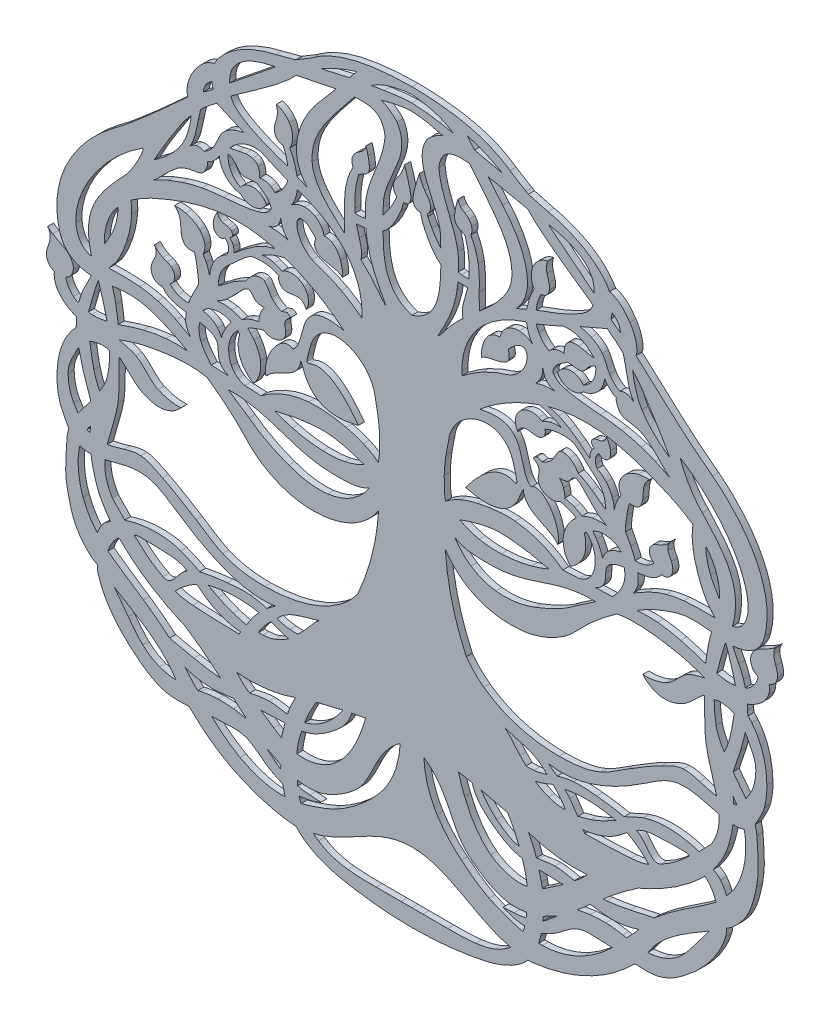
SolidWorks part; units mm, degrees
ref_plane "Front Plane" through (0, 0, 0) normal (0, 0, 1) x (1, 0, 0)
ref_plane "Top Plane" through (0, 0, 0) normal (0, 1, 0) x (1, 0, 0)
ref_plane "Right Plane" through (0, 0, 0) normal (1, 0, 0) x (0, 0, -1)
sketch "Sketch4" plane through (0, 0, 0) normal (0, 0, 1) x (1, 0, 0)
  line L0 (124.1467, 202.4567) -> (123.9762, 202.5007)
  line L1 (91.4206, 170.146) -> (91.56, 169.8814)
  line L2 (105.9644, 182.4526) -> (106.0481, 182.5183)
  line L3 (129.3501, 171.0909) -> (130.0283, 171.2663)
  line L4 (89.4752, 161.6914) -> (82.6983, 162.0308)
  line L5 (83.0498, 199.8539) -> (83.169, 199.9004)
  line L6 (180.6533, 202.4567) -> (180.8238, 202.5007)
  line L7 (213.3794, 170.146) -> (213.24, 169.8814)
  line L8 (198.8355, 182.4526) -> (198.7519, 182.5183)
  line L9 (175.4499, 171.0909) -> (174.7717, 171.2663)
  line L10 (215.3248, 161.6914) -> (222.1017, 162.0308)
  line L11 (221.7502, 199.8539) -> (221.6309, 199.9004)
  line L12 (61.7703, 199.4023) -> (61.7055, 199.6124)
  line L13 (65.2856, 200.833) -> (65.3474, 200.7194)
  line L14 (243.0297, 199.4023) -> (243.0945, 199.6124)
  line L15 (239.5144, 200.833) -> (239.4526, 200.7194)
  line L16 (152.4, 8.2515) -> (147.8055, 8.2281)
  line L17 (156.9944, 8.2281) -> (152.4, 8.2515)
  line L18 (112.5054, 62.5359) -> (113.371, 62.7419)
  line L19 (192.2946, 62.5359) -> (191.429, 62.7419)
  spline S0 degree 3 poles (100.7984, 223.4153) (98.4467, 225.8232) (97.7055, 228.2584) (97.8592, 230.4797) knots 0 0 0 0 1 1 1 1
  spline S1 degree 3 poles (97.8592, 230.4797) (97.6703, 229.68) (97.4734, 228.8369) (97.1727, 228.1396) knots 0 0 0 0 1 1 1 1
  spline S2 degree 3 poles (97.1727, 228.1396) (96.4335, 226.4252) (94.9966, 225.0979) (92.765, 224.6223) knots 0 0 0 0 1 1 1 1
  spline S3 degree 3 poles (92.765, 224.6223) (95.5406, 224.6006) (98.3342, 224.496) (100.7984, 223.4153) knots 0 0 0 0 1 1 1 1
  spline S4 degree 3 poles (204.0016, 223.4153) (206.3533, 225.8232) (207.0944, 228.2584) (206.9408, 230.4797) knots 0 0 0 0 1 1 1 1
  spline S5 degree 3 poles (206.9408, 230.4797) (207.1297, 229.68) (207.3266, 228.8369) (207.6273, 228.1396) knots 0 0 0 0 1 1 1 1
  spline S6 degree 3 poles (207.6273, 228.1396) (208.3665, 226.4252) (209.8033, 225.0979) (212.035, 224.6223) knots 0 0 0 0 1 1 1 1
  spline S7 degree 3 poles (212.035, 224.6223) (209.2594, 224.6006) (206.4658, 224.496) (204.0016, 223.4153) knots 0 0 0 0 1 1 1 1
  spline S8 degree 3 poles (104.5811, 243.757) (104.5653, 243.5831) (104.5163, 243.1101) (104.489, 242.9346) knots 0 0 0 0 1 1 1 1
  spline S9 degree 3 poles (104.489, 242.9346) (104.1583, 240.8122) (103.3668, 238.7628) (102.1852, 236.9691) knots 0 0 0 0 1 1 1 1
  spline S10 degree 3 poles (102.1852, 236.9691) (103.7225, 238.2262) (105.6929, 238.9432) (107.6787, 238.9682) knots 0 0 0 0 1 1 1 1
  spline S11 degree 3 poles (107.6787, 238.9682) (109.2432, 238.9878) (110.8178, 238.5802) (112.1502, 237.76) knots 0 0 0 0 1 1 1 1
  spline S12 degree 3 poles (112.1502, 237.76) (113.9715, 236.6387) (115.2968, 234.7416) (115.7231, 232.6458) knots 0 0 0 0 1 1 1 1
  spline S13 degree 3 poles (115.7231, 232.6458) (116.8967, 232.72) (118.0907, 232.4372) (119.1063, 231.8443) knots 0 0 0 0 1 1 1 1
  spline S14 degree 3 poles (119.1063, 231.8443) (120.8098, 230.8499) (121.9201, 229.066) (122.592, 227.2115) knots 0 0 0 0 1 1 1 1
  spline S15 degree 3 poles (122.592, 227.2115) (123.2558, 225.3795) (123.5552, 223.4163) (123.4677, 221.4698) knots 0 0 0 0 1 1 1 1
  spline S16 degree 3 poles (123.4677, 221.4698) (122.5589, 222.0998) (121.5364, 222.5651) (120.4644, 222.8364) knots 0 0 0 0 1 1 1 1
  spline S17 degree 3 poles (120.4644, 222.8364) (117.7679, 223.4495) (112.9753, 223.794) (111.9836, 226.4396) knots 0 0 0 0 1 1 1 1
  spline S18 degree 3 poles (111.9836, 226.4396) (111.6343, 227.4525) (111.9168, 228.9805) (112.2692, 229.9921) knots 0 0 0 0 1 1 1 1
  spline S19 degree 3 poles (112.2692, 229.9921) (111.6991, 230.7655) (110.0553, 232.1525) (109.2996, 232.7777) knots 0 0 0 0 1 1 1 1
  spline S20 degree 3 poles (109.2996, 232.7777) (106.5263, 234.9791) (104.7813, 233.7766) (104.4992, 232.1894) knots 0 0 0 0 1 1 1 1
  spline S21 degree 3 poles (104.4992, 232.1894) (103.7789, 228.1372) (107.1393, 223.4113) (110.6838, 221.5599) knots 0 0 0 0 1 1 1 1
  spline S22 degree 3 poles (110.6838, 221.5599) (114.5699, 219.5301) (114.8213, 220.6366) (122.9632, 216.4526) knots 0 0 0 0 1 1 1 1
  spline S23 degree 2 poles (122.9632, 216.4526) (126.0321, 214.8755) (131.6077, 210.7587) knots 0 0 0 1 1 1
  spline S24 degree 3 poles (131.6077, 210.7587) (131.6395, 211.3789) (131.5715, 211.9903) (131.5695, 212.5928) knots 0 0 0 0 1 1 1 1
  spline S25 degree 3 poles (131.5695, 212.5928) (131.5128, 229.356) (118.5563, 239.3044) (104.5811, 243.757) knots 0 0 0 0 1 1 1 1
  spline S26 degree 3 poles (200.2189, 243.757) (200.2347, 243.5831) (200.2837, 243.1101) (200.311, 242.9346) knots 0 0 0 0 1 1 1 1
  spline S27 degree 3 poles (200.311, 242.9346) (200.6417, 240.8122) (201.4332, 238.7628) (202.6148, 236.9691) knots 0 0 0 0 1 1 1 1
  spline S28 degree 3 poles (202.6148, 236.9691) (201.0775, 238.2262) (199.107, 238.9432) (197.1213, 238.9682) knots 0 0 0 0 1 1 1 1
  spline S29 degree 3 poles (197.1213, 238.9682) (195.5568, 238.9878) (193.9822, 238.5802) (192.6498, 237.76) knots 0 0 0 0 1 1 1 1
  spline S30 degree 3 poles (192.6498, 237.76) (190.8285, 236.6387) (189.5032, 234.7416) (189.0769, 232.6458) knots 0 0 0 0 1 1 1 1
  spline S31 degree 3 poles (189.0769, 232.6458) (187.9032, 232.72) (186.7093, 232.4372) (185.6937, 231.8443) knots 0 0 0 0 1 1 1 1
  spline S32 degree 3 poles (185.6937, 231.8443) (183.9902, 230.8499) (182.8799, 229.066) (182.208, 227.2115) knots 0 0 0 0 1 1 1 1
  spline S33 degree 3 poles (182.208, 227.2115) (181.5442, 225.3795) (181.2448, 223.4163) (181.3323, 221.4698) knots 0 0 0 0 1 1 1 1
  spline S34 degree 3 poles (181.3323, 221.4698) (182.241, 222.0998) (183.2636, 222.5651) (184.3356, 222.8364) knots 0 0 0 0 1 1 1 1
  spline S35 degree 3 poles (184.3356, 222.8364) (187.0321, 223.4495) (191.8247, 223.794) (192.8164, 226.4396) knots 0 0 0 0 1 1 1 1
  spline S36 degree 3 poles (192.8164, 226.4396) (193.1657, 227.4525) (192.8832, 228.9805) (192.5308, 229.9921) knots 0 0 0 0 1 1 1 1
  spline S37 degree 3 poles (192.5308, 229.9921) (193.1008, 230.7655) (194.7447, 232.1525) (195.5003, 232.7777) knots 0 0 0 0 1 1 1 1
  spline S38 degree 3 poles (195.5003, 232.7777) (198.2737, 234.9791) (200.0187, 233.7766) (200.3008, 232.1894) knots 0 0 0 0 1 1 1 1
  spline S39 degree 3 poles (200.3008, 232.1894) (201.0211, 228.1372) (197.6607, 223.4113) (194.1162, 221.5599) knots 0 0 0 0 1 1 1 1
  spline S40 degree 3 poles (194.1162, 221.5599) (190.2301, 219.5301) (189.9787, 220.6366) (181.8368, 216.4526) knots 0 0 0 0 1 1 1 1
  spline S41 degree 2 poles (181.8368, 216.4526) (178.7679, 214.8755) (173.1923, 210.7587) knots 0 0 0 1 1 1
  spline S42 degree 3 poles (173.1923, 210.7587) (173.1605, 211.3789) (173.2285, 211.9903) (173.2305, 212.5928) knots 0 0 0 0 1 1 1 1
  spline S43 degree 3 poles (173.2305, 212.5928) (173.2872, 229.356) (186.2436, 239.3044) (200.2189, 243.757) knots 0 0 0 0 1 1 1 1
  spline S44 degree 3 poles (89.3745, 249.8333) (86.5969, 250.2558) (84.0383, 249.8613) (81.7563, 248.8406) knots 0 0 0 0 1 1 1 1
  spline S45 degree 3 poles (81.7563, 248.8406) (79.795, 247.9634) (77.9002, 246.4175) (76.5323, 244.7608) knots 0 0 0 0 1 1 1 1
  spline S46 degree 3 poles (76.5323, 244.7608) (77.6423, 244.8045) (78.8894, 245.1423) (79.9804, 245.3519) knots 0 0 0 0 1 1 1 1
  spline S47 degree 3 poles (79.9804, 245.3519) (80.9624, 245.5405) (81.9326, 245.7958) (82.9241, 245.9253) knots 0 0 0 0 1 1 1 1
  spline S48 degree 3 poles (82.9241, 245.9253) (83.9156, 246.0548) (84.9434, 246.054) (85.8923, 245.7387) knots 0 0 0 0 1 1 1 1
  spline S49 degree 3 poles (85.8923, 245.7387) (87.002, 245.37) (87.6797, 244.8459) (88.2347, 243.8166) knots 0 0 0 0 1 1 1 1
  spline S50 degree 3 poles (88.2347, 243.8166) (88.7896, 242.7873) (88.9588, 241.334) (88.9143, 240.134) knots 0 0 0 0 1 1 1 1
  spline S51 degree 3 poles (88.9143, 240.134) (90.4803, 240.4409) (92.1547, 240.1577) (93.5327, 239.3528) knots 0 0 0 0 1 1 1 1
  spline S52 degree 3 poles (93.5327, 239.3528) (94.1544, 238.9897) (94.7163, 238.5244) (95.1891, 237.9814) knots 0 0 0 0 1 1 1 1
  spline S53 degree 3 poles (95.1891, 237.9814) (97.0505, 239.0277) (98.5852, 240.6461) (99.5312, 242.5604) knots 0 0 0 0 1 1 1 1
  spline S54 degree 3 poles (99.5312, 242.5604) (99.9049, 243.3167) (100.384, 244.1569) (100.5653, 245.0054) knots 0 0 0 0 1 1 1 1
  spline S55 degree 3 poles (100.5653, 245.0054) (97.2079, 246.3638) (93.7514, 247.7642) (89.3745, 249.8333) knots 0 0 0 0 1 1 1 1
  spline S56 degree 3 poles (215.4255, 249.8333) (218.2031, 250.2558) (220.7616, 249.8613) (223.0437, 248.8406) knots 0 0 0 0 1 1 1 1
  spline S57 degree 3 poles (223.0437, 248.8406) (225.005, 247.9634) (226.8998, 246.4175) (228.2677, 244.7608) knots 0 0 0 0 1 1 1 1
  spline S58 degree 3 poles (228.2677, 244.7608) (227.1577, 244.8045) (225.9105, 245.1423) (224.8196, 245.3519) knots 0 0 0 0 1 1 1 1
  spline S59 degree 3 poles (224.8196, 245.3519) (223.8376, 245.5405) (222.8674, 245.7958) (221.8759, 245.9253) knots 0 0 0 0 1 1 1 1
  spline S60 degree 3 poles (221.8759, 245.9253) (220.8844, 246.0548) (219.8566, 246.054) (218.9077, 245.7387) knots 0 0 0 0 1 1 1 1
  spline S61 degree 3 poles (218.9077, 245.7387) (217.798, 245.37) (217.1203, 244.8459) (216.5653, 243.8166) knots 0 0 0 0 1 1 1 1
  spline S62 degree 3 poles (216.5653, 243.8166) (216.0103, 242.7873) (215.8412, 241.334) (215.8857, 240.134) knots 0 0 0 0 1 1 1 1
  spline S63 degree 3 poles (215.8857, 240.134) (214.3197, 240.4409) (212.6453, 240.1577) (211.2673, 239.3528) knots 0 0 0 0 1 1 1 1
  spline S64 degree 3 poles (211.2673, 239.3528) (210.6456, 238.9897) (210.0837, 238.5244) (209.6109, 237.9814) knots 0 0 0 0 1 1 1 1
  spline S65 degree 3 poles (209.6109, 237.9814) (207.7495, 239.0277) (206.2148, 240.6461) (205.2688, 242.5604) knots 0 0 0 0 1 1 1 1
  spline S66 degree 3 poles (205.2688, 242.5604) (204.8951, 243.3167) (204.416, 244.1569) (204.2346, 245.0054) knots 0 0 0 0 1 1 1 1
  spline S67 degree 3 poles (204.2346, 245.0054) (207.5921, 246.3638) (211.0486, 247.7642) (215.4255, 249.8333) knots 0 0 0 0 1 1 1 1
  spline S68 degree 3 poles (63.2848, 248.1446) (63.7174, 250.0767) (63.8591, 250.6117) (64.234, 252.4688) knots 0 0 0 0 1 1 1 1
  spline S69 degree 3 poles (64.234, 252.4688) (66.1491, 254.5767) (68.8821, 256.4751) (70.9553, 258.1318) knots 0 0 0 0 1 1 1 1
  spline S70 degree 3 poles (70.9553, 258.1318) (75.2567, 256.2076) (78.583, 254.7827) (82.4231, 253.1532) knots 0 0 0 0 1 1 1 1
  spline S71 degree 3 poles (82.4231, 253.1532) (81.0098, 252.962) (79.2735, 252.4868) (77.6552, 251.751) knots 0 0 0 0 1 1 1 1
  spline S72 degree 3 poles (77.6552, 251.751) (75.8609, 250.9352) (74.1857, 249.7723) (73.025, 248.1792) knots 0 0 0 0 1 1 1 1
  spline S73 degree 3 poles (73.025, 248.1792) (71.7106, 246.3751) (71.1308, 244.14) (69.9823, 242.226) knots 0 0 0 0 1 1 1 1
  spline S74 degree 3 poles (69.9823, 242.226) (68.9599, 240.5221) (67.4845, 239.0928) (65.749, 238.125) knots 0 0 0 0 1 1 1 1
  spline S75 degree 3 poles (65.749, 238.125) (64.7083, 238.6862) (63.4505, 238.8313) (62.3094, 238.5219) knots 0 0 0 0 1 1 1 1
  spline S76 degree 3 poles (62.3094, 238.5219) (61.376, 238.2688) (60.5259, 237.7175) (59.7888, 237.0176) knots 0 0 0 0 1 1 1 1
  spline S77 degree 3 poles (59.7888, 237.0176) (61.9563, 240.5942) (62.1075, 242.8866) (63.2848, 248.1446) knots 0 0 0 0 1 1 1 1
  spline S78 degree 3 poles (241.5152, 248.1446) (241.0826, 250.0767) (240.9409, 250.6117) (240.566, 252.4688) knots 0 0 0 0 1 1 1 1
  spline S79 degree 3 poles (240.566, 252.4688) (238.6509, 254.5767) (235.9179, 256.4751) (233.8447, 258.1318) knots 0 0 0 0 1 1 1 1
  spline S80 degree 3 poles (233.8447, 258.1318) (229.5433, 256.2076) (226.217, 254.7827) (222.3769, 253.1532) knots 0 0 0 0 1 1 1 1
  spline S81 degree 3 poles (222.3769, 253.1532) (223.7902, 252.962) (225.5265, 252.4868) (227.1448, 251.751) knots 0 0 0 0 1 1 1 1
  spline S82 degree 3 poles (227.1448, 251.751) (228.9391, 250.9352) (230.6143, 249.7723) (231.775, 248.1792) knots 0 0 0 0 1 1 1 1
  spline S83 degree 3 poles (231.775, 248.1792) (233.0894, 246.3751) (233.6692, 244.14) (234.8177, 242.226) knots 0 0 0 0 1 1 1 1
  spline S84 degree 3 poles (234.8177, 242.226) (235.8401, 240.5221) (237.3155, 239.0928) (239.051, 238.125) knots 0 0 0 0 1 1 1 1
  spline S85 degree 3 poles (239.051, 238.125) (240.0917, 238.6862) (241.3495, 238.8313) (242.4906, 238.5219) knots 0 0 0 0 1 1 1 1
  spline S86 degree 3 poles (242.4906, 238.5219) (243.424, 238.2688) (244.2741, 237.7175) (245.0111, 237.0176) knots 0 0 0 0 1 1 1 1
  spline S87 degree 3 poles (245.0111, 237.0176) (242.8437, 240.5942) (242.6925, 242.8866) (241.5152, 248.1446) knots 0 0 0 0 1 1 1 1
  spline S88 degree 3 poles (56.5216, 236.1076) (58.7281, 239.7352) (59.9959, 244.8161) (60.329, 248.2632) knots 0 0 0 0 1 1 1 1
  spline S89 degree 3 poles (60.329, 248.2632) (59.4049, 247.5752) (57.7435, 245.2821) (57.0117, 244.3367) knots 0 0 0 0 1 1 1 1
  spline S90 degree 3 poles (57.0117, 244.3367) (53.9371, 239.9612) (47.353, 229.4421) (44.9156, 224.5938) knots 0 0 0 0 1 1 1 1
  spline S91 degree 3 poles (44.9156, 224.5938) (49.3195, 227.5969) (53.6897, 231.4517) (56.5216, 236.1076) knots 0 0 0 0 1 1 1 1
  spline S92 degree 3 poles (248.2784, 236.1076) (246.0718, 239.7352) (244.8041, 244.8161) (244.471, 248.2632) knots 0 0 0 0 1 1 1 1
  spline S93 degree 3 poles (244.471, 248.2632) (245.3951, 247.5752) (247.0565, 245.2821) (247.7883, 244.3367) knots 0 0 0 0 1 1 1 1
  spline S94 degree 3 poles (247.7883, 244.3367) (250.8629, 239.9612) (257.447, 229.4421) (259.8844, 224.5938) knots 0 0 0 0 1 1 1 1
  spline S95 degree 3 poles (259.8844, 224.5938) (255.4805, 227.5969) (251.1103, 231.4517) (248.2784, 236.1076) knots 0 0 0 0 1 1 1 1
  spline S96 degree 3 poles (108.9436, 246.3864) (99.1563, 256.4976) (106.413, 272.0893) (114.5335, 280.8354) knots 0 0 0 0 1 1 1 1
  spline S97 degree 3 poles (114.5335, 280.8354) (115.7926, 282.4321) (119.4612, 286.6279) (120.7433, 288.1846) knots 0 0 0 0 1 1 1 1
  spline S98 degree 3 poles (120.7433, 288.1846) (117.9502, 287.7388) (114.752, 286.9648) (111.7581, 286.3466) knots 0 0 0 0 1 1 1 1
  spline S99 degree 2 poles (111.7581, 286.3466) (109.1976, 285.8179) (104.0796, 284.7463) knots 0 0 0 1 1 1
  spline S100 degree 2 poles (104.0796, 284.7463) (102.0501, 282.7285) (101.1624, 281.7946) knots 0 0 0 1 1 1
  spline S101 degree 3 poles (101.1624, 281.7946) (93.6217, 275.03) (85.0819, 269.7463) (76.9684, 263.7279) knots 0 0 0 0 1 1 1 1
  spline S102 degree 3 poles (76.9684, 263.7279) (77.9157, 258.3314) (90.2551, 253.6246) (100.5939, 250.0018) knots 0 0 0 0 1 1 1 1
  spline S103 degree 3 poles (100.5939, 250.0018) (100.4911, 250.8066) (100.3949, 251.5984) (100.2795, 252.102) knots 0 0 0 0 1 1 1 1
  spline S104 degree 3 poles (100.2795, 252.102) (99.9131, 253.7012) (99.3626, 255.2582) (98.6425, 256.7324) knots 0 0 0 0 1 1 1 1
  spline S105 degree 3 poles (98.6425, 256.7324) (97.6853, 256.7086) (96.7253, 257.1101) (96.07, 257.8082) knots 0 0 0 0 1 1 1 1
  spline S106 degree 3 poles (96.07, 257.8082) (95.4937, 258.4221) (95.1606, 259.2396) (95.0469, 260.074) knots 0 0 0 0 1 1 1 1
  spline S107 degree 3 poles (95.0469, 260.074) (94.9333, 260.9084) (95.0287, 261.7608) (95.2281, 262.579) knots 0 0 0 0 1 1 1 1
  spline S108 degree 3 poles (95.2281, 262.579) (95.4665, 263.5572) (95.8515, 264.4959) (96.07, 265.4788) knots 0 0 0 0 1 1 1 1
  spline S109 degree 3 poles (96.07, 265.4788) (96.4128, 267.0211) (96.3311, 268.6556) (95.8361, 270.156) knots 0 0 0 0 1 1 1 1
  spline S110 degree 3 poles (95.8361, 270.156) (98.0716, 269.6492) (100.0844, 268.2245) (101.3054, 266.2847) knots 0 0 0 0 1 1 1 1
  spline S111 degree 3 poles (101.3054, 266.2847) (102.5265, 264.3448) (102.9407, 261.9138) (102.431, 259.6791) knots 0 0 0 0 1 1 1 1
  spline S112 degree 3 poles (102.431, 259.6791) (102.2326, 258.8091) (101.9001, 257.9699) (101.4488, 257.2001) knots 0 0 0 0 1 1 1 1
  spline S113 degree 3 poles (101.4488, 257.2001) (102.7365, 254.8792) (103.6704, 252.3625) (104.2084, 249.7634) knots 0 0 0 0 1 1 1 1
  spline S114 degree 3 poles (104.2084, 249.7634) (104.2839, 249.3988) (104.3846, 249.0817) (104.3807, 248.4701) knots 0 0 0 0 1 1 1 1
  spline S115 degree 3 poles (104.3807, 248.4701) (106.1391, 247.5975) (107.7081, 246.9843) (108.9436, 246.3864) knots 0 0 0 0 1 1 1 1
  spline S116 degree 3 poles (195.8564, 246.3864) (205.6437, 256.4976) (198.387, 272.0893) (190.2664, 280.8354) knots 0 0 0 0 1 1 1 1
  spline S117 degree 3 poles (190.2664, 280.8354) (189.0074, 282.4321) (185.3388, 286.6279) (184.0567, 288.1846) knots 0 0 0 0 1 1 1 1
  spline S118 degree 3 poles (184.0567, 288.1846) (186.8498, 287.7388) (190.048, 286.9648) (193.0419, 286.3466) knots 0 0 0 0 1 1 1 1
  spline S119 degree 2 poles (193.0419, 286.3466) (195.6024, 285.8179) (200.7204, 284.7463) knots 0 0 0 1 1 1
  spline S120 degree 2 poles (200.7204, 284.7463) (202.7498, 282.7285) (203.6376, 281.7946) knots 0 0 0 1 1 1
  spline S121 degree 3 poles (203.6376, 281.7946) (211.1783, 275.03) (219.7181, 269.7463) (227.8316, 263.7279) knots 0 0 0 0 1 1 1 1
  spline S122 degree 3 poles (227.8316, 263.7279) (226.8842, 258.3314) (214.5449, 253.6246) (204.2061, 250.0018) knots 0 0 0 0 1 1 1 1
  spline S123 degree 3 poles (204.2061, 250.0018) (204.3089, 250.8066) (204.4051, 251.5984) (204.5205, 252.102) knots 0 0 0 0 1 1 1 1
  spline S124 degree 3 poles (204.5205, 252.102) (204.8869, 253.7012) (205.4374, 255.2582) (206.1575, 256.7324) knots 0 0 0 0 1 1 1 1
  spline S125 degree 3 poles (206.1575, 256.7324) (207.1147, 256.7086) (208.0747, 257.1101) (208.73, 257.8082) knots 0 0 0 0 1 1 1 1
  spline S126 degree 3 poles (208.73, 257.8082) (209.3063, 258.4221) (209.6394, 259.2396) (209.7531, 260.074) knots 0 0 0 0 1 1 1 1
  spline S127 degree 3 poles (209.7531, 260.074) (209.8667, 260.9084) (209.7713, 261.7608) (209.5719, 262.579) knots 0 0 0 0 1 1 1 1
  spline S128 degree 3 poles (209.5719, 262.579) (209.3335, 263.5572) (208.9485, 264.4959) (208.73, 265.4788) knots 0 0 0 0 1 1 1 1
  spline S129 degree 3 poles (208.73, 265.4788) (208.3872, 267.0211) (208.4689, 268.6556) (208.9638, 270.156) knots 0 0 0 0 1 1 1 1
  spline S130 degree 3 poles (208.9638, 270.156) (206.7284, 269.6492) (204.7156, 268.2245) (203.4946, 266.2847) knots 0 0 0 0 1 1 1 1
  spline S131 degree 3 poles (203.4946, 266.2847) (202.2735, 264.3448) (201.8593, 261.9138) (202.369, 259.6791) knots 0 0 0 0 1 1 1 1
  spline S132 degree 3 poles (202.369, 259.6791) (202.5674, 258.8091) (202.8999, 257.9699) (203.3512, 257.2001) knots 0 0 0 0 1 1 1 1
  spline S133 degree 3 poles (203.3512, 257.2001) (202.0635, 254.8792) (201.1296, 252.3625) (200.5916, 249.7634) knots 0 0 0 0 1 1 1 1
  spline S134 degree 3 poles (200.5916, 249.7634) (200.5161, 249.3988) (200.4154, 249.0817) (200.4193, 248.4701) knots 0 0 0 0 1 1 1 1
  spline S135 degree 3 poles (200.4193, 248.4701) (198.6609, 247.5975) (197.0919, 246.9843) (195.8564, 246.3864) knots 0 0 0 0 1 1 1 1
  spline S136 degree 3 poles (129.4371, 298.7606) (124.428, 297.3007) (119.2122, 295.0858) (114.6869, 292.4347) knots 0 0 0 0 1 1 1 1
  spline S137 degree 3 poles (114.6869, 292.4347) (114.7743, 292.3899) (115.0619, 292.4909) (115.1634, 292.5134) knots 0 0 0 0 1 1 1 1
  spline S138 degree 3 poles (115.1634, 292.5134) (118.8134, 293.3211) (122.5339, 294.1357) (126.2731, 294.9789) knots 0 0 0 0 1 1 1 1
  spline S139 degree 3 poles (126.2731, 294.9789) (127.4382, 296.4139) (128.3034, 297.377) (129.4371, 298.7606) knots 0 0 0 0 1 1 1 1
  spline S140 degree 3 poles (175.3629, 298.7606) (180.372, 297.3007) (185.5878, 295.0858) (190.1131, 292.4347) knots 0 0 0 0 1 1 1 1
  spline S141 degree 3 poles (190.1131, 292.4347) (190.0257, 292.3899) (189.7381, 292.4909) (189.6365, 292.5134) knots 0 0 0 0 1 1 1 1
  spline S142 degree 3 poles (189.6365, 292.5134) (185.9866, 293.3211) (182.2661, 294.1357) (178.5269, 294.9789) knots 0 0 0 0 1 1 1 1
  spline S143 degree 3 poles (178.5269, 294.9789) (177.3618, 296.4139) (176.4966, 297.377) (175.3629, 298.7606) knots 0 0 0 0 1 1 1 1
  spline S144 degree 3 poles (152.4, 298.9232) (148.6496, 298.8228) (144.359, 298.242) (140.831, 297.6643) knots 0 0 0 0 1 1 1 1
  spline S145 degree 3 poles (140.831, 297.6643) (138.9136, 297.3503) (137.0533, 297.0896) (135.2322, 296.6129) knots 0 0 0 0 1 1 1 1
  spline S146 degree 3 poles (135.2322, 296.6129) (137.4724, 298.1704) (140.0061, 299.5052) (142.9771, 300.2975) knots 0 0 0 0 1 1 1 1
  spline S147 degree 3 poles (142.9771, 300.2975) (145.5603, 300.9863) (149.3794, 301.9033) (152.4, 301.9499) knots 0 0 0 0 1 1 1 1
  spline S148 degree 3 poles (152.4, 301.9499) (155.4206, 301.9033) (159.2397, 300.9863) (161.8229, 300.2975) knots 0 0 0 0 1 1 1 1
  spline S149 degree 3 poles (161.8229, 300.2975) (164.7939, 299.5052) (167.3275, 298.1704) (169.5678, 296.6129) knots 0 0 0 0 1 1 1 1
  spline S150 degree 3 poles (169.5678, 296.6129) (167.7467, 297.0896) (165.8864, 297.3503) (163.969, 297.6643) knots 0 0 0 0 1 1 1 1
  spline S151 degree 3 poles (163.969, 297.6643) (160.441, 298.242) (156.1504, 298.8228) (152.4, 298.9232) knots 0 0 0 0 1 1 1 1
  spline S152 degree 2 poles (127.6425, 288.1624) (128.2065, 289.0471) (128.6638, 289.0858) knots 0 0 0 1 1 1
  spline S153 degree 3 poles (128.6638, 289.0858) (133.5843, 289.5017) (140.3137, 289.6551) (141.1643, 281.1364) knots 0 0 0 0 1 1 1 1
  spline S154 degree 3 poles (141.1643, 281.1364) (140.7428, 275.7009) (138.5923, 270.7153) (136.5897, 265.6973) knots 0 0 0 0 1 1 1 1
  spline S155 degree 3 poles (136.5897, 265.6973) (135.1825, 262.171) (133.8483, 258.6288) (133.2387, 254.9031) knots 0 0 0 0 1 1 1 1
  spline S156 degree 3 poles (133.2387, 254.9031) (132.9052, 252.8655) (133.0422, 250.0144) (133.0438, 247.5605) knots 0 0 0 0 1 1 1 1
  spline S157 degree 3 poles (133.0438, 247.5605) (132.5403, 247.3917) (132.2836, 247.3358) (131.7625, 247.2531) knots 0 0 0 0 1 1 1 1
  spline S158 degree 3 poles (131.7625, 247.2531) (130.5825, 247.0659) (129.6184, 247.1501) (128.6341, 247.2021) knots 0 0 0 0 1 1 1 1
  spline S159 degree 3 poles (128.6341, 247.2021) (128.5894, 247.9261) (128.6179, 248.3697) (128.5876, 248.9729) knots 0 0 0 0 1 1 1 1
  spline S160 degree 3 poles (128.5876, 248.9729) (128.3667, 253.3537) (128.8928, 257.7712) (130.1363, 261.9776) knots 0 0 0 0 1 1 1 1
  spline S161 degree 3 poles (130.1363, 261.9776) (130.7984, 262.3965) (131.4801, 262.7846) (132.1782, 263.1402) knots 0 0 0 0 1 1 1 1
  spline S162 degree 3 poles (132.1782, 263.1402) (132.7046, 263.4083) (133.2503, 263.6649) (133.6749, 264.0756) knots 0 0 0 0 1 1 1 1
  spline S163 degree 3 poles (133.6749, 264.0756) (134.083, 264.4704) (134.3573, 264.9918) (134.5008, 265.5412) knots 0 0 0 0 1 1 1 1
  spline S164 degree 3 poles (134.5008, 265.5412) (134.6444, 266.0905) (134.6616, 266.6676) (134.6023, 267.2323) knots 0 0 0 0 1 1 1 1
  spline S165 degree 3 poles (134.6023, 267.2323) (134.4838, 268.3616) (134.4066, 269.4815) (134.1076, 270.577) knots 0 0 0 0 1 1 1 1
  spline S166 degree 3 poles (134.1076, 270.577) (133.7788, 271.7815) (133.7187, 272.6266) (133.1604, 273.7692) knots 0 0 0 0 1 1 1 1
  spline S167 degree 3 poles (133.1604, 273.7692) (133.0725, 272.7137) (132.6397, 272.265) (132.1548, 271.6527) knots 0 0 0 0 1 1 1 1
  spline S168 degree 3 poles (132.1548, 271.6527) (131.69, 271.0658) (131.1496, 270.7081) (130.4009, 270.2496) knots 0 0 0 0 1 1 1 1
  spline S169 degree 3 poles (130.4009, 270.2496) (129.7323, 269.8402) (129.1109, 269.3462) (128.6015, 268.7503) knots 0 0 0 0 1 1 1 1
  spline S170 degree 3 poles (128.6015, 268.7503) (128.092, 268.1545) (127.6966, 267.454) (127.501, 266.6949) knots 0 0 0 0 1 1 1 1
  spline S171 degree 3 poles (127.501, 266.6949) (127.2292, 265.64) (127.3603, 264.4866) (127.8619, 263.5197) knots 0 0 0 0 1 1 1 1
  spline S172 degree 3 poles (127.8619, 263.5197) (126.3251, 260.7756) (125.2675, 257.7639) (124.7511, 254.6614) knots 0 0 0 0 1 1 1 1
  spline S173 degree 3 poles (124.7511, 254.6614) (124.2068, 251.3911) (124.2623, 248.0536) (124.3542, 244.7396) knots 0 0 0 0 1 1 1 1
  spline S174 degree 3 poles (124.3542, 244.7396) (124.4277, 242.0899) (124.3247, 240.2944) (124.3095, 237.7418) knots 0 0 0 0 1 1 1 1
  spline S175 degree 3 poles (124.3095, 237.7418) (119.0239, 242.3103) (111.2418, 249.0361) (110.7609, 256.8215) knots 0 0 0 0 1 1 1 1
  spline S176 degree 3 poles (110.7609, 256.8215) (110.0292, 268.665) (119.6485, 277.7332) (127.6425, 288.1624) knots 0 0 0 0 1 1 1 1
  spline S177 degree 2 poles (177.1575, 288.1624) (176.5935, 289.0471) (176.1362, 289.0858) knots 0 0 0 1 1 1
  spline S178 degree 3 poles (176.1362, 289.0858) (171.2157, 289.5017) (164.4863, 289.6551) (163.6357, 281.1364) knots 0 0 0 0 1 1 1 1
  spline S179 degree 3 poles (163.6357, 281.1364) (164.0572, 275.7009) (166.2077, 270.7153) (168.2103, 265.6973) knots 0 0 0 0 1 1 1 1
  spline S180 degree 3 poles (168.2103, 265.6973) (169.6175, 262.171) (170.9516, 258.6288) (171.5613, 254.9031) knots 0 0 0 0 1 1 1 1
  spline S181 degree 3 poles (171.5613, 254.9031) (171.8948, 252.8655) (171.7578, 250.0144) (171.7562, 247.5605) knots 0 0 0 0 1 1 1 1
  spline S182 degree 3 poles (171.7562, 247.5605) (172.2597, 247.3917) (172.5164, 247.3358) (173.0375, 247.2531) knots 0 0 0 0 1 1 1 1
  spline S183 degree 3 poles (173.0375, 247.2531) (174.2175, 247.0659) (175.1815, 247.1501) (176.1659, 247.2021) knots 0 0 0 0 1 1 1 1
  spline S184 degree 3 poles (176.1659, 247.2021) (176.2106, 247.9261) (176.1821, 248.3697) (176.2124, 248.9729) knots 0 0 0 0 1 1 1 1
  spline S185 degree 3 poles (176.2124, 248.9729) (176.4333, 253.3537) (175.9072, 257.7712) (174.6637, 261.9776) knots 0 0 0 0 1 1 1 1
  spline S186 degree 3 poles (174.6637, 261.9776) (174.0016, 262.3965) (173.3199, 262.7846) (172.6218, 263.1402) knots 0 0 0 0 1 1 1 1
  spline S187 degree 3 poles (172.6218, 263.1402) (172.0954, 263.4083) (171.5497, 263.6649) (171.1251, 264.0756) knots 0 0 0 0 1 1 1 1
  spline S188 degree 3 poles (171.1251, 264.0756) (170.717, 264.4704) (170.4427, 264.9918) (170.2992, 265.5412) knots 0 0 0 0 1 1 1 1
  spline S189 degree 3 poles (170.2992, 265.5412) (170.1556, 266.0905) (170.1384, 266.6676) (170.1977, 267.2323) knots 0 0 0 0 1 1 1 1
  spline S190 degree 3 poles (170.1977, 267.2323) (170.3162, 268.3616) (170.3933, 269.4815) (170.6924, 270.577) knots 0 0 0 0 1 1 1 1
  spline S191 degree 3 poles (170.6924, 270.577) (171.0212, 271.7815) (171.0813, 272.6266) (171.6396, 273.7692) knots 0 0 0 0 1 1 1 1
  spline S192 degree 3 poles (171.6396, 273.7692) (171.7274, 272.7137) (172.1603, 272.265) (172.6452, 271.6527) knots 0 0 0 0 1 1 1 1
  spline S193 degree 3 poles (172.6452, 271.6527) (173.11, 271.0658) (173.6504, 270.7081) (174.3991, 270.2496) knots 0 0 0 0 1 1 1 1
  spline S194 degree 3 poles (174.3991, 270.2496) (175.0677, 269.8402) (175.6891, 269.3462) (176.1985, 268.7503) knots 0 0 0 0 1 1 1 1
  spline S195 degree 3 poles (176.1985, 268.7503) (176.7079, 268.1545) (177.1034, 267.454) (177.299, 266.6949) knots 0 0 0 0 1 1 1 1
  spline S196 degree 3 poles (177.299, 266.6949) (177.5708, 265.64) (177.4397, 264.4866) (176.9381, 263.5197) knots 0 0 0 0 1 1 1 1
  spline S197 degree 3 poles (176.9381, 263.5197) (178.4749, 260.7756) (179.5325, 257.7639) (180.0489, 254.6614) knots 0 0 0 0 1 1 1 1
  spline S198 degree 3 poles (180.0489, 254.6614) (180.5932, 251.3911) (180.5377, 248.0536) (180.4458, 244.7396) knots 0 0 0 0 1 1 1 1
  spline S199 degree 3 poles (180.4458, 244.7396) (180.3723, 242.0899) (180.4753, 240.2944) (180.4905, 237.7418) knots 0 0 0 0 1 1 1 1
  spline S200 degree 3 poles (180.4905, 237.7418) (185.7761, 242.3103) (193.5582, 249.0361) (194.0391, 256.8215) knots 0 0 0 0 1 1 1 1
  spline S201 degree 3 poles (194.0391, 256.8215) (194.7708, 268.665) (185.1515, 277.7332) (177.1575, 288.1624) knots 0 0 0 0 1 1 1 1
  spline S202 degree 3 poles (152.4, 295.8123) (148.1396, 295.8206) (143.8, 294.6762) (139.6653, 293.5948) knots 0 0 0 0 1 1 1 1
  spline S203 degree 3 poles (139.6653, 293.5948) (141.9405, 292.6266) (144.5408, 290.7806) (146.1629, 288.9226) knots 0 0 0 0 1 1 1 1
  spline S204 degree 3 poles (146.1629, 288.9226) (152.9497, 277.7886) (140.172, 267.2265) (140.4231, 255.4318) knots 0 0 0 0 1 1 1 1
  spline S205 degree 3 poles (140.4231, 255.4318) (140.4211, 254.8226) (140.3685, 253.3805) (140.3831, 252.4796) knots 0 0 0 0 1 1 1 1
  spline S206 degree 3 poles (140.3831, 252.4796) (140.8963, 253.0192) (141.1842, 253.5226) (141.5521, 254) knots 0 0 0 0 1 1 1 1
  spline S207 degree 3 poles (141.5521, 254) (142.4882, 255.2143) (143.3425, 256.4915) (144.1082, 257.8198) knots 0 0 0 0 1 1 1 1
  spline S208 degree 3 poles (144.1082, 257.8198) (144.7367, 258.91) (145.3054, 260.0346) (145.8106, 261.1872) knots 0 0 0 0 1 1 1 1
  spline S209 degree 3 poles (145.8106, 261.1872) (145.8236, 261.4014) (145.9489, 261.92) (145.9526, 262.1346) knots 0 0 0 0 1 1 1 1
  spline S210 degree 3 poles (145.9526, 262.1346) (145.4048, 262.3679) (144.5896, 263.8827) (144.5842, 264.916) knots 0 0 0 0 1 1 1 1
  spline S211 degree 3 poles (144.5842, 264.916) (144.5742, 266.7836) (145.8088, 268.5347) (147.005, 269.9689) knots 0 0 0 0 1 1 1 1
  spline S212 degree 3 poles (147.005, 269.9689) (147.9735, 271.1302) (148.9766, 273.4029) (149.2968, 275.0203) knots 0 0 0 0 1 1 1 1
  spline S213 degree 3 poles (149.2968, 275.0203) (150.4961, 271.6621) (151.5909, 267.5869) (151.8927, 265.3619) knots 0 0 0 0 1 1 1 1
  spline S214 degree 3 poles (151.8927, 265.3619) (152.1206, 263.6821) (151.7069, 260.9502) (148.8937, 261.255) knots 0 0 0 0 1 1 1 1
  spline S215 degree 3 poles (148.8937, 261.255) (148.6481, 260.757) (148.3135, 258.7883) (147.8124, 257.6319) knots 0 0 0 0 1 1 1 1
  spline S216 degree 3 poles (147.8124, 257.6319) (146.4434, 254.4727) (144.9079, 251.2844) (142.6105, 248.7083) knots 0 0 0 0 1 1 1 1
  spline S217 degree 3 poles (142.6105, 248.7083) (141.9444, 247.9614) (141.259, 247.3115) (140.3496, 246.5857) knots 0 0 0 0 1 1 1 1
  spline S218 degree 3 poles (140.3496, 246.5857) (140.3546, 236.2403) (141.4941, 225.5851) (152.4, 222.2438) knots 0 0 0 0 1 1 1 1
  spline S219 degree 3 poles (152.4, 222.2438) (163.3059, 225.5851) (164.4454, 236.2403) (164.4504, 246.5857) knots 0 0 0 0 1 1 1 1
  spline S220 degree 3 poles (164.4504, 246.5857) (163.5409, 247.3115) (162.8556, 247.9614) (162.1895, 248.7083) knots 0 0 0 0 1 1 1 1
  spline S221 degree 3 poles (162.1895, 248.7083) (159.8921, 251.2844) (158.3565, 254.4727) (156.9876, 257.6319) knots 0 0 0 0 1 1 1 1
  spline S222 degree 3 poles (156.9876, 257.6319) (156.4865, 258.7883) (156.1519, 260.757) (155.9063, 261.255) knots 0 0 0 0 1 1 1 1
  spline S223 degree 3 poles (155.9063, 261.255) (153.0931, 260.9502) (152.6794, 263.6821) (152.9073, 265.3619) knots 0 0 0 0 1 1 1 1
  spline S224 degree 3 poles (152.9073, 265.3619) (153.2091, 267.5869) (154.3038, 271.6621) (155.5032, 275.0203) knots 0 0 0 0 1 1 1 1
  spline S225 degree 3 poles (155.5032, 275.0203) (155.8234, 273.4029) (156.8265, 271.1302) (157.795, 269.9689) knots 0 0 0 0 1 1 1 1
  spline S226 degree 3 poles (157.795, 269.9689) (158.9912, 268.5347) (160.2258, 266.7836) (160.2158, 264.916) knots 0 0 0 0 1 1 1 1
  spline S227 degree 3 poles (160.2158, 264.916) (160.2108, 263.8827) (159.3952, 262.3679) (158.8474, 262.1346) knots 0 0 0 0 1 1 1 1
  spline S228 degree 3 poles (158.8474, 262.1346) (158.8514, 261.92) (158.9764, 261.4014) (158.9894, 261.1872) knots 0 0 0 0 1 1 1 1
  spline S229 degree 3 poles (158.9894, 261.1872) (159.4946, 260.0346) (160.0633, 258.91) (160.6917, 257.8198) knots 0 0 0 0 1 1 1 1
  spline S230 degree 3 poles (160.6917, 257.8198) (161.4575, 256.4915) (162.3118, 255.2143) (163.2479, 254) knots 0 0 0 0 1 1 1 1
  spline S231 degree 3 poles (163.2479, 254) (163.6158, 253.5226) (163.9037, 253.0192) (164.4169, 252.4796) knots 0 0 0 0 1 1 1 1
  spline S232 degree 3 poles (164.4169, 252.4796) (164.4314, 253.3805) (164.3788, 254.8226) (164.3769, 255.4318) knots 0 0 0 0 1 1 1 1
  spline S233 degree 3 poles (164.3769, 255.4318) (164.628, 267.2265) (151.8503, 277.7886) (158.6371, 288.9226) knots 0 0 0 0 1 1 1 1
  spline S234 degree 3 poles (158.6371, 288.9226) (160.2591, 290.7806) (162.8595, 292.6266) (165.1347, 293.5948) knots 0 0 0 0 1 1 1 1
  spline S235 degree 3 poles (165.1347, 293.5948) (161, 294.6762) (156.6604, 295.8206) (152.4, 295.8123) knots 0 0 0 0 1 1 1 1
  spline S236 degree 3 poles (108.3885, 212.7081) (111.2073, 211.3233) (113.9414, 209.764) (116.5737, 208.049) knots 0 0 0 0 1 1 1 1
  spline S237 degree 3 poles (116.5737, 208.049) (119.2053, 206.3344) (121.7352, 204.4641) (124.1467, 202.4567) knots 0 0 0 0 1 1 1 1
  spline S238 degree 3 poles (123.9762, 202.5007) (102.9617, 207.2096) (109.1778, 189.8912) (102.6829, 185.1128) knots 0 0 0 0 1 1 1 1
  spline S239 degree 3 poles (102.6829, 185.1128) (98.598, 188.7463) (90.2011, 178.3426) (91.4206, 170.146) knots 0 0 0 0 1 1 1 1
  spline S240 degree 3 poles (91.56, 169.8814) (95.5825, 174.8633) (105.1198, 174.7206) (105.9644, 182.4526) knots 0 0 0 0 1 1 1 1
  spline S241 degree 3 poles (106.0481, 182.5183) (107.4696, 180.8372) (108.7578, 165.9257) (129.3501, 171.0909) knots 0 0 0 0 1 1 1 1
  spline S242 degree 3 poles (130.0283, 171.2663) (118.4183, 187.2048) (111.6062, 184.15) (109.4456, 183.319) knots 0 0 0 0 1 1 1 1
  spline S243 degree 3 poles (109.4456, 183.319) (107.9132, 182.7296) (108.9287, 185.5642) (109.9908, 189.6794) knots 0 0 0 0 1 1 1 1
  spline S244 degree 3 poles (109.9908, 189.6794) (114.1597, 205.4698) (135.2768, 198.7623) (137.1165, 184.7176) knots 0 0 0 0 1 1 1 1
  spline S245 degree 3 poles (137.1165, 184.7176) (137.5484, 182.8118) (137.9299, 180.828) (138.2324, 178.8002) knots 0 0 0 0 1 1 1 1
  spline S246 degree 3 poles (138.2324, 178.8002) (138.6009, 176.3299) (138.8522, 173.7943) (138.9347, 171.2546) knots 0 0 0 0 1 1 1 1
  spline S247 degree 3 poles (138.9347, 171.2546) (139.0273, 168.4058) (138.9159, 164.7085) (138.3972, 162.0598) knots 0 0 0 0 1 1 1 1
  spline S248 degree 3 poles (138.3972, 162.0598) (136.3912, 163.6242) (134.3195, 164.8288) (132.1314, 165.7606) knots 0 0 0 0 1 1 1 1
  spline S249 degree 3 poles (132.1314, 165.7606) (129.7869, 166.7589) (127.4601, 167.4414) (124.9752, 168.0056) knots 0 0 0 0 1 1 1 1
  spline S250 degree 3 poles (124.9752, 168.0056) (119.8567, 169.1677) (114.5844, 169.8398) (109.3533, 169.4088) knots 0 0 0 0 1 1 1 1
  spline S251 degree 3 poles (109.3533, 169.4088) (102.1705, 168.8169) (95.1757, 166.1013) (89.4752, 161.6914) knots 0 0 0 0 1 1 1 1
  spline S252 degree 3 poles (82.6983, 162.0308) (81.582, 162.3083) (80.6528, 162.6936) (79.838, 163.2479) knots 0 0 0 0 1 1 1 1
  spline S253 degree 3 poles (79.838, 163.2479) (78.6404, 164.0626) (77.7044, 165.2327) (77.0751, 166.5373) knots 0 0 0 0 1 1 1 1
  spline S254 degree 3 poles (77.0751, 166.5373) (76.4459, 167.842) (76.115, 169.2783) (76.0015, 170.7223) knots 0 0 0 0 1 1 1 1
  spline S255 degree 3 poles (76.0015, 170.7223) (75.9256, 171.689) (75.9454, 172.6648) (76.09, 173.6236) knots 0 0 0 0 1 1 1 1
  spline S256 degree 3 poles (76.09, 173.6236) (76.4783, 176.1983) (77.795, 178.6228) (79.7431, 180.3503) knots 0 0 0 0 1 1 1 1
  spline S257 degree 3 poles (79.7431, 180.3503) (79.9089, 180.1692) (80.0655, 179.9796) (80.2121, 179.7826) knots 0 0 0 0 1 1 1 1
  spline S258 degree 3 poles (80.2121, 179.7826) (80.3223, 179.6345) (80.4268, 179.4822) (80.5254, 179.3261) knots 0 0 0 0 1 1 1 1
  spline S259 degree 3 poles (80.5254, 179.3261) (79.5858, 176.4733) (79.738, 173.2756) (80.9443, 170.525) knots 0 0 0 0 1 1 1 1
  spline S260 degree 3 poles (80.9443, 170.525) (82.0331, 168.0425) (83.9663, 165.9396) (86.3486, 164.6464) knots 0 0 0 0 1 1 1 1
  spline S261 degree 3 poles (86.3486, 164.6464) (88.6436, 167.1874) (89.7299, 170.7754) (89.2299, 174.1626) knots 0 0 0 0 1 1 1 1
  spline S262 degree 3 poles (89.2299, 174.1626) (88.8935, 176.4414) (87.8803, 178.5875) (86.5154, 180.4431) knots 0 0 0 0 1 1 1 1
  spline S263 degree 3 poles (86.5154, 180.4431) (86.1063, 180.9994) (85.6651, 181.5323) (85.1912, 182.0346) knots 0 0 0 0 1 1 1 1
  spline S264 degree 3 poles (85.1912, 182.0346) (84.7978, 182.4516) (84.382, 182.8474) (83.9461, 183.2197) knots 0 0 0 0 1 1 1 1
  spline S265 degree 3 poles (83.9461, 183.2197) (84.0677, 183.327) (84.1943, 183.4286) (84.3254, 183.5242) knots 0 0 0 0 1 1 1 1
  spline S266 degree 3 poles (84.3254, 183.5242) (85.1456, 184.1222) (86.1182, 184.468) (87.0777, 184.7995) knots 0 0 0 0 1 1 1 1
  spline S267 degree 3 poles (87.0777, 184.7995) (88.2496, 185.2044) (89.4249, 185.5997) (90.6032, 185.9855) knots 0 0 0 0 1 1 1 1
  spline S268 degree 3 poles (90.6032, 185.9855) (91.1125, 185.569) (91.7072, 185.2575) (92.3396, 185.076) knots 0 0 0 0 1 1 1 1
  spline S269 degree 3 poles (92.3396, 185.076) (93.1007, 184.8574) (93.9075, 184.828) (94.6947, 184.9141) knots 0 0 0 0 1 1 1 1
  spline S270 degree 3 poles (94.6947, 184.9141) (95.5149, 185.0038) (96.3235, 185.2184) (97.069, 185.5721) knots 0 0 0 0 1 1 1 1
  spline S271 degree 3 poles (97.069, 185.5721) (97.8014, 185.9196) (98.479, 186.4094) (98.9598, 187.062) knots 0 0 0 0 1 1 1 1
  spline S272 degree 3 poles (98.9598, 187.062) (99.5488, 187.8614) (99.8144, 188.8809) (99.7479, 189.8716) knots 0 0 0 0 1 1 1 1
  spline S273 degree 3 poles (99.7479, 189.8716) (99.694, 190.675) (99.4331, 191.4517) (99.351, 192.2528) knots 0 0 0 0 1 1 1 1
  spline S274 degree 3 poles (99.351, 192.2528) (99.168, 194.0392) (100.4156, 194.9602) (101.8197, 196.0799) knots 0 0 0 0 1 1 1 1
  spline S275 degree 3 poles (101.8197, 196.0799) (101.4554, 196.4906) (100.8574, 196.9604) (100.331, 197.1163) knots 0 0 0 0 1 1 1 1
  spline S276 degree 3 poles (100.331, 197.1163) (99.8046, 197.2722) (98.9723, 196.6855) (98.0881, 196.4921) knots 0 0 0 0 1 1 1 1
  spline S277 degree 3 poles (98.0881, 196.4921) (96.7982, 196.7517) (94.7837, 198.2108) (93.9034, 199.3277) knots 0 0 0 0 1 1 1 1
  spline S278 degree 3 poles (93.9034, 199.3277) (93.0049, 200.468) (92.3342, 202.5791) (90.8817, 203.8397) knots 0 0 0 0 1 1 1 1
  spline S279 degree 3 poles (90.8817, 203.8397) (89.9227, 204.6721) (88.05, 204.2672) (86.6517, 203.5455) knots 0 0 0 0 1 1 1 1
  spline S280 degree 3 poles (86.6517, 203.5455) (85.1777, 202.7848) (83.9545, 201.38) (83.0498, 199.8539) knots 0 0 0 0 1 1 1 1
  spline S281 degree 3 poles (83.169, 199.9004) (81.1221, 199.0426) (79.1654, 197.9698) (77.3416, 196.7053) knots 0 0 0 0 1 1 1 1
  spline S282 degree 3 poles (77.3416, 196.7053) (75.9515, 195.7415) (74.6408, 194.6686) (73.2781, 193.6664) knots 0 0 0 0 1 1 1 1
  spline S283 degree 3 poles (73.2781, 193.6664) (72.7704, 193.2931) (72.2556, 192.9295) (71.7338, 192.5761) knots 0 0 0 0 1 1 1 1
  spline S284 degree 3 poles (71.7338, 192.5761) (71.5568, 195.1122) (72.2953, 197.7025) (73.7831, 199.7639) knots 0 0 0 0 1 1 1 1
  spline S285 degree 3 poles (73.7831, 199.7639) (75.0175, 201.4741) (76.7099, 202.7864) (78.2822, 204.1922) knots 0 0 0 0 1 1 1 1
  spline S286 degree 3 poles (78.2822, 204.1922) (79.4659, 205.2505) (80.5918, 206.3729) (81.7972, 207.4062) knots 0 0 0 0 1 1 1 1
  spline S287 degree 3 poles (81.7972, 207.4062) (82.8444, 208.3039) (83.9502, 209.1331) (85.1054, 209.8867) knots 0 0 0 0 1 1 1 1
  spline S288 degree 3 poles (85.1054, 209.8867) (86.3427, 210.2001) (87.6133, 210.3819) (88.8889, 210.428) knots 0 0 0 0 1 1 1 1
  spline S289 degree 3 poles (88.8889, 210.428) (91.6445, 210.5274) (94.4212, 209.9849) (96.9367, 208.8555) knots 0 0 0 0 1 1 1 1
  spline S290 degree 3 poles (96.9367, 208.8555) (96.6982, 208.1313) (96.73, 207.3214) (97.0245, 206.6181) knots 0 0 0 0 1 1 1 1
  spline S291 degree 3 poles (97.0245, 206.6181) (97.3191, 205.9148) (97.8739, 205.324) (98.5573, 204.9859) knots 0 0 0 0 1 1 1 1
  spline S292 degree 3 poles (98.5573, 204.9859) (99.1189, 204.7081) (99.7529, 204.6007) (100.3794, 204.5936) knots 0 0 0 0 1 1 1 1
  spline S293 degree 3 poles (100.3794, 204.5936) (101.0059, 204.5865) (101.6292, 204.6761) (102.248, 204.7749) knots 0 0 0 0 1 1 1 1
  spline S294 degree 3 poles (102.248, 204.7749) (102.8667, 204.8737) (103.4856, 204.982) (104.1115, 205.013) knots 0 0 0 0 1 1 1 1
  spline S295 degree 3 poles (104.1115, 205.013) (104.7372, 205.0439) (105.3745, 204.9952) (105.9656, 204.7875) knots 0 0 0 0 1 1 1 1
  spline S296 degree 3 poles (105.9656, 204.7875) (107.0782, 204.3964) (107.9656, 203.4191) (108.2477, 202.274) knots 0 0 0 0 1 1 1 1
  spline S297 degree 3 poles (108.2477, 202.274) (109.2277, 203.7761) (109.5132, 205.7123) (109.0083, 207.4333) knots 0 0 0 0 1 1 1 1
  spline S298 degree 3 poles (109.0083, 207.4333) (108.7113, 208.4461) (108.1538, 209.3783) (107.419, 210.1359) knots 0 0 0 0 1 1 1 1
  spline S299 degree 3 poles (107.419, 210.1359) (106.6842, 210.8935) (105.7746, 211.4769) (104.7877, 211.8511) knots 0 0 0 0 1 1 1 1
  spline S300 degree 3 poles (104.7877, 211.8511) (103.1037, 212.4897) (101.1707, 212.5008) (99.5181, 211.785) knots 0 0 0 0 1 1 1 1
  spline S301 degree 3 poles (99.5181, 211.785) (99.0607, 211.5869) (98.6264, 211.3358) (98.2265, 211.0383) knots 0 0 0 0 1 1 1 1
  spline S302 degree 3 poles (98.2265, 211.0383) (97.2031, 211.6129) (96.1131, 212.0689) (94.9854, 212.3943) knots 0 0 0 0 1 1 1 1
  spline S303 degree 3 poles (94.9854, 212.3943) (93.71, 212.7623) (92.3769, 212.9633) (91.0524, 212.8751) knots 0 0 0 0 1 1 1 1
  spline S304 degree 3 poles (91.0524, 212.8751) (90.6606, 212.849) (90.2705, 212.7977) (89.8853, 212.7216) knots 0 0 0 0 1 1 1 1
  spline S305 degree 3 poles (89.8853, 212.7216) (91.626, 213.77) (93.4692, 214.648) (95.3801, 215.3391) knots 0 0 0 0 1 1 1 1
  spline S306 degree 3 poles (95.3801, 215.3391) (96.6542, 215.7998) (97.9583, 216.1775) (99.3396, 216.4453) knots 0 0 0 0 1 1 1 1
  spline S307 degree 3 poles (99.3396, 216.4453) (102.4728, 215.3836) (105.4759, 214.139) (108.3885, 212.7081) knots 0 0 0 0 1 1 1 1
  spline S308 degree 3 poles (196.4114, 212.7081) (193.5927, 211.3233) (190.8586, 209.764) (188.2263, 208.049) knots 0 0 0 0 1 1 1 1
  spline S309 degree 3 poles (188.2263, 208.049) (185.5947, 206.3344) (183.0648, 204.4641) (180.6533, 202.4567) knots 0 0 0 0 1 1 1 1
  spline S310 degree 3 poles (180.8238, 202.5007) (201.8383, 207.2096) (195.6222, 189.8912) (202.1171, 185.1128) knots 0 0 0 0 1 1 1 1
  spline S311 degree 3 poles (202.1171, 185.1128) (206.202, 188.7463) (214.5989, 178.3426) (213.3794, 170.146) knots 0 0 0 0 1 1 1 1
  spline S312 degree 3 poles (213.24, 169.8814) (209.2174, 174.8633) (199.6802, 174.7206) (198.8355, 182.4526) knots 0 0 0 0 1 1 1 1
  spline S313 degree 3 poles (198.7519, 182.5183) (197.3303, 180.8372) (196.0422, 165.9257) (175.4499, 171.0909) knots 0 0 0 0 1 1 1 1
  spline S314 degree 3 poles (174.7717, 171.2663) (186.3817, 187.2048) (193.1938, 184.15) (195.3544, 183.319) knots 0 0 0 0 1 1 1 1
  spline S315 degree 3 poles (195.3544, 183.319) (196.8868, 182.7296) (195.8713, 185.5642) (194.8091, 189.6794) knots 0 0 0 0 1 1 1 1
  spline S316 degree 3 poles (194.8091, 189.6794) (190.6402, 205.4698) (169.5232, 198.7623) (167.6835, 184.7176) knots 0 0 0 0 1 1 1 1
  spline S317 degree 3 poles (167.6835, 184.7176) (167.2516, 182.8118) (166.8701, 180.828) (166.5676, 178.8002) knots 0 0 0 0 1 1 1 1
  spline S318 degree 3 poles (166.5676, 178.8002) (166.1991, 176.3299) (165.9478, 173.7943) (165.8653, 171.2546) knots 0 0 0 0 1 1 1 1
  spline S319 degree 3 poles (165.8653, 171.2546) (165.7727, 168.4058) (165.8841, 164.7085) (166.4028, 162.0598) knots 0 0 0 0 1 1 1 1
  spline S320 degree 3 poles (166.4028, 162.0598) (168.4087, 163.6242) (170.4805, 164.8288) (172.6686, 165.7606) knots 0 0 0 0 1 1 1 1
  spline S321 degree 3 poles (172.6686, 165.7606) (175.013, 166.7589) (177.3399, 167.4414) (179.8248, 168.0056) knots 0 0 0 0 1 1 1 1
  spline S322 degree 3 poles (179.8248, 168.0056) (184.9433, 169.1677) (190.2156, 169.8398) (195.4467, 169.4088) knots 0 0 0 0 1 1 1 1
  spline S323 degree 3 poles (195.4467, 169.4088) (202.6295, 168.8169) (209.6243, 166.1013) (215.3248, 161.6914) knots 0 0 0 0 1 1 1 1
  spline S324 degree 3 poles (222.1017, 162.0308) (223.218, 162.3083) (224.1472, 162.6936) (224.962, 163.2479) knots 0 0 0 0 1 1 1 1
  spline S325 degree 3 poles (224.962, 163.2479) (226.1596, 164.0626) (227.0956, 165.2327) (227.7249, 166.5373) knots 0 0 0 0 1 1 1 1
  spline S326 degree 3 poles (227.7249, 166.5373) (228.3541, 167.842) (228.685, 169.2783) (228.7985, 170.7223) knots 0 0 0 0 1 1 1 1
  spline S327 degree 3 poles (228.7985, 170.7223) (228.8743, 171.689) (228.8547, 172.6648) (228.71, 173.6236) knots 0 0 0 0 1 1 1 1
  spline S328 degree 3 poles (228.71, 173.6236) (228.3216, 176.1983) (227.0049, 178.6228) (225.0568, 180.3503) knots 0 0 0 0 1 1 1 1
  spline S329 degree 3 poles (225.0568, 180.3503) (224.891, 180.1692) (224.7345, 179.9796) (224.5879, 179.7826) knots 0 0 0 0 1 1 1 1
  spline S330 degree 3 poles (224.5879, 179.7826) (224.4777, 179.6345) (224.3731, 179.4822) (224.2745, 179.3261) knots 0 0 0 0 1 1 1 1
  spline S331 degree 3 poles (224.2745, 179.3261) (225.2141, 176.4733) (225.0619, 173.2756) (223.8556, 170.525) knots 0 0 0 0 1 1 1 1
  spline S332 degree 3 poles (223.8556, 170.525) (222.7669, 168.0425) (220.8336, 165.9396) (218.4513, 164.6464) knots 0 0 0 0 1 1 1 1
  spline S333 degree 3 poles (218.4513, 164.6464) (216.1564, 167.1874) (215.07, 170.7754) (215.57, 174.1626) knots 0 0 0 0 1 1 1 1
  spline S334 degree 3 poles (215.57, 174.1626) (215.9064, 176.4414) (216.9197, 178.5875) (218.2845, 180.4431) knots 0 0 0 0 1 1 1 1
  spline S335 degree 3 poles (218.2845, 180.4431) (218.6937, 180.9994) (219.1348, 181.5323) (219.6087, 182.0346) knots 0 0 0 0 1 1 1 1
  spline S336 degree 3 poles (219.6087, 182.0346) (220.0021, 182.4516) (220.4179, 182.8474) (220.8539, 183.2197) knots 0 0 0 0 1 1 1 1
  spline S337 degree 3 poles (220.8539, 183.2197) (220.7322, 183.327) (220.6056, 183.4286) (220.4746, 183.5242) knots 0 0 0 0 1 1 1 1
  spline S338 degree 3 poles (220.4746, 183.5242) (219.6543, 184.1222) (218.6817, 184.468) (217.7222, 184.7995) knots 0 0 0 0 1 1 1 1
  spline S339 degree 3 poles (217.7222, 184.7995) (216.5503, 185.2044) (215.3751, 185.5997) (214.1967, 185.9855) knots 0 0 0 0 1 1 1 1
  spline S340 degree 3 poles (214.1967, 185.9855) (213.6874, 185.569) (213.0927, 185.2575) (212.4604, 185.076) knots 0 0 0 0 1 1 1 1
  spline S341 degree 3 poles (212.4604, 185.076) (211.6992, 184.8574) (210.8924, 184.828) (210.1052, 184.9141) knots 0 0 0 0 1 1 1 1
  spline S342 degree 3 poles (210.1052, 184.9141) (209.2851, 185.0038) (208.4764, 185.2184) (207.731, 185.5721) knots 0 0 0 0 1 1 1 1
  spline S343 degree 3 poles (207.731, 185.5721) (206.9985, 185.9196) (206.321, 186.4094) (205.8401, 187.062) knots 0 0 0 0 1 1 1 1
  spline S344 degree 3 poles (205.8401, 187.062) (205.2511, 187.8614) (204.9855, 188.8809) (205.052, 189.8716) knots 0 0 0 0 1 1 1 1
  spline S345 degree 3 poles (205.052, 189.8716) (205.106, 190.675) (205.3668, 191.4517) (205.4489, 192.2528) knots 0 0 0 0 1 1 1 1
  spline S346 degree 3 poles (205.4489, 192.2528) (205.632, 194.0392) (204.3843, 194.9602) (202.9803, 196.0799) knots 0 0 0 0 1 1 1 1
  spline S347 degree 3 poles (202.9803, 196.0799) (203.3446, 196.4906) (203.9425, 196.9604) (204.4689, 197.1163) knots 0 0 0 0 1 1 1 1
  spline S348 degree 3 poles (204.4689, 197.1163) (204.9953, 197.2722) (205.8277, 196.6855) (206.7118, 196.4921) knots 0 0 0 0 1 1 1 1
  spline S349 degree 3 poles (206.7118, 196.4921) (208.0018, 196.7517) (210.0163, 198.2108) (210.8965, 199.3277) knots 0 0 0 0 1 1 1 1
  spline S350 degree 3 poles (210.8965, 199.3277) (211.795, 200.468) (212.4658, 202.5791) (213.9182, 203.8397) knots 0 0 0 0 1 1 1 1
  spline S351 degree 3 poles (213.9182, 203.8397) (214.8772, 204.6721) (216.7499, 204.2672) (218.1482, 203.5455) knots 0 0 0 0 1 1 1 1
  spline S352 degree 3 poles (218.1482, 203.5455) (219.6222, 202.7848) (220.8455, 201.38) (221.7502, 199.8539) knots 0 0 0 0 1 1 1 1
  spline S353 degree 3 poles (221.6309, 199.9004) (223.6778, 199.0426) (225.6345, 197.9698) (227.4584, 196.7053) knots 0 0 0 0 1 1 1 1
  spline S354 degree 3 poles (227.4584, 196.7053) (228.8485, 195.7415) (230.1592, 194.6686) (231.5218, 193.6664) knots 0 0 0 0 1 1 1 1
  spline S355 degree 3 poles (231.5218, 193.6664) (232.0295, 193.2931) (232.5444, 192.9295) (233.0661, 192.5761) knots 0 0 0 0 1 1 1 1
  spline S356 degree 3 poles (233.0661, 192.5761) (233.2432, 195.1122) (232.5047, 197.7025) (231.0169, 199.7639) knots 0 0 0 0 1 1 1 1
  spline S357 degree 3 poles (231.0169, 199.7639) (229.7825, 201.4741) (228.09, 202.7864) (226.5177, 204.1922) knots 0 0 0 0 1 1 1 1
  spline S358 degree 3 poles (226.5177, 204.1922) (225.3341, 205.2505) (224.2082, 206.3729) (223.0027, 207.4062) knots 0 0 0 0 1 1 1 1
  spline S359 degree 3 poles (223.0027, 207.4062) (221.9556, 208.3039) (220.8497, 209.1331) (219.6946, 209.8867) knots 0 0 0 0 1 1 1 1
  spline S360 degree 3 poles (219.6946, 209.8867) (218.4573, 210.2001) (217.1867, 210.3819) (215.9111, 210.428) knots 0 0 0 0 1 1 1 1
  spline S361 degree 3 poles (215.9111, 210.428) (213.1555, 210.5274) (210.3787, 209.9849) (207.8632, 208.8555) knots 0 0 0 0 1 1 1 1
  spline S362 degree 3 poles (207.8632, 208.8555) (208.1018, 208.1313) (208.07, 207.3214) (207.7754, 206.6181) knots 0 0 0 0 1 1 1 1
  spline S363 degree 3 poles (207.7754, 206.6181) (207.4809, 205.9148) (206.9261, 205.324) (206.2426, 204.9859) knots 0 0 0 0 1 1 1 1
  spline S364 degree 3 poles (206.2426, 204.9859) (205.6811, 204.7081) (205.047, 204.6007) (204.4205, 204.5936) knots 0 0 0 0 1 1 1 1
  spline S365 degree 3 poles (204.4205, 204.5936) (203.794, 204.5865) (203.1707, 204.6761) (202.552, 204.7749) knots 0 0 0 0 1 1 1 1
  spline S366 degree 3 poles (202.552, 204.7749) (201.9333, 204.8737) (201.3143, 204.982) (200.6885, 205.013) knots 0 0 0 0 1 1 1 1
  spline S367 degree 3 poles (200.6885, 205.013) (200.0627, 205.0439) (199.4254, 204.9952) (198.8343, 204.7875) knots 0 0 0 0 1 1 1 1
  spline S368 degree 3 poles (198.8343, 204.7875) (197.7217, 204.3964) (196.8344, 203.4191) (196.5523, 202.274) knots 0 0 0 0 1 1 1 1
  spline S369 degree 3 poles (196.5523, 202.274) (195.5723, 203.7761) (195.2868, 205.7123) (195.7916, 207.4333) knots 0 0 0 0 1 1 1 1
  spline S370 degree 3 poles (195.7916, 207.4333) (196.0887, 208.4461) (196.6462, 209.3783) (197.381, 210.1359) knots 0 0 0 0 1 1 1 1
  spline S371 degree 3 poles (197.381, 210.1359) (198.1157, 210.8935) (199.0254, 211.4769) (200.0122, 211.8511) knots 0 0 0 0 1 1 1 1
  spline S372 degree 3 poles (200.0122, 211.8511) (201.6962, 212.4897) (203.6293, 212.5008) (205.2819, 211.785) knots 0 0 0 0 1 1 1 1
  spline S373 degree 3 poles (205.2819, 211.785) (205.7392, 211.5869) (206.1735, 211.3358) (206.5734, 211.0383) knots 0 0 0 0 1 1 1 1
  spline S374 degree 3 poles (206.5734, 211.0383) (207.5968, 211.6129) (208.6868, 212.0689) (209.8145, 212.3943) knots 0 0 0 0 1 1 1 1
  spline S375 degree 3 poles (209.8145, 212.3943) (211.09, 212.7623) (212.423, 212.9633) (213.7475, 212.8751) knots 0 0 0 0 1 1 1 1
  spline S376 degree 3 poles (213.7475, 212.8751) (214.1393, 212.849) (214.5294, 212.7977) (214.9147, 212.7216) knots 0 0 0 0 1 1 1 1
  spline S377 degree 3 poles (214.9147, 212.7216) (213.174, 213.77) (211.3307, 214.648) (209.4198, 215.3391) knots 0 0 0 0 1 1 1 1
  spline S378 degree 3 poles (209.4198, 215.3391) (208.1457, 215.7998) (206.8416, 216.1775) (205.4603, 216.4453) knots 0 0 0 0 1 1 1 1
  spline S379 degree 3 poles (205.4603, 216.4453) (202.3271, 215.3836) (199.324, 214.139) (196.4114, 212.7081) knots 0 0 0 0 1 1 1 1
  spline S380 degree 3 poles (58.578, 170.7998) (57.6357, 172.642) (58.1336, 174.7536) (58.2363, 176.3271) knots 0 0 0 0 1 1 1 1
  spline S381 degree 3 poles (58.2363, 176.3271) (57.2282, 176.3883) (55.9997, 176.6475) (55.1779, 176.7728) knots 0 0 0 0 1 1 1 1
  spline S382 degree 3 poles (55.1779, 176.7728) (53.7181, 176.9953) (52.2776, 177.4293) (51.0051, 178.1785) knots 0 0 0 0 1 1 1 1
  spline S383 degree 3 poles (51.0051, 178.1785) (49.93, 178.8115) (48.9858, 179.6657) (48.2486, 180.6722) knots 0 0 0 0 1 1 1 1
  spline S384 degree 3 poles (48.2486, 180.6722) (47.8348, 180.5433) (47.3946, 180.4997) (46.9635, 180.545) knots 0 0 0 0 1 1 1 1
  spline S385 degree 3 poles (46.9635, 180.545) (46.2478, 180.6202) (45.5655, 180.9421) (45.0283, 181.4209) knots 0 0 0 0 1 1 1 1
  spline S386 degree 3 poles (45.0283, 181.4209) (44.491, 181.8997) (44.097, 182.5307) (43.8683, 183.2131) knots 0 0 0 0 1 1 1 1
  spline S387 degree 3 poles (43.8683, 183.2131) (43.4108, 184.5778) (43.6197, 186.1007) (44.1854, 187.4242) knots 0 0 0 0 1 1 1 1
  spline S388 degree 3 poles (44.1854, 187.4242) (44.6535, 188.5193) (45.361, 189.5266) (45.6045, 190.6924) knots 0 0 0 0 1 1 1 1
  spline S389 degree 3 poles (45.6045, 190.6924) (45.8378, 191.8091) (45.6063, 193.0156) (44.9761, 193.9666) knots 0 0 0 0 1 1 1 1
  spline S390 degree 3 poles (44.9761, 193.9666) (45.8837, 192.7553) (47.1035, 191.7801) (48.4849, 191.1614) knots 0 0 0 0 1 1 1 1
  spline S391 degree 3 poles (48.4849, 191.1614) (49.0956, 190.8879) (49.7348, 190.6837) (50.3554, 190.4335) knots 0 0 0 0 1 1 1 1
  spline S392 degree 3 poles (50.3554, 190.4335) (50.9761, 190.1832) (51.5858, 189.8818) (52.0898, 189.4416) knots 0 0 0 0 1 1 1 1
  spline S393 degree 3 poles (52.0898, 189.4416) (53.0179, 188.6312) (53.5177, 187.3557) (53.3874, 186.1305) knots 0 0 0 0 1 1 1 1
  spline S394 degree 3 poles (53.3874, 186.1305) (53.257, 184.9053) (52.5001, 183.7635) (51.4224, 183.1665) knots 0 0 0 0 1 1 1 1
  spline S395 degree 3 poles (51.4224, 183.1665) (52.3697, 182.1653) (53.5408, 181.3771) (54.825, 180.8764) knots 0 0 0 0 1 1 1 1
  spline S396 degree 3 poles (54.825, 180.8764) (56.1924, 180.3431) (57.85, 179.9969) (59.3107, 180.1405) knots 0 0 0 0 1 1 1 1
  spline S397 degree 3 poles (59.3107, 180.1405) (59.6209, 181.5299) (60.4929, 183.0709) (61.1311, 184.482) knots 0 0 0 0 1 1 1 1
  spline S398 degree 3 poles (61.1311, 184.482) (61.8185, 186.0018) (62.4373, 186.9427) (63.2503, 188.6305) knots 0 0 0 0 1 1 1 1
  spline S399 degree 3 poles (63.2503, 188.6305) (63.5816, 190.4518) (62.9815, 192.8857) (62.7656, 194.7243) knots 0 0 0 0 1 1 1 1
  spline S400 degree 3 poles (62.7656, 194.7243) (62.5794, 196.3106) (62.2409, 197.876) (61.7703, 199.4023) knots 0 0 0 0 1 1 1 1
  spline S401 degree 3 poles (61.7055, 199.6124) (60.3854, 199.6796) (58.9147, 199.4431) (57.8844, 200.2187) knots 0 0 0 0 1 1 1 1
  spline S402 degree 3 poles (57.8844, 200.2187) (56.7867, 201.045) (56.2589, 202.5692) (56.1379, 203.9522) knots 0 0 0 0 1 1 1 1
  spline S403 degree 3 poles (56.1379, 203.9522) (55.9528, 206.0682) (55.9661, 207.3215) (55.6549, 208.7205) knots 0 0 0 0 1 1 1 1
  spline S404 degree 3 poles (55.6549, 208.7205) (55.3368, 210.15) (54.5053, 211.4621) (53.3336, 212.3406) knots 0 0 0 0 1 1 1 1
  spline S405 degree 3 poles (53.3336, 212.3406) (54.8854, 212.4656) (56.4568, 212.3435) (57.9707, 211.9806) knots 0 0 0 0 1 1 1 1
  spline S406 degree 3 poles (57.9707, 211.9806) (60.1696, 211.4533) (62.2706, 210.3937) (63.8421, 208.7679) knots 0 0 0 0 1 1 1 1
  spline S407 degree 3 poles (63.8421, 208.7679) (64.963, 207.6081) (65.8107, 206.1367) (66.0123, 204.5364) knots 0 0 0 0 1 1 1 1
  spline S408 degree 3 poles (66.0123, 204.5364) (66.1722, 203.2668) (65.9134, 201.948) (65.2856, 200.833) knots 0 0 0 0 1 1 1 1
  spline S409 degree 3 poles (65.3474, 200.7194) (65.7488, 199.9816) (66.1864, 199.2633) (66.5663, 198.5142) knots 0 0 0 0 1 1 1 1
  spline S410 degree 3 poles (66.5663, 198.5142) (67.0692, 197.5227) (67.4246, 196.4629) (67.7243, 195.3924) knots 0 0 0 0 1 1 1 1
  spline S411 degree 3 poles (67.7243, 195.3924) (67.8324, 195.0062) (67.9335, 194.618) (68.0275, 194.2281) knots 0 0 0 0 1 1 1 1
  spline S412 degree 3 poles (68.0275, 194.2281) (68.0982, 195.5481) (68.3599, 196.8577) (68.8018, 198.1035) knots 0 0 0 0 1 1 1 1
  spline S413 degree 3 poles (68.8018, 198.1035) (69.3784, 199.7288) (70.2637, 201.2452) (71.4044, 202.5385) knots 0 0 0 0 1 1 1 1
  spline S414 degree 3 poles (71.4044, 202.5385) (72.4588, 203.7341) (73.73, 204.7378) (75.1375, 205.4862) knots 0 0 0 0 1 1 1 1
  spline S415 degree 3 poles (75.1375, 205.4862) (75.4382, 205.926) (75.6591, 206.42) (75.7866, 206.9372) knots 0 0 0 0 1 1 1 1
  spline S416 degree 3 poles (75.7866, 206.9372) (75.979, 207.7182) (75.9551, 208.5512) (75.7183, 209.3199) knots 0 0 0 0 1 1 1 1
  spline S417 degree 3 poles (75.7183, 209.3199) (75.4814, 210.0885) (75.0323, 210.7905) (74.4337, 211.3277) knots 0 0 0 0 1 1 1 1
  spline S418 degree 3 poles (74.4337, 211.3277) (74.0914, 210.8575) (73.5772, 210.5154) (73.0114, 210.3812) knots 0 0 0 0 1 1 1 1
  spline S419 degree 3 poles (73.0114, 210.3812) (72.3996, 210.2361) (71.738, 210.3352) (71.1823, 210.6294) knots 0 0 0 0 1 1 1 1
  spline S420 degree 3 poles (71.1823, 210.6294) (70.6267, 210.9237) (70.1781, 211.407) (69.901, 211.9715) knots 0 0 0 0 1 1 1 1
  spline S421 degree 3 poles (69.901, 211.9715) (69.4799, 212.8292) (69.4574, 213.8325) (69.597, 214.7778) knots 0 0 0 0 1 1 1 1
  spline S422 degree 3 poles (69.597, 214.7778) (69.8088, 216.2124) (70.3787, 217.5929) (71.2405, 218.7592) knots 0 0 0 0 1 1 1 1
  spline S423 degree 3 poles (71.2405, 218.7592) (71.4894, 217.6915) (72.2942, 216.7698) (73.3186, 216.3793) knots 0 0 0 0 1 1 1 1
  spline S424 degree 3 poles (73.3186, 216.3793) (73.9528, 216.1376) (74.642, 216.0934) (75.3084, 215.9647) knots 0 0 0 0 1 1 1 1
  spline S425 degree 3 poles (75.3084, 215.9647) (75.6416, 215.9004) (75.9725, 215.8139) (76.2813, 215.6731) knots 0 0 0 0 1 1 1 1
  spline S426 degree 3 poles (76.2813, 215.6731) (76.59, 215.5322) (76.877, 215.335) (77.093, 215.0732) knots 0 0 0 0 1 1 1 1
  spline S427 degree 3 poles (77.093, 215.0732) (77.449, 214.6416) (77.5882, 214.0397) (77.4578, 213.4957) knots 0 0 0 0 1 1 1 1
  spline S428 degree 3 poles (77.4578, 213.4957) (77.3274, 212.9517) (76.9305, 212.4782) (76.4176, 212.2549) knots 0 0 0 0 1 1 1 1
  spline S429 degree 3 poles (76.4176, 212.2549) (77.1496, 211.5923) (77.6951, 210.726) (77.9763, 209.7796) knots 0 0 0 0 1 1 1 1
  spline S430 degree 3 poles (77.9763, 209.7796) (78.1834, 209.0828) (78.2484, 208.3443) (78.1662, 207.6221) knots 0 0 0 0 1 1 1 1
  spline S431 degree 3 poles (78.1662, 207.6221) (79.5347, 208.8055) (80.9371, 209.9496) (82.3712, 211.0526) knots 0 0 0 0 1 1 1 1
  spline S432 degree 3 poles (82.3712, 211.0526) (83.7681, 212.127) (85.1961, 213.1631) (86.6833, 214.1087) knots 0 0 0 0 1 1 1 1
  spline S433 degree 3 poles (86.6833, 214.1087) (88.1313, 215.0293) (89.6384, 215.8653) (91.2291, 216.5084) knots 0 0 0 0 1 1 1 1
  spline S434 degree 3 poles (91.2291, 216.5084) (92.5876, 217.0575) (94.0036, 217.4641) (95.4465, 217.7192) knots 0 0 0 0 1 1 1 1
  spline S435 degree 3 poles (95.4465, 217.7192) (76.8015, 222.7189) (61.7687, 218.4015) (43.5649, 210.1153) knots 0 0 0 0 1 1 1 1
  spline S436 degree 3 poles (43.5649, 210.1153) (41.9553, 209.3826) (36.7023, 206.3846) (35.1994, 205.253) knots 0 0 0 0 1 1 1 1
  spline S437 degree 3 poles (35.1994, 205.253) (35.3023, 203.8403) (35.5808, 201.837) (35.5203, 200.4219) knots 0 0 0 0 1 1 1 1
  spline S438 degree 3 poles (35.5203, 200.4219) (35.3557, 196.5723) (34.5836, 192.7569) (33.3375, 189.1109) knots 0 0 0 0 1 1 1 1
  spline S439 degree 3 poles (33.3375, 189.1109) (32.2957, 186.0629) (31.0474, 183.0579) (29.3687, 180.3135) knots 0 0 0 0 1 1 1 1
  spline S440 degree 3 poles (29.3687, 180.3135) (28.4338, 178.7849) (26.9258, 177.4339) (26.0133, 176.1137) knots 0 0 0 0 1 1 1 1
  spline S441 degree 3 poles (26.0133, 176.1137) (30.0061, 176.0969) (35.1049, 176.291) (38.9499, 175.851) knots 0 0 0 0 1 1 1 1
  spline S442 degree 3 poles (38.9499, 175.851) (41.4407, 175.5659) (43.9197, 175.1417) (46.3351, 174.4703) knots 0 0 0 0 1 1 1 1
  spline S443 degree 3 poles (46.3351, 174.4703) (48.9928, 173.7315) (51.5634, 172.6958) (54.0305, 171.4621) knots 0 0 0 0 1 1 1 1
  spline S444 degree 3 poles (54.0305, 171.4621) (56.0949, 170.4298) (58.0894, 169.2578) (59.999, 168.1452) knots 0 0 0 0 1 1 1 1
  spline S445 degree 3 poles (59.999, 168.1452) (59.3353, 169.0617) (58.919, 169.8579) (58.578, 170.7998) knots 0 0 0 0 1 1 1 1
  spline S446 degree 3 poles (246.222, 170.7998) (247.1643, 172.642) (246.6664, 174.7536) (246.5637, 176.3271) knots 0 0 0 0 1 1 1 1
  spline S447 degree 3 poles (246.5637, 176.3271) (247.5717, 176.3883) (248.8003, 176.6475) (249.6221, 176.7728) knots 0 0 0 0 1 1 1 1
  spline S448 degree 3 poles (249.6221, 176.7728) (251.0819, 176.9953) (252.5224, 177.4293) (253.7949, 178.1785) knots 0 0 0 0 1 1 1 1
  spline S449 degree 3 poles (253.7949, 178.1785) (254.87, 178.8115) (255.8142, 179.6657) (256.5514, 180.6722) knots 0 0 0 0 1 1 1 1
  spline S450 degree 3 poles (256.5514, 180.6722) (256.9652, 180.5433) (257.4054, 180.4997) (257.8364, 180.545) knots 0 0 0 0 1 1 1 1
  spline S451 degree 3 poles (257.8364, 180.545) (258.5522, 180.6202) (259.2344, 180.9421) (259.7717, 181.4209) knots 0 0 0 0 1 1 1 1
  spline S452 degree 3 poles (259.7717, 181.4209) (260.309, 181.8997) (260.703, 182.5307) (260.9317, 183.2131) knots 0 0 0 0 1 1 1 1
  spline S453 degree 3 poles (260.9317, 183.2131) (261.3891, 184.5778) (261.1802, 186.1007) (260.6146, 187.4242) knots 0 0 0 0 1 1 1 1
  spline S454 degree 3 poles (260.6146, 187.4242) (260.1465, 188.5193) (259.439, 189.5266) (259.1955, 190.6924) knots 0 0 0 0 1 1 1 1
  spline S455 degree 3 poles (259.1955, 190.6924) (258.9622, 191.8091) (259.1935, 193.0156) (259.8239, 193.9666) knots 0 0 0 0 1 1 1 1
  spline S456 degree 3 poles (259.8239, 193.9666) (258.9163, 192.7553) (257.6964, 191.7801) (256.3151, 191.1614) knots 0 0 0 0 1 1 1 1
  spline S457 degree 3 poles (256.3151, 191.1614) (255.7044, 190.8879) (255.0652, 190.6837) (254.4446, 190.4335) knots 0 0 0 0 1 1 1 1
  spline S458 degree 3 poles (254.4446, 190.4335) (253.8239, 190.1832) (253.2142, 189.8818) (252.7102, 189.4416) knots 0 0 0 0 1 1 1 1
  spline S459 degree 3 poles (252.7102, 189.4416) (251.7821, 188.6312) (251.2823, 187.3557) (251.4126, 186.1305) knots 0 0 0 0 1 1 1 1
  spline S460 degree 3 poles (251.4126, 186.1305) (251.5429, 184.9053) (252.2999, 183.7635) (253.3776, 183.1665) knots 0 0 0 0 1 1 1 1
  spline S461 degree 3 poles (253.3776, 183.1665) (252.4303, 182.1653) (251.2592, 181.3771) (249.975, 180.8764) knots 0 0 0 0 1 1 1 1
  spline S462 degree 3 poles (249.975, 180.8764) (248.6076, 180.3431) (246.95, 179.9969) (245.4893, 180.1405) knots 0 0 0 0 1 1 1 1
  spline S463 degree 3 poles (245.4893, 180.1405) (245.179, 181.5299) (244.3071, 183.0709) (243.6689, 184.482) knots 0 0 0 0 1 1 1 1
  spline S464 degree 3 poles (243.6689, 184.482) (242.9815, 186.0018) (242.3627, 186.9427) (241.5497, 188.6305) knots 0 0 0 0 1 1 1 1
  spline S465 degree 3 poles (241.5497, 188.6305) (241.2184, 190.4518) (241.8185, 192.8857) (242.0344, 194.7243) knots 0 0 0 0 1 1 1 1
  spline S466 degree 3 poles (242.0344, 194.7243) (242.2206, 196.3106) (242.5591, 197.876) (243.0297, 199.4023) knots 0 0 0 0 1 1 1 1
  spline S467 degree 3 poles (243.0945, 199.6124) (244.4146, 199.6796) (245.8853, 199.4431) (246.9156, 200.2187) knots 0 0 0 0 1 1 1 1
  spline S468 degree 3 poles (246.9156, 200.2187) (248.0132, 201.045) (248.5411, 202.5692) (248.6621, 203.9522) knots 0 0 0 0 1 1 1 1
  spline S469 degree 3 poles (248.6621, 203.9522) (248.8472, 206.0682) (248.8339, 207.3215) (249.1451, 208.7205) knots 0 0 0 0 1 1 1 1
  spline S470 degree 3 poles (249.1451, 208.7205) (249.4632, 210.15) (250.2947, 211.4621) (251.4664, 212.3406) knots 0 0 0 0 1 1 1 1
  spline S471 degree 3 poles (251.4664, 212.3406) (249.9146, 212.4656) (248.3431, 212.3435) (246.8292, 211.9806) knots 0 0 0 0 1 1 1 1
  spline S472 degree 3 poles (246.8292, 211.9806) (244.6304, 211.4533) (242.5294, 210.3937) (240.9579, 208.7679) knots 0 0 0 0 1 1 1 1
  spline S473 degree 3 poles (240.9579, 208.7679) (239.837, 207.6081) (238.9893, 206.1367) (238.7877, 204.5364) knots 0 0 0 0 1 1 1 1
  spline S474 degree 3 poles (238.7877, 204.5364) (238.6278, 203.2668) (238.8866, 201.948) (239.5144, 200.833) knots 0 0 0 0 1 1 1 1
  spline S475 degree 3 poles (239.4526, 200.7194) (239.0512, 199.9816) (238.6136, 199.2633) (238.2337, 198.5142) knots 0 0 0 0 1 1 1 1
  spline S476 degree 3 poles (238.2337, 198.5142) (237.7308, 197.5227) (237.3754, 196.4629) (237.0757, 195.3924) knots 0 0 0 0 1 1 1 1
  spline S477 degree 3 poles (237.0757, 195.3924) (236.9676, 195.0062) (236.8665, 194.618) (236.7725, 194.2281) knots 0 0 0 0 1 1 1 1
  spline S478 degree 3 poles (236.7725, 194.2281) (236.7018, 195.5481) (236.4401, 196.8577) (235.9981, 198.1035) knots 0 0 0 0 1 1 1 1
  spline S479 degree 3 poles (235.9981, 198.1035) (235.4216, 199.7288) (234.5363, 201.2452) (233.3956, 202.5385) knots 0 0 0 0 1 1 1 1
  spline S480 degree 3 poles (233.3956, 202.5385) (232.3412, 203.7341) (231.0699, 204.7378) (229.6625, 205.4862) knots 0 0 0 0 1 1 1 1
  spline S481 degree 3 poles (229.6625, 205.4862) (229.3618, 205.926) (229.1409, 206.42) (229.0134, 206.9372) knots 0 0 0 0 1 1 1 1
  spline S482 degree 3 poles (229.0134, 206.9372) (228.821, 207.7182) (228.8449, 208.5512) (229.0817, 209.3199) knots 0 0 0 0 1 1 1 1
  spline S483 degree 3 poles (229.0817, 209.3199) (229.3185, 210.0885) (229.7677, 210.7905) (230.3663, 211.3277) knots 0 0 0 0 1 1 1 1
  spline S484 degree 3 poles (230.3663, 211.3277) (230.7086, 210.8575) (231.2228, 210.5154) (231.7886, 210.3812) knots 0 0 0 0 1 1 1 1
  spline S485 degree 3 poles (231.7886, 210.3812) (232.4004, 210.2361) (233.062, 210.3352) (233.6176, 210.6294) knots 0 0 0 0 1 1 1 1
  spline S486 degree 3 poles (233.6176, 210.6294) (234.1733, 210.9237) (234.6219, 211.407) (234.899, 211.9715) knots 0 0 0 0 1 1 1 1
  spline S487 degree 3 poles (234.899, 211.9715) (235.3201, 212.8292) (235.3426, 213.8325) (235.203, 214.7778) knots 0 0 0 0 1 1 1 1
  spline S488 degree 3 poles (235.203, 214.7778) (234.9912, 216.2124) (234.4213, 217.5929) (233.5595, 218.7592) knots 0 0 0 0 1 1 1 1
  spline S489 degree 3 poles (233.5595, 218.7592) (233.3106, 217.6915) (232.5057, 216.7698) (231.4814, 216.3793) knots 0 0 0 0 1 1 1 1
  spline S490 degree 3 poles (231.4814, 216.3793) (230.8471, 216.1376) (230.158, 216.0934) (229.4916, 215.9647) knots 0 0 0 0 1 1 1 1
  spline S491 degree 3 poles (229.4916, 215.9647) (229.1584, 215.9004) (228.8275, 215.8139) (228.5187, 215.6731) knots 0 0 0 0 1 1 1 1
  spline S492 degree 3 poles (228.5187, 215.6731) (228.21, 215.5322) (227.923, 215.335) (227.707, 215.0732) knots 0 0 0 0 1 1 1 1
  spline S493 degree 3 poles (227.707, 215.0732) (227.351, 214.6416) (227.2118, 214.0397) (227.3422, 213.4957) knots 0 0 0 0 1 1 1 1
  spline S494 degree 3 poles (227.3422, 213.4957) (227.4726, 212.9517) (227.8694, 212.4782) (228.3824, 212.2549) knots 0 0 0 0 1 1 1 1
  spline S495 degree 3 poles (228.3824, 212.2549) (227.6504, 211.5923) (227.1049, 210.726) (226.8237, 209.7796) knots 0 0 0 0 1 1 1 1
  spline S496 degree 3 poles (226.8237, 209.7796) (226.6166, 209.0828) (226.5516, 208.3443) (226.6338, 207.6221) knots 0 0 0 0 1 1 1 1
  spline S497 degree 3 poles (226.6338, 207.6221) (225.2653, 208.8055) (223.8629, 209.9496) (222.4288, 211.0526) knots 0 0 0 0 1 1 1 1
  spline S498 degree 3 poles (222.4288, 211.0526) (221.0319, 212.127) (219.6039, 213.1631) (218.1167, 214.1087) knots 0 0 0 0 1 1 1 1
  spline S499 degree 3 poles (218.1167, 214.1087) (216.6687, 215.0293) (215.1616, 215.8653) (213.5709, 216.5084) knots 0 0 0 0 1 1 1 1
  spline S500 degree 3 poles (213.5709, 216.5084) (212.2124, 217.0575) (210.7963, 217.4641) (209.3535, 217.7192) knots 0 0 0 0 1 1 1 1
  spline S501 degree 3 poles (209.3535, 217.7192) (227.9985, 222.7189) (243.0313, 218.4015) (261.2351, 210.1153) knots 0 0 0 0 1 1 1 1
  spline S502 degree 3 poles (261.2351, 210.1153) (262.8447, 209.3826) (268.0977, 206.3846) (269.6006, 205.253) knots 0 0 0 0 1 1 1 1
  spline S503 degree 3 poles (269.6006, 205.253) (269.4977, 203.8403) (269.2191, 201.837) (269.2797, 200.4219) knots 0 0 0 0 1 1 1 1
  spline S504 degree 3 poles (269.2797, 200.4219) (269.4443, 196.5723) (270.2163, 192.7569) (271.4625, 189.1109) knots 0 0 0 0 1 1 1 1
  spline S505 degree 3 poles (271.4625, 189.1109) (272.5043, 186.0629) (273.7526, 183.0579) (275.4313, 180.3135) knots 0 0 0 0 1 1 1 1
  spline S506 degree 3 poles (275.4313, 180.3135) (276.3662, 178.7849) (277.8742, 177.4339) (278.7867, 176.1137) knots 0 0 0 0 1 1 1 1
  spline S507 degree 3 poles (278.7867, 176.1137) (274.7939, 176.0969) (269.6951, 176.291) (265.8501, 175.851) knots 0 0 0 0 1 1 1 1
  spline S508 degree 3 poles (265.8501, 175.851) (263.3593, 175.5659) (260.8803, 175.1417) (258.4648, 174.4703) knots 0 0 0 0 1 1 1 1
  spline S509 degree 3 poles (258.4648, 174.4703) (255.8072, 173.7315) (253.2366, 172.6958) (250.7695, 171.4621) knots 0 0 0 0 1 1 1 1
  spline S510 degree 3 poles (250.7695, 171.4621) (248.7051, 170.4298) (246.7106, 169.2578) (244.8009, 168.1452) knots 0 0 0 0 1 1 1 1
  spline S511 degree 3 poles (244.8009, 168.1452) (245.4647, 169.0617) (245.881, 169.8579) (246.222, 170.7998) knots 0 0 0 0 1 1 1 1
  spline S512 degree 3 poles (12.1828, 185.5873) (11.8558, 200.4537) (26.1775, 217.7236) (39.9702, 226.3689) knots 0 0 0 0 1 1 1 1
  spline S513 degree 3 poles (39.9702, 226.3689) (41.7172, 228.106) (36.8474, 216.6331) (31.3383, 211.5411) knots 0 0 0 0 1 1 1 1
  spline S514 degree 3 poles (31.3383, 211.5411) (21.6263, 201.0771) (14.4144, 192.3625) (18.7256, 176.7103) knots 0 0 0 0 1 1 1 1
  spline S515 degree 3 poles (18.7256, 176.7103) (15.293, 177.5037) (12.8536, 179.9668) (12.1828, 185.5873) knots 0 0 0 0 1 1 1 1
  spline S516 degree 3 poles (292.6172, 185.5873) (292.9441, 200.4537) (278.6225, 217.7236) (264.8298, 226.3689) knots 0 0 0 0 1 1 1 1
  spline S517 degree 3 poles (264.8298, 226.3689) (263.0827, 228.106) (267.9526, 216.6331) (273.4617, 211.5411) knots 0 0 0 0 1 1 1 1
  spline S518 degree 3 poles (273.4617, 211.5411) (283.1737, 201.0771) (290.3856, 192.3625) (286.0744, 176.7103) knots 0 0 0 0 1 1 1 1
  spline S519 degree 3 poles (286.0744, 176.7103) (289.507, 177.5037) (291.9464, 179.9668) (292.6172, 185.5873) knots 0 0 0 0 1 1 1 1
  spline S520 degree 3 poles (18.4538, 124.2857) (17.3083, 127.4183) (16.2365, 130.4239) (15.3458, 133.4823) knots 0 0 0 0 1 1 1 1
  spline S521 degree 3 poles (15.3458, 133.4823) (14.6444, 135.891) (14.0554, 138.3325) (13.3888, 141.0485) knots 0 0 0 0 1 1 1 1
  spline S522 degree 3 poles (13.3888, 141.0485) (12.986, 140.5202) (12.5637, 139.6674) (12.2543, 139.0069) knots 0 0 0 0 1 1 1 1
  spline S523 degree 3 poles (12.2543, 139.0069) (10.6267, 135.5321) (8.9437, 133.3325) (8.9845, 129.4957) knots 0 0 0 0 1 1 1 1
  spline S524 degree 3 poles (8.9845, 129.4957) (9.0181, 126.3252) (9.6931, 122.784) (11.367, 120.0911) knots 0 0 0 0 1 1 1 1
  spline S525 degree 3 poles (11.367, 120.0911) (11.583, 119.7436) (12.6744, 117.686) (13.1415, 117.3188) knots 0 0 0 0 1 1 1 1
  spline S526 degree 3 poles (13.1415, 117.3188) (14.9803, 119.5955) (16.7004, 122.0242) (18.4538, 124.2857) knots 0 0 0 0 1 1 1 1
  spline S527 degree 3 poles (286.3462, 124.2857) (287.4917, 127.4183) (288.5635, 130.4239) (289.4542, 133.4823) knots 0 0 0 0 1 1 1 1
  spline S528 degree 3 poles (289.4542, 133.4823) (290.1556, 135.891) (290.7445, 138.3325) (291.4112, 141.0485) knots 0 0 0 0 1 1 1 1
  spline S529 degree 3 poles (291.4112, 141.0485) (291.814, 140.5202) (292.2363, 139.6674) (292.5457, 139.0069) knots 0 0 0 0 1 1 1 1
  spline S530 degree 3 poles (292.5457, 139.0069) (294.1732, 135.5321) (295.8563, 133.3325) (295.8155, 129.4957) knots 0 0 0 0 1 1 1 1
  spline S531 degree 3 poles (295.8155, 129.4957) (295.7818, 126.3252) (295.1069, 122.784) (293.433, 120.0911) knots 0 0 0 0 1 1 1 1
  spline S532 degree 3 poles (293.433, 120.0911) (293.2169, 119.7436) (292.1256, 117.686) (291.6585, 117.3188) knots 0 0 0 0 1 1 1 1
  spline S533 degree 3 poles (291.6585, 117.3188) (289.8197, 119.5955) (288.0996, 122.0242) (286.3462, 124.2857) knots 0 0 0 0 1 1 1 1
  spline S534 degree 3 poles (25.5901, 137.654) (26.1281, 140.4588) (26.3317, 143.5826) (26.3515, 146.4053) knots 0 0 0 0 1 1 1 1
  spline S535 degree 3 poles (26.3515, 146.4053) (25.5253, 146.7335) (24.9163, 146.8227) (24.3215, 146.8646) knots 0 0 0 0 1 1 1 1
  spline S536 degree 3 poles (24.3215, 146.8646) (22.2781, 147.0085) (19.9367, 146.5383) (17.9844, 145.5603) knots 0 0 0 0 1 1 1 1
  spline S537 degree 3 poles (17.9844, 145.5603) (18.1474, 144.9974) (18.1953, 144.6205) (18.2562, 144.1979) knots 0 0 0 0 1 1 1 1
  spline S538 degree 3 poles (18.2562, 144.1979) (18.6343, 141.5773) (19.0671, 138.9609) (19.7115, 136.3927) knots 0 0 0 0 1 1 1 1
  spline S539 degree 3 poles (19.7115, 136.3927) (20.3091, 134.0109) (21.088, 131.6745) (22.1688, 129.6552) knots 0 0 0 0 1 1 1 1
  spline S540 degree 3 poles (22.1688, 129.6552) (23.8669, 132.3789) (25.0347, 134.7579) (25.5901, 137.654) knots 0 0 0 0 1 1 1 1
  spline S541 degree 3 poles (279.2098, 137.654) (278.6719, 140.4588) (278.4683, 143.5826) (278.4485, 146.4053) knots 0 0 0 0 1 1 1 1
  spline S542 degree 3 poles (278.4485, 146.4053) (279.2746, 146.7335) (279.8837, 146.8227) (280.4785, 146.8646) knots 0 0 0 0 1 1 1 1
  spline S543 degree 3 poles (280.4785, 146.8646) (282.5219, 147.0085) (284.8633, 146.5383) (286.8155, 145.5603) knots 0 0 0 0 1 1 1 1
  spline S544 degree 3 poles (286.8155, 145.5603) (286.6526, 144.9974) (286.6047, 144.6205) (286.5437, 144.1979) knots 0 0 0 0 1 1 1 1
  spline S545 degree 3 poles (286.5437, 144.1979) (286.1657, 141.5773) (285.7329, 138.9609) (285.0885, 136.3927) knots 0 0 0 0 1 1 1 1
  spline S546 degree 3 poles (285.0885, 136.3927) (284.4909, 134.0109) (283.712, 131.6745) (282.6311, 129.6552) knots 0 0 0 0 1 1 1 1
  spline S547 degree 3 poles (282.6311, 129.6552) (280.933, 132.3789) (279.7653, 134.7579) (279.2098, 137.654) knots 0 0 0 0 1 1 1 1
  spline S548 degree 3 poles (25.2316, 156.5859) (24.51, 160.3267) (22.7269, 165.5394) (21.6026, 169.5198) knots 0 0 0 0 1 1 1 1
  spline S549 degree 3 poles (21.6026, 169.5198) (20.2663, 165.733) (20.6161, 166.9754) (19.6784, 163.6448) knots 0 0 0 0 1 1 1 1
  spline S550 degree 3 poles (19.6784, 163.6448) (19.4594, 162.8829) (17.5493, 156.8245) (17.4705, 155.9826) knots 0 0 0 0 1 1 1 1
  spline S551 degree 3 poles (17.4705, 155.9826) (18.027, 155.8394) (18.548, 155.7681) (18.8959, 155.7513) knots 0 0 0 0 1 1 1 1
  spline S552 degree 3 poles (18.8959, 155.7513) (21.0351, 155.6481) (23.1919, 155.9203) (25.2424, 156.5302) knots 0 0 0 0 1 1 1 1
  spline S553 degree 3 poles (25.2424, 156.5302) (25.2415, 156.5342) (25.2366, 156.5601) (25.2316, 156.5859) knots 0 0 0 0 1 1 1 1
  spline S554 degree 3 poles (279.5684, 156.5859) (280.29, 160.3267) (282.0731, 165.5394) (283.1974, 169.5198) knots 0 0 0 0 1 1 1 1
  spline S555 degree 3 poles (283.1974, 169.5198) (284.5337, 165.733) (284.1839, 166.9754) (285.1216, 163.6448) knots 0 0 0 0 1 1 1 1
  spline S556 degree 3 poles (285.1216, 163.6448) (285.3406, 162.8829) (287.2507, 156.8245) (287.3295, 155.9826) knots 0 0 0 0 1 1 1 1
  spline S557 degree 3 poles (287.3295, 155.9826) (286.7729, 155.8394) (286.252, 155.7681) (285.9041, 155.7513) knots 0 0 0 0 1 1 1 1
  spline S558 degree 3 poles (285.9041, 155.7513) (283.7649, 155.6481) (281.6081, 155.9203) (279.5576, 156.5302) knots 0 0 0 0 1 1 1 1
  spline S559 degree 3 poles (279.5576, 156.5302) (279.5585, 156.5342) (279.5636, 156.5601) (279.5684, 156.5859) knots 0 0 0 0 1 1 1 1
  spline S560 degree 3 poles (69.4755, 262.3803) (69.204, 263.1201) (69.0592, 264.0161) (68.9363, 264.8676) knots 0 0 0 0 1 1 1 1
  spline S561 degree 3 poles (68.9363, 264.8676) (68.0771, 264.5163) (66.6647, 263.0514) (66.1413, 262.1042) knots 0 0 0 0 1 1 1 1
  spline S562 degree 3 poles (66.1413, 262.1042) (65.824, 261.53) (65.4844, 260.1128) (65.3745, 259.3609) knots 0 0 0 0 1 1 1 1
  spline S563 degree 3 poles (65.3745, 259.3609) (66.7469, 260.2137) (68.108, 261.254) (69.4755, 262.3803) knots 0 0 0 0 1 1 1 1
  spline S564 degree 3 poles (235.3245, 262.3803) (235.596, 263.1201) (235.7408, 264.0161) (235.8637, 264.8676) knots 0 0 0 0 1 1 1 1
  spline S565 degree 3 poles (235.8637, 264.8676) (236.7229, 264.5163) (238.1353, 263.0514) (238.6587, 262.1042) knots 0 0 0 0 1 1 1 1
  spline S566 degree 3 poles (238.6587, 262.1042) (238.9759, 261.53) (239.3156, 260.1128) (239.4255, 259.3609) knots 0 0 0 0 1 1 1 1
  spline S567 degree 3 poles (239.4255, 259.3609) (238.0531, 260.2137) (236.6919, 261.254) (235.3245, 262.3803) knots 0 0 0 0 1 1 1 1
  spline S568 degree 3 poles (95.3531, 283.378) (95.3309, 283.5123) (95.3093, 283.5083) (95.2876, 283.5042) knots 0 0 0 0 1 1 1 1
  spline S569 degree 3 poles (95.2876, 283.5042) (85.9929, 281.761) (77.3182, 278.0248) (76.4484, 270.194) knots 0 0 0 0 1 1 1 1
  spline S570 degree 3 poles (76.4484, 270.194) (76.3785, 269.565) (76.3594, 268.7781) (76.4115, 268.107) knots 0 0 0 0 1 1 1 1
  spline S571 degree 3 poles (76.4115, 268.107) (82.7506, 273.1515) (88.8843, 278.2084) (95.3531, 283.378) knots 0 0 0 0 1 1 1 1
  spline S572 degree 3 poles (209.4468, 283.378) (209.4691, 283.5123) (209.4907, 283.5083) (209.5123, 283.5042) knots 0 0 0 0 1 1 1 1
  spline S573 degree 3 poles (209.5123, 283.5042) (218.8071, 281.761) (227.4818, 278.0248) (228.3516, 270.194) knots 0 0 0 0 1 1 1 1
  spline S574 degree 3 poles (228.3516, 270.194) (228.4215, 269.565) (228.4406, 268.7781) (228.3884, 268.107) knots 0 0 0 0 1 1 1 1
  spline S575 degree 3 poles (228.3884, 268.107) (222.0493, 273.1515) (215.9156, 278.2084) (209.4468, 283.378) knots 0 0 0 0 1 1 1 1
  spline S576 degree 3 poles (18.4547, 115.5237) (18.3448, 114.8246) (18.1768, 113.4754) (18.1748, 112.7244) knots 0 0 0 0 1 1 1 1
  spline S577 degree 3 poles (18.1748, 112.7244) (17.5538, 112.8201) (17.2904, 112.8902) (16.9262, 113.2381) knots 0 0 0 0 1 1 1 1
  spline S578 degree 3 poles (16.9262, 113.2381) (17.2994, 113.8819) (18.034, 114.898) (18.4547, 115.5237) knots 0 0 0 0 1 1 1 1
  spline S579 degree 3 poles (286.3453, 115.5237) (286.4552, 114.8246) (286.6232, 113.4754) (286.6252, 112.7244) knots 0 0 0 0 1 1 1 1
  spline S580 degree 3 poles (286.6252, 112.7244) (287.2462, 112.8201) (287.5095, 112.8902) (287.8737, 113.2381) knots 0 0 0 0 1 1 1 1
  spline S581 degree 3 poles (287.8737, 113.2381) (287.5006, 113.8819) (286.766, 114.898) (286.3453, 115.5237) knots 0 0 0 0 1 1 1 1
  spline S582 degree 3 poles (147.8055, 8.2281) (144.3582, 8.2311) (140.9108, 8.2331) (137.4634, 8.2321) knots 0 0 0 0 1 1 1 1
  spline S583 degree 3 poles (137.4634, 8.2321) (133.5756, 8.2315) (129.6763, 8.2291) (125.8171, 8.6998) knots 0 0 0 0 1 1 1 1
  spline S584 degree 3 poles (125.8171, 8.6998) (121.4366, 9.234) (117.0358, 10.4227) (113.4225, 12.9561) knots 0 0 0 0 1 1 1 1
  spline S585 degree 3 poles (113.4225, 12.9561) (112.617, 13.5209) (111.8219, 13.9573) (111.2133, 14.6004) knots 0 0 0 0 1 1 1 1
  spline S586 degree 3 poles (111.2133, 14.6004) (125.2194, 17.2924) (136.8411, 30.2631) (152.4, 30.1606) knots 0 0 0 0 1 1 1 1
  spline S587 degree 3 poles (152.4, 30.1606) (167.9589, 30.2631) (179.5806, 17.2924) (193.5867, 14.6004) knots 0 0 0 0 1 1 1 1
  spline S588 degree 3 poles (193.5867, 14.6004) (192.9781, 13.9573) (192.183, 13.5209) (191.3775, 12.9561) knots 0 0 0 0 1 1 1 1
  spline S589 degree 3 poles (191.3775, 12.9561) (187.7642, 10.4227) (183.3634, 9.234) (178.9829, 8.6998) knots 0 0 0 0 1 1 1 1
  spline S590 degree 3 poles (178.9829, 8.6998) (175.1237, 8.2291) (171.2244, 8.2315) (167.3366, 8.2321) knots 0 0 0 0 1 1 1 1
  spline S591 degree 3 poles (167.3366, 8.2321) (163.8892, 8.2331) (160.4418, 8.2311) (156.9944, 8.2281) knots 0 0 0 0 1 1 1 1
  spline S592 degree 3 poles (49.9527, 162.58) (46.7015, 162.2969) (43.489, 161.6663) (40.3176, 160.8962) knots 0 0 0 0 1 1 1 1
  spline S593 degree 3 poles (40.3176, 160.8962) (36.6828, 160.0137) (33.5605, 158.8388) (29.9089, 157.6714) knots 0 0 0 0 1 1 1 1
  spline S594 degree 3 poles (29.9089, 157.6714) (29.6672, 159.0674) (29.3455, 162.236) (28.8994, 164.4899) knots 0 0 0 0 1 1 1 1
  spline S595 degree 3 poles (28.8994, 164.4899) (28.5079, 166.4682) (28.2662, 167.6923) (27.4389, 170.3612) knots 0 0 0 0 1 1 1 1
  spline S596 degree 3 poles (27.4389, 170.3612) (31.4151, 170.7684) (34.9853, 171.1401) (38.6996, 170.5934) knots 0 0 0 0 1 1 1 1
  spline S597 degree 3 poles (38.6996, 170.5934) (42.8813, 169.9778) (46.8715, 168.3371) (50.764, 166.6897) knots 0 0 0 0 1 1 1 1
  spline S598 degree 3 poles (50.764, 166.6897) (53.5169, 165.5247) (54.7626, 164.8399) (58.686, 162.4868) knots 0 0 0 0 1 1 1 1
  spline S599 degree 3 poles (58.686, 162.4868) (55.8896, 162.806) (52.9086, 162.8374) (49.9527, 162.58) knots 0 0 0 0 1 1 1 1
  spline S600 degree 3 poles (254.8473, 162.58) (258.0985, 162.2969) (261.311, 161.6663) (264.4824, 160.8962) knots 0 0 0 0 1 1 1 1
  spline S601 degree 3 poles (264.4824, 160.8962) (268.1172, 160.0137) (271.2395, 158.8388) (274.8911, 157.6714) knots 0 0 0 0 1 1 1 1
  spline S602 degree 3 poles (274.8911, 157.6714) (275.1328, 159.0674) (275.4545, 162.236) (275.9006, 164.4899) knots 0 0 0 0 1 1 1 1
  spline S603 degree 3 poles (275.9006, 164.4899) (276.2921, 166.4682) (276.5338, 167.6923) (277.3611, 170.3612) knots 0 0 0 0 1 1 1 1
  spline S604 degree 3 poles (277.3611, 170.3612) (273.3849, 170.7684) (269.8147, 171.1401) (266.1004, 170.5934) knots 0 0 0 0 1 1 1 1
  spline S605 degree 3 poles (266.1004, 170.5934) (261.9187, 169.9778) (257.9285, 168.3371) (254.036, 166.6897) knots 0 0 0 0 1 1 1 1
  spline S606 degree 3 poles (254.036, 166.6897) (251.2831, 165.5247) (250.0374, 164.8399) (246.114, 162.4868) knots 0 0 0 0 1 1 1 1
  spline S607 degree 3 poles (246.114, 162.4868) (248.9104, 162.806) (251.8914, 162.8374) (254.8473, 162.58) knots 0 0 0 0 1 1 1 1
  spline S608 degree 3 poles (125.8689, 133.9806) (119.6899, 131.2037) (112.4529, 130.5122) (105.7442, 131.3762) knots 0 0 0 0 1 1 1 1
  spline S609 degree 3 poles (105.7442, 131.3762) (97.8081, 132.3983) (89.0693, 136.6097) (83.7612, 142.5458) knots 0 0 0 0 1 1 1 1
  spline S610 degree 3 poles (83.7612, 142.5458) (79.1628, 147.6884) (72.8237, 153.0014) (66.9538, 157.0868) knots 0 0 0 0 1 1 1 1
  spline S611 degree 3 poles (66.9538, 157.0868) (62.8963, 157.8429) (59.9584, 157.828) (56.454, 157.7157) knots 0 0 0 0 1 1 1 1
  spline S612 degree 3 poles (56.454, 157.7157) (52.4183, 157.5865) (48.4056, 156.9447) (44.4336, 156.219) knots 0 0 0 0 1 1 1 1
  spline S613 degree 3 poles (44.4336, 156.219) (41.4354, 155.6713) (38.4146, 155.1143) (35.5468, 154.0675) knots 0 0 0 0 1 1 1 1
  spline S614 degree 3 poles (35.5468, 154.0675) (34.4232, 153.6574) (31.3108, 152.8117) (30.2386, 152.2816) knots 0 0 0 0 1 1 1 1
  spline S615 degree 2 poles (30.2386, 152.2816) (35.0837, 151.2482) (37.2338, 150.0865) knots 0 0 0 1 1 1
  spline S616 degree 3 poles (37.2338, 150.0865) (40.7227, 148.2014) (42.8454, 144.2311) (46.4344, 142.5443) knots 0 0 0 0 1 1 1 1
  spline S617 degree 3 poles (46.4344, 142.5443) (49.4029, 141.149) (52.7835, 140.406) (56.0938, 140.666) knots 0 0 0 0 1 1 1 1
  spline S618 degree 3 poles (56.0938, 140.666) (54.2872, 138.54) (51.7445, 137.0516) (49.0062, 136.5173) knots 0 0 0 0 1 1 1 1
  spline S619 degree 3 poles (49.0062, 136.5173) (46.2679, 135.983) (43.4003, 136.6314) (40.8789, 137.6973) knots 0 0 0 0 1 1 1 1
  spline S620 degree 3 poles (40.8789, 137.6973) (38.0525, 138.892) (35.839, 141.197) (33.5824, 143.3099) knots 0 0 0 0 1 1 1 1
  spline S621 degree 3 poles (33.5824, 143.3099) (32.6515, 144.1816) (31.3953, 145.3803) (30.3184, 146.0361) knots 0 0 0 0 1 1 1 1
  spline S622 degree 3 poles (30.3184, 146.0361) (30.0731, 141.6746) (30.6583, 134.758) (29.7984, 129.2114) knots 0 0 0 0 1 1 1 1
  spline S623 degree 3 poles (29.7984, 129.2114) (28.8886, 123.3432) (27.1958, 119.6698) (25.3151, 112.0242) knots 0 0 0 0 1 1 1 1
  spline S624 degree 3 poles (25.3151, 112.0242) (28.0165, 112.471) (30.1233, 113.149) (32.371, 113.8346) knots 0 0 0 0 1 1 1 1
  spline S625 degree 3 poles (32.371, 113.8346) (34.6187, 114.5202) (36.944, 115.1231) (39.2886, 114.966) knots 0 0 0 0 1 1 1 1
  spline S626 degree 3 poles (39.2886, 114.966) (42.5468, 114.7476) (45.4405, 112.8983) (48.3624, 111.5048) knots 0 0 0 0 1 1 1 1
  spline S627 degree 3 poles (48.3624, 111.5048) (53.2428, 109.1774) (57.7388, 106.1168) (62.3941, 103.3665) knots 0 0 0 0 1 1 1 1
  spline S628 degree 3 poles (62.3941, 103.3665) (66.0912, 101.1822) (69.5001, 98.4635) (73.4323, 96.7248) knots 0 0 0 0 1 1 1 1
  spline S629 degree 3 poles (73.4323, 96.7248) (78.9168, 94.2997) (85.022, 93.6048) (91.0186, 93.6379) knots 0 0 0 0 1 1 1 1
  spline S630 degree 3 poles (91.0186, 93.6379) (102.1238, 93.6989) (113.5021, 96.3206) (122.4495, 102.8987) knots 0 0 0 0 1 1 1 1
  spline S631 degree 3 poles (122.4495, 102.8987) (124.9615, 104.7455) (127.2582, 106.8849) (129.7423, 110.2226) knots 0 0 0 0 1 1 1 1
  spline S632 degree 3 poles (129.7423, 110.2226) (134.9921, 121.8121) (137.7293, 133.0701) (138.4949, 144.7207) knots 0 0 0 0 1 1 1 1
  spline S633 degree 3 poles (138.4949, 144.7207) (135.2827, 139.7658) (130.8731, 136.2294) (125.8689, 133.9806) knots 0 0 0 0 1 1 1 1
  spline S634 degree 3 poles (178.9311, 133.9806) (185.1101, 131.2037) (192.3471, 130.5122) (199.0558, 131.3762) knots 0 0 0 0 1 1 1 1
  spline S635 degree 3 poles (199.0558, 131.3762) (206.9919, 132.3983) (215.7307, 136.6097) (221.0388, 142.5458) knots 0 0 0 0 1 1 1 1
  spline S636 degree 3 poles (221.0388, 142.5458) (225.6371, 147.6884) (231.9763, 153.0014) (237.8462, 157.0868) knots 0 0 0 0 1 1 1 1
  spline S637 degree 3 poles (237.8462, 157.0868) (241.9037, 157.8429) (244.8416, 157.828) (248.346, 157.7157) knots 0 0 0 0 1 1 1 1
  spline S638 degree 3 poles (248.346, 157.7157) (252.3817, 157.5865) (256.3944, 156.9447) (260.3664, 156.219) knots 0 0 0 0 1 1 1 1
  spline S639 degree 3 poles (260.3664, 156.219) (263.3646, 155.6713) (266.3854, 155.1143) (269.2531, 154.0675) knots 0 0 0 0 1 1 1 1
  spline S640 degree 3 poles (269.2531, 154.0675) (270.3768, 153.6574) (273.4891, 152.8117) (274.5614, 152.2816) knots 0 0 0 0 1 1 1 1
  spline S641 degree 2 poles (274.5614, 152.2816) (269.7163, 151.2482) (267.5662, 150.0865) knots 0 0 0 1 1 1
  spline S642 degree 3 poles (267.5662, 150.0865) (264.0773, 148.2014) (261.9546, 144.2311) (258.3656, 142.5443) knots 0 0 0 0 1 1 1 1
  spline S643 degree 3 poles (258.3656, 142.5443) (255.3971, 141.149) (252.0165, 140.406) (248.7062, 140.666) knots 0 0 0 0 1 1 1 1
  spline S644 degree 3 poles (248.7062, 140.666) (250.5128, 138.54) (253.0555, 137.0516) (255.7938, 136.5173) knots 0 0 0 0 1 1 1 1
  spline S645 degree 3 poles (255.7938, 136.5173) (258.5321, 135.983) (261.3996, 136.6314) (263.9211, 137.6973) knots 0 0 0 0 1 1 1 1
  spline S646 degree 3 poles (263.9211, 137.6973) (266.7474, 138.892) (268.961, 141.197) (271.2176, 143.3099) knots 0 0 0 0 1 1 1 1
  spline S647 degree 3 poles (271.2176, 143.3099) (272.1485, 144.1816) (273.4047, 145.3803) (274.4816, 146.0361) knots 0 0 0 0 1 1 1 1
  spline S648 degree 3 poles (274.4816, 146.0361) (274.7269, 141.6746) (274.1416, 134.758) (275.0016, 129.2114) knots 0 0 0 0 1 1 1 1
  spline S649 degree 3 poles (275.0016, 129.2114) (275.9114, 123.3432) (277.6042, 119.6698) (279.4848, 112.0242) knots 0 0 0 0 1 1 1 1
  spline S650 degree 3 poles (279.4848, 112.0242) (276.7835, 112.471) (274.6767, 113.149) (272.429, 113.8346) knots 0 0 0 0 1 1 1 1
  spline S651 degree 3 poles (272.429, 113.8346) (270.1813, 114.5202) (267.856, 115.1231) (265.5114, 114.966) knots 0 0 0 0 1 1 1 1
  spline S652 degree 3 poles (265.5114, 114.966) (262.2531, 114.7476) (259.3595, 112.8983) (256.4376, 111.5048) knots 0 0 0 0 1 1 1 1
  spline S653 degree 3 poles (256.4376, 111.5048) (251.5572, 109.1774) (247.0612, 106.1168) (242.4059, 103.3665) knots 0 0 0 0 1 1 1 1
  spline S654 degree 3 poles (242.4059, 103.3665) (238.7088, 101.1822) (235.2999, 98.4635) (231.3677, 96.7248) knots 0 0 0 0 1 1 1 1
  spline S655 degree 3 poles (231.3677, 96.7248) (225.8832, 94.2997) (219.7779, 93.6048) (213.7814, 93.6379) knots 0 0 0 0 1 1 1 1
  spline S656 degree 3 poles (213.7814, 93.6379) (202.6762, 93.6989) (191.2979, 96.3206) (182.3505, 102.8987) knots 0 0 0 0 1 1 1 1
  spline S657 degree 3 poles (182.3505, 102.8987) (179.8385, 104.7455) (177.5418, 106.8849) (175.0577, 110.2226) knots 0 0 0 0 1 1 1 1
  spline S658 degree 3 poles (175.0577, 110.2226) (169.8078, 121.8121) (167.0707, 133.0701) (166.305, 144.7207) knots 0 0 0 0 1 1 1 1
  spline S659 degree 3 poles (166.305, 144.7207) (169.5173, 139.7658) (173.9269, 136.2294) (178.9311, 133.9806) knots 0 0 0 0 1 1 1 1
  spline S660 degree 3 poles (102.493, 156.6333) (106.6258, 155.5223) (110.8832, 154.8715) (115.1599, 154.7151) knots 0 0 0 0 1 1 1 1
  spline S661 degree 3 poles (115.1599, 154.7151) (118.249, 154.6022) (121.3605, 154.7484) (124.3872, 155.3765) knots 0 0 0 0 1 1 1 1
  spline S662 degree 3 poles (124.3872, 155.3765) (127.2028, 155.9609) (129.9315, 156.9617) (132.457, 158.3366) knots 0 0 0 0 1 1 1 1
  spline S663 degree 3 poles (132.457, 158.3366) (129.6774, 159.4069) (126.8242, 160.2861) (123.9242, 160.9659) knots 0 0 0 0 1 1 1 1
  spline S664 degree 3 poles (123.9242, 160.9659) (121.5318, 161.5267) (119.0987, 161.9575) (116.6482, 162.0904) knots 0 0 0 0 1 1 1 1
  spline S665 degree 3 poles (116.6482, 162.0904) (114.4443, 162.2099) (112.2322, 161.9863) (110.0336, 161.7927) knots 0 0 0 0 1 1 1 1
  spline S666 degree 3 poles (110.0336, 161.7927) (107.8686, 161.6021) (105.7097, 161.3188) (103.569, 160.9432) knots 0 0 0 0 1 1 1 1
  spline S667 degree 3 poles (103.569, 160.9432) (101.028, 160.4974) (98.4635, 159.8481) (96.0107, 159.2792) knots 0 0 0 0 1 1 1 1
  spline S668 degree 3 poles (96.0107, 159.2792) (95.7619, 159.2215) (95.5139, 159.1608) (95.2665, 159.0973) knots 0 0 0 0 1 1 1 1
  spline S669 degree 3 poles (95.2665, 159.0973) (97.6176, 158.1182) (100.0335, 157.2945) (102.493, 156.6333) knots 0 0 0 0 1 1 1 1
  spline S670 degree 3 poles (202.307, 156.6333) (198.1742, 155.5223) (193.9168, 154.8715) (189.6401, 154.7151) knots 0 0 0 0 1 1 1 1
  spline S671 degree 3 poles (189.6401, 154.7151) (186.551, 154.6022) (183.4395, 154.7484) (180.4127, 155.3765) knots 0 0 0 0 1 1 1 1
  spline S672 degree 3 poles (180.4127, 155.3765) (177.5972, 155.9609) (174.8685, 156.9617) (172.343, 158.3366) knots 0 0 0 0 1 1 1 1
  spline S673 degree 3 poles (172.343, 158.3366) (175.1226, 159.4069) (177.9758, 160.2861) (180.8758, 160.9659) knots 0 0 0 0 1 1 1 1
  spline S674 degree 3 poles (180.8758, 160.9659) (183.2682, 161.5267) (185.7013, 161.9575) (188.1518, 162.0904) knots 0 0 0 0 1 1 1 1
  spline S675 degree 3 poles (188.1518, 162.0904) (190.3557, 162.2099) (192.5678, 161.9863) (194.7664, 161.7927) knots 0 0 0 0 1 1 1 1
  spline S676 degree 3 poles (194.7664, 161.7927) (196.9314, 161.6021) (199.0903, 161.3188) (201.231, 160.9432) knots 0 0 0 0 1 1 1 1
  spline S677 degree 3 poles (201.231, 160.9432) (203.772, 160.4974) (206.3364, 159.8481) (208.7893, 159.2792) knots 0 0 0 0 1 1 1 1
  spline S678 degree 3 poles (208.7893, 159.2792) (209.0381, 159.2215) (209.2861, 159.1608) (209.5335, 159.0973) knots 0 0 0 0 1 1 1 1
  spline S679 degree 3 poles (209.5335, 159.0973) (207.1823, 158.1182) (204.7665, 157.2945) (202.307, 156.6333) knots 0 0 0 0 1 1 1 1
  spline S680 degree 3 poles (87.5575, 155.9384) (93.5922, 154.7088) (99.3045, 152.2589) (105.2374, 150.6064) knots 0 0 0 0 1 1 1 1
  spline S681 degree 3 poles (105.2374, 150.6064) (108.2468, 149.7682) (111.3166, 149.135) (114.4221, 148.7957) knots 0 0 0 0 1 1 1 1
  spline S682 degree 3 poles (114.4221, 148.7957) (117.055, 148.5081) (119.7075, 148.4323) (122.356, 148.4548) knots 0 0 0 0 1 1 1 1
  spline S683 degree 3 poles (122.356, 148.4548) (125.7117, 148.4835) (129.1285, 148.6825) (132.2717, 149.858) knots 0 0 0 0 1 1 1 1
  spline S684 degree 3 poles (132.2717, 149.858) (133.0335, 150.1429) (133.7745, 150.4838) (134.4866, 150.8769) knots 0 0 0 0 1 1 1 1
  spline S685 degree 3 poles (134.4866, 150.8769) (132.7882, 148.1421) (130.4972, 145.7775) (127.8174, 143.9936) knots 0 0 0 0 1 1 1 1
  spline S686 degree 3 poles (127.8174, 143.9936) (124.7036, 141.9206) (121.0834, 140.6423) (117.3731, 140.1664) knots 0 0 0 0 1 1 1 1
  spline S687 degree 3 poles (117.3731, 140.1664) (111.8653, 139.4599) (106.2378, 140.505) (101.0388, 142.4555) knots 0 0 0 0 1 1 1 1
  spline S688 degree 3 poles (101.0388, 142.4555) (95.1837, 144.6522) (89.4156, 147.3665) (84.4692, 151.1929) knots 0 0 0 0 1 1 1 1
  spline S689 degree 3 poles (84.4692, 151.1929) (81.7636, 153.2861) (78.3678, 155.1018) (75.768, 157.0986) knots 0 0 0 0 1 1 1 1
  spline S690 degree 3 poles (75.768, 157.0986) (79.824, 157.3131) (83.8097, 156.702) (87.5575, 155.9384) knots 0 0 0 0 1 1 1 1
  spline S691 degree 3 poles (217.2425, 155.9384) (211.2078, 154.7088) (205.4955, 152.2589) (199.5626, 150.6064) knots 0 0 0 0 1 1 1 1
  spline S692 degree 3 poles (199.5626, 150.6064) (196.5532, 149.7682) (193.4834, 149.135) (190.3779, 148.7957) knots 0 0 0 0 1 1 1 1
  spline S693 degree 3 poles (190.3779, 148.7957) (187.745, 148.5081) (185.0925, 148.4323) (182.444, 148.4548) knots 0 0 0 0 1 1 1 1
  spline S694 degree 3 poles (182.444, 148.4548) (179.0883, 148.4835) (175.6715, 148.6825) (172.5283, 149.858) knots 0 0 0 0 1 1 1 1
  spline S695 degree 3 poles (172.5283, 149.858) (171.7664, 150.1429) (171.0255, 150.4838) (170.3134, 150.8769) knots 0 0 0 0 1 1 1 1
  spline S696 degree 3 poles (170.3134, 150.8769) (172.0118, 148.1421) (174.3028, 145.7775) (176.9825, 143.9936) knots 0 0 0 0 1 1 1 1
  spline S697 degree 3 poles (176.9825, 143.9936) (180.0963, 141.9206) (183.7166, 140.6423) (187.4269, 140.1664) knots 0 0 0 0 1 1 1 1
  spline S698 degree 3 poles (187.4269, 140.1664) (192.9347, 139.4599) (198.5621, 140.505) (203.7611, 142.4555) knots 0 0 0 0 1 1 1 1
  spline S699 degree 3 poles (203.7611, 142.4555) (209.6163, 144.6522) (215.3844, 147.3665) (220.3307, 151.1929) knots 0 0 0 0 1 1 1 1
  spline S700 degree 3 poles (220.3307, 151.1929) (223.0364, 153.2861) (226.4322, 155.1018) (229.032, 157.0986) knots 0 0 0 0 1 1 1 1
  spline S701 degree 3 poles (229.032, 157.0986) (224.976, 157.3131) (220.9903, 156.702) (217.2425, 155.9384) knots 0 0 0 0 1 1 1 1
  spline S702 degree 3 poles (64.3269, 168.8904) (63.5462, 170.9682) (63.3866, 173.275) (63.8738, 175.4405) knots 0 0 0 0 1 1 1 1
  spline S703 degree 3 poles (63.8738, 175.4405) (65.2865, 175.3166) (66.6807, 174.9849) (67.9979, 174.4596) knots 0 0 0 0 1 1 1 1
  spline S704 degree 3 poles (67.9979, 174.4596) (68.5868, 174.2247) (69.1633, 173.9496) (69.6818, 173.5848) knots 0 0 0 0 1 1 1 1
  spline S705 degree 3 poles (69.6818, 173.5848) (70.2003, 173.2199) (70.6608, 172.7616) (70.9745, 172.2107) knots 0 0 0 0 1 1 1 1
  spline S706 degree 3 poles (70.9745, 172.2107) (71.4305, 171.4097) (71.5528, 170.4636) (71.5909, 169.5427) knots 0 0 0 0 1 1 1 1
  spline S707 degree 3 poles (71.5909, 169.5427) (71.629, 168.6218) (71.5927, 167.6915) (71.7682, 166.7867) knots 0 0 0 0 1 1 1 1
  spline S708 degree 3 poles (71.7682, 166.7867) (71.9805, 165.6928) (72.5068, 164.6617) (73.2681, 163.848) knots 0 0 0 0 1 1 1 1
  spline S709 degree 3 poles (73.2681, 163.848) (74.0294, 163.0344) (75.0234, 162.4408) (76.1227, 162.1231) knots 0 0 0 0 1 1 1 1
  spline S710 degree 3 poles (76.1227, 162.1231) (73.7015, 162.2098) (71.4186, 162.144) (68.7256, 162.4201) knots 0 0 0 0 1 1 1 1
  spline S711 degree 3 poles (68.7256, 162.4201) (67.0469, 164.1252) (65.0699, 166.913) (64.3269, 168.8904) knots 0 0 0 0 1 1 1 1
  spline S712 degree 3 poles (240.4731, 168.8904) (241.2538, 170.9682) (241.4134, 173.275) (240.9262, 175.4405) knots 0 0 0 0 1 1 1 1
  spline S713 degree 3 poles (240.9262, 175.4405) (239.5135, 175.3166) (238.1193, 174.9849) (236.8021, 174.4596) knots 0 0 0 0 1 1 1 1
  spline S714 degree 3 poles (236.8021, 174.4596) (236.2132, 174.2247) (235.6367, 173.9496) (235.1182, 173.5848) knots 0 0 0 0 1 1 1 1
  spline S715 degree 3 poles (235.1182, 173.5848) (234.5997, 173.2199) (234.1392, 172.7616) (233.8255, 172.2107) knots 0 0 0 0 1 1 1 1
  spline S716 degree 3 poles (233.8255, 172.2107) (233.3695, 171.4097) (233.2472, 170.4636) (233.2091, 169.5427) knots 0 0 0 0 1 1 1 1
  spline S717 degree 3 poles (233.2091, 169.5427) (233.171, 168.6218) (233.2071, 167.6915) (233.0318, 166.7867) knots 0 0 0 0 1 1 1 1
  spline S718 degree 3 poles (233.0318, 166.7867) (232.8195, 165.6928) (232.2932, 164.6617) (231.5319, 163.848) knots 0 0 0 0 1 1 1 1
  spline S719 degree 3 poles (231.5319, 163.848) (230.7705, 163.0344) (229.7766, 162.4408) (228.6773, 162.1231) knots 0 0 0 0 1 1 1 1
  spline S720 degree 3 poles (228.6773, 162.1231) (231.0985, 162.2098) (233.3814, 162.144) (236.0744, 162.4201) knots 0 0 0 0 1 1 1 1
  spline S721 degree 3 poles (236.0744, 162.4201) (237.753, 164.1252) (239.7301, 166.913) (240.4731, 168.8904) knots 0 0 0 0 1 1 1 1
  spline S722 degree 3 poles (72.9467, 183.2013) (70.2748, 183.3099) (66.5184, 182.4806) (65.2058, 180.2442) knots 0 0 0 0 1 1 1 1
  spline S723 degree 3 poles (65.2058, 180.2442) (67.4441, 179.9889) (69.9297, 178.8274) (71.3509, 177.0794) knots 0 0 0 0 1 1 1 1
  spline S724 degree 3 poles (71.3509, 177.0794) (72.0059, 176.2738) (72.5155, 175.3503) (72.8477, 174.3666) knots 0 0 0 0 1 1 1 1
  spline S725 degree 3 poles (72.8477, 174.3666) (73.473, 176.3223) (74.3438, 178.1993) (75.4331, 179.9397) knots 0 0 0 0 1 1 1 1
  spline S726 degree 3 poles (75.4331, 179.9397) (75.885, 180.6617) (76.3743, 181.3603) (76.8984, 182.0316) knots 0 0 0 0 1 1 1 1
  spline S727 degree 3 poles (76.8984, 182.0316) (75.6367, 182.7177) (74.3817, 183.1429) (72.9467, 183.2013) knots 0 0 0 0 1 1 1 1
  spline S728 degree 3 poles (231.8533, 183.2013) (234.5252, 183.3099) (238.2816, 182.4806) (239.5942, 180.2442) knots 0 0 0 0 1 1 1 1
  spline S729 degree 3 poles (239.5942, 180.2442) (237.3559, 179.9889) (234.8703, 178.8274) (233.4491, 177.0794) knots 0 0 0 0 1 1 1 1
  spline S730 degree 3 poles (233.4491, 177.0794) (232.7941, 176.2738) (232.2845, 175.3503) (231.9523, 174.3666) knots 0 0 0 0 1 1 1 1
  spline S731 degree 3 poles (231.9523, 174.3666) (231.327, 176.3223) (230.4562, 178.1993) (229.3669, 179.9397) knots 0 0 0 0 1 1 1 1
  spline S732 degree 3 poles (229.3669, 179.9397) (228.915, 180.6617) (228.4257, 181.3603) (227.9016, 182.0316) knots 0 0 0 0 1 1 1 1
  spline S733 degree 3 poles (227.9016, 182.0316) (229.1633, 182.7177) (230.4183, 183.1429) (231.8533, 183.2013) knots 0 0 0 0 1 1 1 1
  spline S734 degree 3 poles (88.9676, 194.3007) (87.8514, 194.4434) (87.4514, 194.6484) (86.5865, 195.3682) knots 0 0 0 0 1 1 1 1
  spline S735 degree 3 poles (86.5865, 195.3682) (86.0668, 196.0569) (85.5121, 197.1992) (84.397, 197.5111) knots 0 0 0 0 1 1 1 1
  spline S736 degree 3 poles (84.397, 197.5111) (83.5247, 197.7551) (81.7482, 196.1739) (81.2155, 195.5787) knots 0 0 0 0 1 1 1 1
  spline S737 degree 3 poles (81.2155, 195.5787) (77.7141, 192.2797) (78.5294, 192.4374) (75.1241, 189.394) knots 0 0 0 0 1 1 1 1
  spline S738 degree 3 poles (75.1241, 189.394) (74.6495, 188.8423) (72.53, 187.5735) (71.3196, 186.98) knots 0 0 0 0 1 1 1 1
  spline S739 degree 3 poles (71.3196, 186.98) (71.3174, 186.9494) (71.3157, 186.9188) (71.3146, 186.8881) knots 0 0 0 0 1 1 1 1
  spline S740 degree 3 poles (71.3146, 186.8881) (73.2727, 187.1112) (75.2665, 187.0178) (77.1951, 186.6127) knots 0 0 0 0 1 1 1 1
  spline S741 degree 3 poles (77.1951, 186.6127) (78.6851, 186.2997) (80.1359, 185.8014) (81.5037, 185.1328) knots 0 0 0 0 1 1 1 1
  spline S742 degree 3 poles (81.5037, 185.1328) (82.4665, 185.8398) (83.5115, 186.4346) (84.6109, 186.9016) knots 0 0 0 0 1 1 1 1
  spline S743 degree 3 poles (84.6109, 186.9016) (85.9127, 187.4545) (87.2907, 187.8276) (88.6936, 188.0069) knots 0 0 0 0 1 1 1 1
  spline S744 degree 3 poles (88.6936, 188.0069) (88.5168, 189.1676) (88.8299, 190.3455) (89.2108, 191.4374) knots 0 0 0 0 1 1 1 1
  spline S745 degree 3 poles (89.2108, 191.4374) (89.5673, 192.4589) (90.051, 193.3958) (90.8287, 194.2514) knots 0 0 0 0 1 1 1 1
  spline S746 degree 3 poles (90.8287, 194.2514) (89.9251, 194.1898) (89.8345, 194.1817) (88.9676, 194.3007) knots 0 0 0 0 1 1 1 1
  spline S747 degree 3 poles (215.8324, 194.3007) (216.9485, 194.4434) (217.3486, 194.6484) (218.2135, 195.3682) knots 0 0 0 0 1 1 1 1
  spline S748 degree 3 poles (218.2135, 195.3682) (218.7332, 196.0569) (219.2879, 197.1992) (220.403, 197.5111) knots 0 0 0 0 1 1 1 1
  spline S749 degree 3 poles (220.403, 197.5111) (221.2753, 197.7551) (223.0518, 196.1739) (223.5845, 195.5787) knots 0 0 0 0 1 1 1 1
  spline S750 degree 3 poles (223.5845, 195.5787) (227.0859, 192.2797) (226.2706, 192.4374) (229.6759, 189.394) knots 0 0 0 0 1 1 1 1
  spline S751 degree 3 poles (229.6759, 189.394) (230.1505, 188.8423) (232.27, 187.5735) (233.4804, 186.98) knots 0 0 0 0 1 1 1 1
  spline S752 degree 3 poles (233.4804, 186.98) (233.4824, 186.9494) (233.4843, 186.9188) (233.4854, 186.8881) knots 0 0 0 0 1 1 1 1
  spline S753 degree 3 poles (233.4854, 186.8881) (231.5273, 187.1112) (229.5335, 187.0178) (227.6049, 186.6127) knots 0 0 0 0 1 1 1 1
  spline S754 degree 3 poles (227.6049, 186.6127) (226.1149, 186.2997) (224.664, 185.8014) (223.2963, 185.1328) knots 0 0 0 0 1 1 1 1
  spline S755 degree 3 poles (223.2963, 185.1328) (222.3335, 185.8398) (221.2885, 186.4346) (220.1891, 186.9016) knots 0 0 0 0 1 1 1 1
  spline S756 degree 3 poles (220.1891, 186.9016) (218.8873, 187.4545) (217.5093, 187.8276) (216.1063, 188.0069) knots 0 0 0 0 1 1 1 1
  spline S757 degree 3 poles (216.1063, 188.0069) (216.2832, 189.1676) (215.9701, 190.3455) (215.5892, 191.4374) knots 0 0 0 0 1 1 1 1
  spline S758 degree 3 poles (215.5892, 191.4374) (215.2327, 192.4589) (214.749, 193.3958) (213.9713, 194.2514) knots 0 0 0 0 1 1 1 1
  spline S759 degree 3 poles (213.9713, 194.2514) (214.8749, 194.1898) (214.9655, 194.1817) (215.8324, 194.3007) knots 0 0 0 0 1 1 1 1
  spline S760 degree 3 poles (93.5975, 82.2035) (92.3327, 80.9989) (91.1592, 79.6984) (90.0906, 78.3167) knots 0 0 0 0 1 1 1 1
  spline S761 degree 3 poles (90.0906, 78.3167) (89.4827, 77.5307) (88.9088, 76.7183) (88.4903, 75.7322) knots 0 0 0 0 1 1 1 1
  spline S762 degree 3 poles (88.4903, 75.7322) (89.1348, 75.5863) (89.6596, 75.6091) (90.1834, 75.6514) knots 0 0 0 0 1 1 1 1
  spline S763 degree 3 poles (90.1834, 75.6514) (93.2355, 75.8972) (93.7302, 76.1305) (95.402, 76.7311) knots 0 0 0 0 1 1 1 1
  spline S764 degree 3 poles (95.402, 76.7311) (97.3724, 77.439) (99.9674, 78.9244) (100.9563, 79.6637) knots 0 0 0 0 1 1 1 1
  spline S765 degree 3 poles (100.9563, 79.6637) (98.3052, 80.3072) (95.8786, 81.1041) (93.5975, 82.2035) knots 0 0 0 0 1 1 1 1
  spline S766 degree 3 poles (211.2025, 82.2035) (212.4673, 80.9989) (213.6408, 79.6984) (214.7094, 78.3167) knots 0 0 0 0 1 1 1 1
  spline S767 degree 3 poles (214.7094, 78.3167) (215.3173, 77.5307) (215.8912, 76.7183) (216.3097, 75.7322) knots 0 0 0 0 1 1 1 1
  spline S768 degree 3 poles (216.3097, 75.7322) (215.6652, 75.5863) (215.1404, 75.6091) (214.6166, 75.6514) knots 0 0 0 0 1 1 1 1
  spline S769 degree 3 poles (214.6166, 75.6514) (211.5645, 75.8972) (211.0697, 76.1305) (209.398, 76.7311) knots 0 0 0 0 1 1 1 1
  spline S770 degree 3 poles (209.398, 76.7311) (207.4276, 77.439) (204.8326, 78.9244) (203.8437, 79.6637) knots 0 0 0 0 1 1 1 1
  spline S771 degree 3 poles (203.8437, 79.6637) (206.4948, 80.3072) (208.9214, 81.1041) (211.2025, 82.2035) knots 0 0 0 0 1 1 1 1
  spline S772 degree 3 poles (107.3655, 85.8269) (109.5082, 88.0647) (111.1967, 90.7454) (113.7334, 92.5976) knots 0 0 0 0 1 1 1 1
  spline S773 degree 3 poles (113.7334, 92.5976) (112.6925, 92.3697) (111.9901, 92.1565) (111.0589, 91.8435) knots 0 0 0 0 1 1 1 1
  spline S774 degree 3 poles (111.0589, 91.8435) (107.0548, 90.4979) (103.6302, 90.0222) (100.0125, 87.8417) knots 0 0 0 0 1 1 1 1
  spline S775 degree 3 poles (100.0125, 87.8417) (98.5408, 86.9547) (97.2091, 85.8361) (96.0812, 84.5398) knots 0 0 0 0 1 1 1 1
  spline S776 degree 3 poles (96.0812, 84.5398) (97.812, 83.9229) (99.6196, 83.5215) (101.4488, 83.348) knots 0 0 0 0 1 1 1 1
  spline S777 degree 3 poles (101.4488, 83.348) (102.481, 83.2501) (103.5215, 83.1787) (104.8475, 83.244) knots 0 0 0 0 1 1 1 1
  spline S778 degree 3 poles (104.8475, 83.244) (105.7539, 84.3168) (106.5339, 84.9585) (107.3655, 85.8269) knots 0 0 0 0 1 1 1 1
  spline S779 degree 3 poles (197.4345, 85.8269) (195.2917, 88.0647) (193.6033, 90.7454) (191.0666, 92.5976) knots 0 0 0 0 1 1 1 1
  spline S780 degree 3 poles (191.0666, 92.5976) (192.1075, 92.3697) (192.8099, 92.1565) (193.7411, 91.8435) knots 0 0 0 0 1 1 1 1
  spline S781 degree 3 poles (193.7411, 91.8435) (197.7451, 90.4979) (201.1698, 90.0222) (204.7875, 87.8417) knots 0 0 0 0 1 1 1 1
  spline S782 degree 3 poles (204.7875, 87.8417) (206.2592, 86.9547) (207.5909, 85.8361) (208.7188, 84.5398) knots 0 0 0 0 1 1 1 1
  spline S783 degree 3 poles (208.7188, 84.5398) (206.988, 83.9229) (205.1804, 83.5215) (203.3512, 83.348) knots 0 0 0 0 1 1 1 1
  spline S784 degree 3 poles (203.3512, 83.348) (202.319, 83.2501) (201.2785, 83.1787) (199.9525, 83.244) knots 0 0 0 0 1 1 1 1
  spline S785 degree 3 poles (199.9525, 83.244) (199.0461, 84.3168) (198.2661, 84.9585) (197.4345, 85.8269) knots 0 0 0 0 1 1 1 1
  spline S786 degree 3 poles (71.631, 80.0049) (73.6595, 79.024) (74.8258, 78.3753) (77.8523, 77.3612) knots 0 0 0 0 1 1 1 1
  spline S787 degree 3 poles (77.8523, 77.3612) (79.6369, 76.7631) (82.8666, 76.1112) (83.2758, 75.7902) knots 0 0 0 0 1 1 1 1
  spline S788 degree 3 poles (83.2758, 75.7902) (84.4908, 77.4083) (85.3684, 79.1504) (86.5187, 80.5656) knots 0 0 0 0 1 1 1 1
  spline S789 degree 3 poles (86.5187, 80.5656) (87.3179, 81.5488) (87.8342, 82.1335) (88.6325, 82.9278) knots 0 0 0 0 1 1 1 1
  spline S790 degree 3 poles (88.6325, 82.9278) (86.3311, 83.4145) (83.9307, 83.6726) (81.5239, 83.7689) knots 0 0 0 0 1 1 1 1
  spline S791 degree 3 poles (81.5239, 83.7689) (78.3967, 83.8942) (75.2525, 83.7457) (72.1695, 83.2077) knots 0 0 0 0 1 1 1 1
  spline S792 degree 3 poles (72.1695, 83.2077) (70.6499, 82.9426) (68.9792, 82.5704) (67.3134, 82.3578) knots 0 0 0 0 1 1 1 1
  spline S793 degree 3 poles (67.3134, 82.3578) (68.5366, 81.7817) (70.1554, 80.7184) (71.631, 80.0049) knots 0 0 0 0 1 1 1 1
  spline S794 degree 3 poles (233.169, 80.0049) (231.1405, 79.024) (229.9741, 78.3753) (226.9477, 77.3612) knots 0 0 0 0 1 1 1 1
  spline S795 degree 3 poles (226.9477, 77.3612) (225.1631, 76.7631) (221.9334, 76.1112) (221.5242, 75.7902) knots 0 0 0 0 1 1 1 1
  spline S796 degree 3 poles (221.5242, 75.7902) (220.3092, 77.4083) (219.4316, 79.1504) (218.2812, 80.5656) knots 0 0 0 0 1 1 1 1
  spline S797 degree 3 poles (218.2812, 80.5656) (217.4821, 81.5488) (216.9658, 82.1335) (216.1675, 82.9278) knots 0 0 0 0 1 1 1 1
  spline S798 degree 3 poles (216.1675, 82.9278) (218.4689, 83.4145) (220.8693, 83.6726) (223.2761, 83.7689) knots 0 0 0 0 1 1 1 1
  spline S799 degree 3 poles (223.2761, 83.7689) (226.4033, 83.8942) (229.5474, 83.7457) (232.6305, 83.2077) knots 0 0 0 0 1 1 1 1
  spline S800 degree 3 poles (232.6305, 83.2077) (234.1501, 82.9426) (235.8208, 82.5704) (237.4866, 82.3578) knots 0 0 0 0 1 1 1 1
  spline S801 degree 3 poles (237.4866, 82.3578) (236.2634, 81.7817) (234.6446, 80.7184) (233.169, 80.0049) knots 0 0 0 0 1 1 1 1
  spline S802 degree 3 poles (59.0915, 78.0246) (57.1491, 76.6089) (55.3119, 75.1156) (53.6619, 73.2797) knots 0 0 0 0 1 1 1 1
  spline S803 degree 3 poles (53.6619, 73.2797) (55.9203, 72.2518) (58.5512, 72.0451) (61.0563, 71.7833) knots 0 0 0 0 1 1 1 1
  spline S804 degree 3 poles (61.0563, 71.7833) (67.1626, 71.4727) (73.6068, 70.9784) (80.2835, 71.0452) knots 0 0 0 0 1 1 1 1
  spline S805 degree 3 poles (80.2835, 71.0452) (80.5326, 71.4999) (80.7969, 71.9178) (81.0677, 72.1863) knots 0 0 0 0 1 1 1 1
  spline S806 degree 3 poles (81.0677, 72.1863) (79.3737, 72.228) (77.6957, 72.532) (76.0515, 72.9646) knots 0 0 0 0 1 1 1 1
  spline S807 degree 3 poles (76.0515, 72.9646) (73.7233, 73.5771) (71.4671, 74.4494) (69.3235, 75.5451) knots 0 0 0 0 1 1 1 1
  spline S808 degree 3 poles (69.3235, 75.5451) (67.2022, 76.6294) (64.9099, 78.3624) (62.729, 80.2122) knots 0 0 0 0 1 1 1 1
  spline S809 degree 3 poles (62.729, 80.2122) (61.3377, 79.4118) (60.2349, 78.858) (59.0915, 78.0246) knots 0 0 0 0 1 1 1 1
  spline S810 degree 3 poles (245.7085, 78.0246) (247.6509, 76.6089) (249.4881, 75.1156) (251.1381, 73.2797) knots 0 0 0 0 1 1 1 1
  spline S811 degree 3 poles (251.1381, 73.2797) (248.8796, 72.2518) (246.2488, 72.0451) (243.7437, 71.7833) knots 0 0 0 0 1 1 1 1
  spline S812 degree 3 poles (243.7437, 71.7833) (237.6374, 71.4727) (231.1932, 70.9784) (224.5165, 71.0452) knots 0 0 0 0 1 1 1 1
  spline S813 degree 3 poles (224.5165, 71.0452) (224.2674, 71.4999) (224.0031, 71.9178) (223.7323, 72.1863) knots 0 0 0 0 1 1 1 1
  spline S814 degree 3 poles (223.7323, 72.1863) (225.4263, 72.228) (227.1043, 72.532) (228.7485, 72.9646) knots 0 0 0 0 1 1 1 1
  spline S815 degree 3 poles (228.7485, 72.9646) (231.0767, 73.5771) (233.3329, 74.4494) (235.4765, 75.5451) knots 0 0 0 0 1 1 1 1
  spline S816 degree 3 poles (235.4765, 75.5451) (237.5978, 76.6294) (239.89, 78.3624) (242.071, 80.2122) knots 0 0 0 0 1 1 1 1
  spline S817 degree 3 poles (242.071, 80.2122) (243.4623, 79.4118) (244.5651, 78.858) (245.7085, 78.0246) knots 0 0 0 0 1 1 1 1
  spline S818 degree 3 poles (47.1722, 42.6384) (44.5761, 43.6493) (42.169, 45.1525) (40.1305, 47.0528) knots 0 0 0 0 1 1 1 1
  spline S819 degree 3 poles (40.1305, 47.0528) (37.8296, 49.1977) (36.0132, 51.7979) (34.0501, 54.2557) knots 0 0 0 0 1 1 1 1
  spline S820 degree 3 poles (34.0501, 54.2557) (32.4547, 56.2533) (30.0014, 59.5749) (28.378, 61.8931) knots 0 0 0 0 1 1 1 1
  spline S821 degree 3 poles (28.378, 61.8931) (33.2655, 58.8822) (38.849, 55.8357) (43.8453, 52.0391) knots 0 0 0 0 1 1 1 1
  spline S822 degree 3 poles (43.8453, 52.0391) (47.2209, 49.474) (50.3284, 46.5666) (52.7722, 43.0965) knots 0 0 0 0 1 1 1 1
  spline S823 degree 3 poles (52.7722, 43.0965) (53.1361, 42.5866) (53.5076, 42.0813) (53.9922, 41.3343) knots 0 0 0 0 1 1 1 1
  spline S824 degree 3 poles (53.9922, 41.3343) (52.0885, 41.2675) (49.0516, 41.9066) (47.1722, 42.6384) knots 0 0 0 0 1 1 1 1
  spline S825 degree 3 poles (257.6278, 42.6384) (260.2239, 43.6493) (262.631, 45.1525) (264.6695, 47.0528) knots 0 0 0 0 1 1 1 1
  spline S826 degree 3 poles (264.6695, 47.0528) (266.9703, 49.1977) (268.7868, 51.7979) (270.7499, 54.2557) knots 0 0 0 0 1 1 1 1
  spline S827 degree 3 poles (270.7499, 54.2557) (272.3453, 56.2533) (274.7986, 59.5749) (276.4219, 61.8931) knots 0 0 0 0 1 1 1 1
  spline S828 degree 3 poles (276.4219, 61.8931) (271.5345, 58.8822) (265.951, 55.8357) (260.9547, 52.0391) knots 0 0 0 0 1 1 1 1
  spline S829 degree 3 poles (260.9547, 52.0391) (257.5791, 49.474) (254.4716, 46.5666) (252.0278, 43.0965) knots 0 0 0 0 1 1 1 1
  spline S830 degree 3 poles (252.0278, 43.0965) (251.6639, 42.5866) (251.2924, 42.0813) (250.8077, 41.3343) knots 0 0 0 0 1 1 1 1
  spline S831 degree 3 poles (250.8077, 41.3343) (252.7115, 41.2675) (255.7484, 41.9066) (257.6278, 42.6384) knots 0 0 0 0 1 1 1 1
  spline S832 degree 3 poles (74.1813, 46.1356) (72.5086, 45.9315) (70.7974, 45.7653) (69.4099, 45.7432) knots 0 0 0 0 1 1 1 1
  spline S833 degree 3 poles (69.4099, 45.7432) (65.4189, 45.6796) (61.4168, 46.4216) (57.7324, 47.7776) knots 0 0 0 0 1 1 1 1
  spline S834 degree 3 poles (57.7324, 47.7776) (59.4763, 45.6848) (61.1532, 43.7635) (63.0461, 41.9882) knots 0 0 0 0 1 1 1 1
  spline S835 degree 3 poles (63.0461, 41.9882) (63.6371, 42.1919) (64.0767, 42.2816) (64.5456, 42.3756) knots 0 0 0 0 1 1 1 1
  spline S836 degree 3 poles (64.5456, 42.3756) (66.4712, 42.7618) (69.2061, 43.1954) (71.5614, 43.2175) knots 0 0 0 0 1 1 1 1
  spline S837 degree 3 poles (71.5614, 43.2175) (73.7167, 43.2377) (75.8882, 43.164) (78.0403, 42.9416) knots 0 0 0 0 1 1 1 1
  spline S838 degree 3 poles (78.0403, 42.9416) (79.8786, 42.7517) (81.9507, 42.1558) (83.392, 42.0371) knots 0 0 0 0 1 1 1 1
  spline S839 degree 3 poles (83.392, 42.0371) (82.0233, 43.2464) (80.841, 44.1567) (79.8258, 45.0524) knots 0 0 0 0 1 1 1 1
  spline S840 degree 3 poles (79.8258, 45.0524) (79.3459, 45.4758) (78.5771, 46.2385) (78.0081, 46.6513) knots 0 0 0 0 1 1 1 1
  spline S841 degree 3 poles (78.0081, 46.6513) (76.8089, 46.4818) (75.5325, 46.3005) (74.1813, 46.1356) knots 0 0 0 0 1 1 1 1
  spline S842 degree 3 poles (230.6187, 46.1356) (232.2913, 45.9315) (234.0026, 45.7653) (235.3901, 45.7432) knots 0 0 0 0 1 1 1 1
  spline S843 degree 3 poles (235.3901, 45.7432) (239.3811, 45.6796) (243.3832, 46.4216) (247.0676, 47.7776) knots 0 0 0 0 1 1 1 1
  spline S844 degree 3 poles (247.0676, 47.7776) (245.3237, 45.6848) (243.6468, 43.7635) (241.7539, 41.9882) knots 0 0 0 0 1 1 1 1
  spline S845 degree 3 poles (241.7539, 41.9882) (241.1628, 42.1919) (240.7233, 42.2816) (240.2544, 42.3756) knots 0 0 0 0 1 1 1 1
  spline S846 degree 3 poles (240.2544, 42.3756) (238.3288, 42.7618) (235.5939, 43.1954) (233.2386, 43.2175) knots 0 0 0 0 1 1 1 1
  spline S847 degree 3 poles (233.2386, 43.2175) (231.0833, 43.2377) (228.9118, 43.164) (226.7597, 42.9416) knots 0 0 0 0 1 1 1 1
  spline S848 degree 3 poles (226.7597, 42.9416) (224.9214, 42.7517) (222.8493, 42.1558) (221.408, 42.0371) knots 0 0 0 0 1 1 1 1
  spline S849 degree 3 poles (221.408, 42.0371) (222.7767, 43.2464) (223.959, 44.1567) (224.9742, 45.0524) knots 0 0 0 0 1 1 1 1
  spline S850 degree 3 poles (224.9742, 45.0524) (225.4541, 45.4758) (226.2229, 46.2385) (226.7919, 46.6513) knots 0 0 0 0 1 1 1 1
  spline S851 degree 3 poles (226.7919, 46.6513) (227.9911, 46.4818) (229.2675, 46.3005) (230.6187, 46.1356) knots 0 0 0 0 1 1 1 1
  spline S852 degree 3 poles (69.5035, 53.9751) (65.8581, 56.9601) (62.0792, 59.7819) (58.1619, 62.452) knots 0 0 0 0 1 1 1 1
  spline S853 degree 3 poles (58.1619, 62.452) (50.4256, 65.718) (43.0607, 69.8616) (36.5125, 75.0756) knots 0 0 0 0 1 1 1 1
  spline S854 degree 3 poles (36.5125, 75.0756) (32.5886, 78.2) (31.9499, 79.2281) (30.2538, 80.7136) knots 0 0 0 0 1 1 1 1
  spline S855 degree 3 poles (30.2538, 80.7136) (28.9571, 79.7524) (28.2062, 78.7637) (27.4319, 77.595) knots 0 0 0 0 1 1 1 1
  spline S856 degree 3 poles (27.4319, 77.595) (26.6273, 76.3805) (26.0346, 75.2117) (25.5913, 73.631) knots 0 0 0 0 1 1 1 1
  spline S857 degree 3 poles (25.5913, 73.631) (30.3679, 70.0413) (35.5409, 66.7659) (40.4185, 63.4299) knots 0 0 0 0 1 1 1 1
  spline S858 degree 3 poles (40.4185, 63.4299) (44.0914, 60.9178) (47.4763, 58.4749) (51.3119, 55.1148) knots 0 0 0 0 1 1 1 1
  spline S859 degree 3 poles (51.3119, 55.1148) (55.4271, 54.1239) (57.8943, 53.657) (61.4587, 52.9461) knots 0 0 0 0 1 1 1 1
  spline S860 degree 3 poles (61.4587, 52.9461) (64.6524, 52.3091) (67.8516, 51.663) (71.0937, 51.3559) knots 0 0 0 0 1 1 1 1
  spline S861 degree 3 poles (71.0937, 51.3559) (71.524, 51.315) (72.4344, 51.239) (72.6915, 51.2073) knots 0 0 0 0 1 1 1 1
  spline S862 degree 3 poles (72.6915, 51.2073) (71.5975, 52.2085) (70.4643, 53.1884) (69.5035, 53.9751) knots 0 0 0 0 1 1 1 1
  spline S863 degree 3 poles (235.2965, 53.9751) (238.9418, 56.9601) (242.7208, 59.7819) (246.638, 62.452) knots 0 0 0 0 1 1 1 1
  spline S864 degree 3 poles (246.638, 62.452) (254.3744, 65.718) (261.7393, 69.8616) (268.2874, 75.0756) knots 0 0 0 0 1 1 1 1
  spline S865 degree 3 poles (268.2874, 75.0756) (272.2114, 78.2) (272.8501, 79.2281) (274.5462, 80.7136) knots 0 0 0 0 1 1 1 1
  spline S866 degree 3 poles (274.5462, 80.7136) (275.8429, 79.7524) (276.5938, 78.7637) (277.3681, 77.595) knots 0 0 0 0 1 1 1 1
  spline S867 degree 3 poles (277.3681, 77.595) (278.1727, 76.3805) (278.7653, 75.2117) (279.2087, 73.631) knots 0 0 0 0 1 1 1 1
  spline S868 degree 3 poles (279.2087, 73.631) (274.4321, 70.0413) (269.2591, 66.7659) (264.3815, 63.4299) knots 0 0 0 0 1 1 1 1
  spline S869 degree 3 poles (264.3815, 63.4299) (260.7086, 60.9178) (257.3237, 58.4749) (253.4881, 55.1148) knots 0 0 0 0 1 1 1 1
  spline S870 degree 3 poles (253.4881, 55.1148) (249.3729, 54.1239) (246.9057, 53.657) (243.3413, 52.9461) knots 0 0 0 0 1 1 1 1
  spline S871 degree 3 poles (243.3413, 52.9461) (240.1476, 52.3091) (236.9484, 51.663) (233.7063, 51.3559) knots 0 0 0 0 1 1 1 1
  spline S872 degree 3 poles (233.7063, 51.3559) (233.2759, 51.315) (232.3656, 51.239) (232.1085, 51.2073) knots 0 0 0 0 1 1 1 1
  spline S873 degree 3 poles (232.1085, 51.2073) (233.2025, 52.2085) (234.3357, 53.1884) (235.2965, 53.9751) knots 0 0 0 0 1 1 1 1
  spline S874 degree 3 poles (117.1175, 57.8104) (114.7426, 55.7843) (112.0402, 54.1024) (109.0727, 53.1332) knots 0 0 0 0 1 1 1 1
  spline S875 degree 3 poles (109.0727, 53.1332) (108.6697, 53.0016) (108.114, 52.9035) (107.6961, 52.7165) knots 0 0 0 0 1 1 1 1
  spline S876 degree 3 poles (107.6961, 52.7165) (107.7617, 53.054) (107.8888, 53.3563) (107.9501, 53.5075) knots 0 0 0 0 1 1 1 1
  spline S877 degree 3 poles (107.9501, 53.5075) (109.2175, 56.635) (110.7428, 59.6581) (112.5054, 62.5359) knots 0 0 0 0 1 1 1 1
  spline S878 degree 3 poles (113.371, 62.7419) (116.7876, 63.5551) (120.2083, 64.353) (123.5802, 65.2058) knots 0 0 0 0 1 1 1 1
  spline S879 degree 3 poles (123.5802, 65.2058) (121.7973, 62.4893) (119.627, 59.9514) (117.1175, 57.8104) knots 0 0 0 0 1 1 1 1
  spline S880 degree 3 poles (187.6825, 57.8104) (190.0574, 55.7843) (192.7598, 54.1024) (195.7273, 53.1332) knots 0 0 0 0 1 1 1 1
  spline S881 degree 3 poles (195.7273, 53.1332) (196.1302, 53.0016) (196.686, 52.9035) (197.1039, 52.7165) knots 0 0 0 0 1 1 1 1
  spline S882 degree 3 poles (197.1039, 52.7165) (197.0383, 53.054) (196.9112, 53.3563) (196.8499, 53.5075) knots 0 0 0 0 1 1 1 1
  spline S883 degree 3 poles (196.8499, 53.5075) (195.5825, 56.635) (194.0572, 59.6581) (192.2946, 62.5359) knots 0 0 0 0 1 1 1 1
  spline S884 degree 3 poles (191.429, 62.7419) (188.0123, 63.5551) (184.5917, 64.353) (181.2197, 65.2058) knots 0 0 0 0 1 1 1 1
  spline S885 degree 3 poles (181.2197, 65.2058) (183.0027, 62.4893) (185.1729, 59.9514) (187.6825, 57.8104) knots 0 0 0 0 1 1 1 1
  spline S886 degree 3 poles (133.0667, 67.0717) (132.3556, 64.4994) (131.4962, 61.9681) (130.4943, 59.4946) knots 0 0 0 0 1 1 1 1
  spline S887 degree 3 poles (130.4943, 59.4946) (128.0774, 53.5281) (124.6923, 47.7447) (119.5496, 43.8727) knots 0 0 0 0 1 1 1 1
  spline S888 degree 3 poles (119.5496, 43.8727) (115.407, 40.7537) (109.8236, 39.0475) (104.4723, 39.9071) knots 0 0 0 0 1 1 1 1
  spline S889 degree 3 poles (104.4723, 39.9071) (104.4885, 40.1093) (104.4256, 40.5703) (104.4502, 40.7854) knots 0 0 0 0 1 1 1 1
  spline S890 degree 3 poles (104.4502, 40.7854) (104.7674, 43.569) (105.3758, 46.3119) (106.4272, 49.0523) knots 0 0 0 0 1 1 1 1
  spline S891 degree 3 poles (106.4272, 49.0523) (107.4559, 49.2487) (108.3156, 49.4711) (109.2598, 49.7656) knots 0 0 0 0 1 1 1 1
  spline S892 degree 3 poles (109.2598, 49.7656) (112.756, 50.8558) (115.8851, 52.8823) (118.8013, 55.0976) knots 0 0 0 0 1 1 1 1
  spline S893 degree 3 poles (118.8013, 55.0976) (121.3265, 57.0158) (123.7698, 59.139) (125.443, 61.8328) knots 0 0 0 0 1 1 1 1
  spline S894 degree 3 poles (125.443, 61.8328) (126.2311, 63.1016) (126.8373, 64.4833) (127.2556, 65.9651) knots 0 0 0 0 1 1 1 1
  spline S895 degree 3 poles (127.2556, 65.9651) (129.1896, 66.3125) (131.1368, 66.6996) (133.0667, 67.0717) knots 0 0 0 0 1 1 1 1
  spline S896 degree 3 poles (171.7333, 67.0717) (172.4444, 64.4994) (173.3038, 61.9681) (174.3057, 59.4946) knots 0 0 0 0 1 1 1 1
  spline S897 degree 3 poles (174.3057, 59.4946) (176.7225, 53.5281) (180.1077, 47.7447) (185.2504, 43.8727) knots 0 0 0 0 1 1 1 1
  spline S898 degree 3 poles (185.2504, 43.8727) (189.393, 40.7537) (194.9764, 39.0475) (200.3277, 39.9071) knots 0 0 0 0 1 1 1 1
  spline S899 degree 3 poles (200.3277, 39.9071) (200.3115, 40.1093) (200.3744, 40.5703) (200.3498, 40.7854) knots 0 0 0 0 1 1 1 1
  spline S900 degree 3 poles (200.3498, 40.7854) (200.0326, 43.569) (199.4242, 46.3119) (198.3728, 49.0523) knots 0 0 0 0 1 1 1 1
  spline S901 degree 3 poles (198.3728, 49.0523) (197.3441, 49.2487) (196.4844, 49.4711) (195.5402, 49.7656) knots 0 0 0 0 1 1 1 1
  spline S902 degree 3 poles (195.5402, 49.7656) (192.044, 50.8558) (188.9149, 52.8823) (185.9987, 55.0976) knots 0 0 0 0 1 1 1 1
  spline S903 degree 3 poles (185.9987, 55.0976) (183.4735, 57.0158) (181.0302, 59.139) (179.357, 61.8328) knots 0 0 0 0 1 1 1 1
  spline S904 degree 3 poles (179.357, 61.8328) (178.5689, 63.1016) (177.9627, 64.4833) (177.5444, 65.9651) knots 0 0 0 0 1 1 1 1
  spline S905 degree 3 poles (177.5444, 65.9651) (175.6104, 66.3125) (173.6632, 66.6996) (171.7333, 67.0717) knots 0 0 0 0 1 1 1 1
  spline S906 degree 3 poles (99.6248, 52.2913) (97.3448, 52.5605) (95.0918, 53.1362) (92.796, 53.1332) knots 0 0 0 0 1 1 1 1
  spline S907 degree 3 poles (92.796, 53.1332) (90.6183, 53.1312) (87.2122, 52.5444) (84.6369, 51.906) knots 0 0 0 0 1 1 1 1
  spline S908 degree 3 poles (84.6369, 51.906) (82.2428, 53.5245) (80.9431, 55.1145) (79.2862, 56.7424) knots 0 0 0 0 1 1 1 1
  spline S909 degree 3 poles (79.2862, 56.7424) (87.486, 55.9964) (96.0711, 56.9997) (103.8302, 59.848) knots 0 0 0 0 1 1 1 1
  spline S910 degree 3 poles (103.8302, 59.848) (102.4431, 57.3034) (101.3291, 54.8903) (100.5088, 52.2068) knots 0 0 0 0 1 1 1 1
  spline S911 degree 3 poles (100.5088, 52.2068) (100.2986, 52.2399) (99.8168, 52.2687) (99.6248, 52.2913) knots 0 0 0 0 1 1 1 1
  spline S912 degree 3 poles (205.1752, 52.2913) (207.4552, 52.5605) (209.7082, 53.1362) (212.0039, 53.1332) knots 0 0 0 0 1 1 1 1
  spline S913 degree 3 poles (212.0039, 53.1332) (214.1817, 53.1312) (217.5878, 52.5444) (220.1631, 51.906) knots 0 0 0 0 1 1 1 1
  spline S914 degree 3 poles (220.1631, 51.906) (222.5572, 53.5245) (223.8569, 55.1145) (225.5138, 56.7424) knots 0 0 0 0 1 1 1 1
  spline S915 degree 3 poles (225.5138, 56.7424) (217.314, 55.9964) (208.7289, 56.9997) (200.9698, 59.848) knots 0 0 0 0 1 1 1 1
  spline S916 degree 3 poles (200.9698, 59.848) (202.3569, 57.3034) (203.4709, 54.8903) (204.2912, 52.2068) knots 0 0 0 0 1 1 1 1
  spline S917 degree 3 poles (204.2912, 52.2068) (204.5014, 52.2399) (204.9832, 52.2687) (205.1752, 52.2913) knots 0 0 0 0 1 1 1 1
  spline S918 degree 3 poles (98.4249, 44.5161) (98.3029, 43.8409) (98.1946, 43.1632) (97.9955, 42.4319) knots 0 0 0 0 1 1 1 1
  spline S919 degree 3 poles (97.9955, 42.4319) (96.6633, 43.0446) (95.851, 43.7216) (94.7984, 44.3978) knots 0 0 0 0 1 1 1 1
  spline S920 degree 3 poles (94.7984, 44.3978) (93.0153, 45.5434) (90.9862, 46.9276) (89.2187, 48.2304) knots 0 0 0 0 1 1 1 1
  spline S921 degree 3 poles (89.2187, 48.2304) (89.8458, 48.1183) (90.5472, 48.1365) (91.1122, 48.1753) knots 0 0 0 0 1 1 1 1
  spline S922 degree 3 poles (91.1122, 48.1753) (93.292, 48.325) (95.4762, 48.4001) (97.6603, 48.4559) knots 0 0 0 0 1 1 1 1
  spline S923 degree 3 poles (97.6603, 48.4559) (98.1345, 48.468) (98.9137, 48.456) (99.4564, 48.4119) knots 0 0 0 0 1 1 1 1
  spline S924 degree 3 poles (99.4564, 48.4119) (99.1793, 47.0527) (98.6645, 45.8418) (98.4249, 44.5161) knots 0 0 0 0 1 1 1 1
  spline S925 degree 3 poles (206.375, 44.5161) (206.4971, 43.8409) (206.6054, 43.1632) (206.8045, 42.4319) knots 0 0 0 0 1 1 1 1
  spline S926 degree 3 poles (206.8045, 42.4319) (208.1367, 43.0446) (208.949, 43.7216) (210.0016, 44.3978) knots 0 0 0 0 1 1 1 1
  spline S927 degree 3 poles (210.0016, 44.3978) (211.7847, 45.5434) (213.8138, 46.9276) (215.5813, 48.2304) knots 0 0 0 0 1 1 1 1
  spline S928 degree 3 poles (215.5813, 48.2304) (214.9542, 48.1183) (214.2528, 48.1365) (213.6878, 48.1753) knots 0 0 0 0 1 1 1 1
  spline S929 degree 3 poles (213.6878, 48.1753) (211.508, 48.325) (209.3238, 48.4001) (207.1397, 48.4559) knots 0 0 0 0 1 1 1 1
  spline S930 degree 3 poles (207.1397, 48.4559) (206.6655, 48.468) (205.8863, 48.456) (205.3436, 48.4119) knots 0 0 0 0 1 1 1 1
  spline S931 degree 3 poles (205.3436, 48.4119) (205.6207, 47.0527) (206.1354, 45.8418) (206.375, 44.5161) knots 0 0 0 0 1 1 1 1
  spline S932 degree 3 poles (95.6959, 32.2728) (96.3398, 31.7614) (97.2477, 31.1315) (97.6733, 30.7982) knots 0 0 0 0 1 1 1 1
  spline S933 degree 3 poles (97.6733, 30.7982) (97.6921, 31.6559) (97.6962, 32.0873) (97.6824, 32.4748) knots 0 0 0 0 1 1 1 1
  spline S934 degree 3 poles (97.6824, 32.4748) (96.9103, 32.9398) (96.0672, 33.3982) (95.2413, 33.8258) knots 0 0 0 0 1 1 1 1
  spline S935 degree 3 poles (95.2413, 33.8258) (94.1802, 34.3752) (92.5964, 35.1685) (92.0134, 35.3851) knots 0 0 0 0 1 1 1 1
  spline S936 degree 3 poles (92.0134, 35.3851) (93.5458, 34.1022) (94.4374, 33.2724) (95.6959, 32.2728) knots 0 0 0 0 1 1 1 1
  spline S937 degree 3 poles (209.1042, 32.2728) (208.4602, 31.7614) (207.5523, 31.1315) (207.1267, 30.7982) knots 0 0 0 0 1 1 1 1
  spline S938 degree 3 poles (207.1267, 30.7982) (207.1079, 31.6559) (207.1037, 32.0873) (207.1177, 32.4748) knots 0 0 0 0 1 1 1 1
  spline S939 degree 3 poles (207.1177, 32.4748) (207.8898, 32.9398) (208.7329, 33.3982) (209.5588, 33.8258) knots 0 0 0 0 1 1 1 1
  spline S940 degree 3 poles (209.5588, 33.8258) (210.6199, 34.3752) (212.2037, 35.1685) (212.7867, 35.3851) knots 0 0 0 0 1 1 1 1
  spline S941 degree 3 poles (212.7867, 35.3851) (211.2543, 34.1022) (210.3627, 33.2724) (209.1042, 32.2728) knots 0 0 0 0 1 1 1 1
  spline S942 degree 3 poles (109.8453, 27.6726) (111.4922, 27.4842) (113.0601, 27.3977) (114.4479, 27.4055) knots 0 0 0 0 1 1 1 1
  spline S943 degree 3 poles (114.4479, 27.4055) (112.893, 26.6844) (111.2437, 26.1253) (109.574, 25.7346) knots 0 0 0 0 1 1 1 1
  spline S944 degree 3 poles (109.574, 25.7346) (108.2777, 25.4312) (106.7819, 25.2292) (105.349, 25.1606) knots 0 0 0 0 1 1 1 1
  spline S945 degree 3 poles (105.349, 25.1606) (105.4885, 24.5471) (105.5919, 24.2864) (105.7285, 23.854) knots 0 0 0 0 1 1 1 1
  spline S946 degree 3 poles (105.7285, 23.854) (105.847, 23.479) (105.9421, 23.052) (106.11, 22.7378) knots 0 0 0 0 1 1 1 1
  spline S947 degree 3 poles (106.11, 22.7378) (109.7429, 23.6003) (117.0086, 26.074) (120.2532, 27.7812) knots 0 0 0 0 1 1 1 1
  spline S948 degree 3 poles (120.2532, 27.7812) (124.386, 29.9558) (128.2115, 32.6858) (131.7625, 35.7187) knots 0 0 0 0 1 1 1 1
  spline S949 degree 3 poles (131.7625, 35.7187) (135.6485, 39.0377) (139.2438, 42.76) (141.949, 47.0958) knots 0 0 0 0 1 1 1 1
  spline S950 degree 3 poles (141.949, 47.0958) (145.3005, 52.4675) (147.2121, 58.7284) (147.4328, 65.056) knots 0 0 0 0 1 1 1 1
  spline S951 degree 3 poles (147.4328, 65.056) (145.6164, 63.8078) (143.9595, 62.3279) (142.5148, 60.6635) knots 0 0 0 0 1 1 1 1
  spline S952 degree 3 poles (142.5148, 60.6635) (140.5001, 58.3423) (138.9114, 55.6817) (137.5102, 52.946) knots 0 0 0 0 1 1 1 1
  spline S953 degree 3 poles (137.5102, 52.946) (135.4098, 48.8454) (133.667, 44.4815) (130.6815, 40.9724) knots 0 0 0 0 1 1 1 1
  spline S954 degree 3 poles (130.6815, 40.9724) (128.7685, 38.7239) (126.4038, 36.9021) (123.9463, 35.2662) knots 0 0 0 0 1 1 1 1
  spline S955 degree 3 poles (123.9463, 35.2662) (120.3233, 32.8545) (116.3522, 30.7739) (112.0388, 30.194) knots 0 0 0 0 1 1 1 1
  spline S956 degree 3 poles (112.0388, 30.194) (109.5912, 29.865) (106.9697, 30.0801) (104.5653, 30.4703) knots 0 0 0 0 1 1 1 1
  spline S957 degree 3 poles (104.5653, 30.4703) (104.6229, 29.9753) (104.7262, 29.2294) (104.7484, 28.4828) knots 0 0 0 0 1 1 1 1
  spline S958 degree 3 poles (104.7484, 28.4828) (106.2771, 27.8959) (108.3958, 27.8383) (109.8453, 27.6726) knots 0 0 0 0 1 1 1 1
  spline S959 degree 3 poles (194.9547, 27.6726) (193.3078, 27.4842) (191.7399, 27.3977) (190.3521, 27.4055) knots 0 0 0 0 1 1 1 1
  spline S960 degree 3 poles (190.3521, 27.4055) (191.907, 26.6844) (193.5562, 26.1253) (195.226, 25.7346) knots 0 0 0 0 1 1 1 1
  spline S961 degree 3 poles (195.226, 25.7346) (196.5223, 25.4312) (198.0181, 25.2292) (199.451, 25.1606) knots 0 0 0 0 1 1 1 1
  spline S962 degree 3 poles (199.451, 25.1606) (199.3114, 24.5471) (199.2081, 24.2864) (199.0715, 23.854) knots 0 0 0 0 1 1 1 1
  spline S963 degree 3 poles (199.0715, 23.854) (198.953, 23.479) (198.8578, 23.052) (198.69, 22.7378) knots 0 0 0 0 1 1 1 1
  spline S964 degree 3 poles (198.69, 22.7378) (195.0571, 23.6003) (187.7914, 26.074) (184.5468, 27.7812) knots 0 0 0 0 1 1 1 1
  spline S965 degree 3 poles (184.5468, 27.7812) (180.414, 29.9558) (176.5885, 32.6858) (173.0374, 35.7187) knots 0 0 0 0 1 1 1 1
  spline S966 degree 3 poles (173.0374, 35.7187) (169.1515, 39.0377) (165.5561, 42.76) (162.851, 47.0958) knots 0 0 0 0 1 1 1 1
  spline S967 degree 3 poles (162.851, 47.0958) (159.4995, 52.4675) (157.5879, 58.7284) (157.3672, 65.056) knots 0 0 0 0 1 1 1 1
  spline S968 degree 3 poles (157.3672, 65.056) (159.1836, 63.8078) (160.8405, 62.3279) (162.2852, 60.6635) knots 0 0 0 0 1 1 1 1
  spline S969 degree 3 poles (162.2852, 60.6635) (164.2998, 58.3423) (165.8886, 55.6817) (167.2898, 52.946) knots 0 0 0 0 1 1 1 1
  spline S970 degree 3 poles (167.2898, 52.946) (169.3902, 48.8454) (171.133, 44.4815) (174.1185, 40.9724) knots 0 0 0 0 1 1 1 1
  spline S971 degree 3 poles (174.1185, 40.9724) (176.0315, 38.7239) (178.3962, 36.9021) (180.8537, 35.2662) knots 0 0 0 0 1 1 1 1
  spline S972 degree 3 poles (180.8537, 35.2662) (184.4767, 32.8545) (188.4478, 30.7739) (192.7612, 30.194) knots 0 0 0 0 1 1 1 1
  spline S973 degree 3 poles (192.7612, 30.194) (195.2088, 29.865) (197.8303, 30.0801) (200.2347, 30.4703) knots 0 0 0 0 1 1 1 1
  spline S974 degree 3 poles (200.2347, 30.4703) (200.1771, 29.9753) (200.0738, 29.2294) (200.0516, 28.4828) knots 0 0 0 0 1 1 1 1
  spline S975 degree 3 poles (200.0516, 28.4828) (198.5229, 27.8959) (196.4042, 27.8383) (194.9547, 27.6726) knots 0 0 0 0 1 1 1 1
  spline S976 degree 3 poles (91.4798, 29.6995) (88.5631, 31.876) (85.7862, 34.4595) (82.2855, 35.4542) knots 0 0 0 0 1 1 1 1
  spline S977 degree 3 poles (82.2855, 35.4542) (79.9793, 36.1094) (77.5334, 36.0167) (75.1417, 35.8511) knots 0 0 0 0 1 1 1 1
  spline S978 degree 3 poles (75.1417, 35.8511) (72.9346, 35.6982) (70.4378, 35.6552) (68.8123, 35.6432) knots 0 0 0 0 1 1 1 1
  spline S979 degree 3 poles (68.8123, 35.6432) (72.4916, 32.1133) (76.5966, 28.9296) (80.6722, 26.6861) knots 0 0 0 0 1 1 1 1
  spline S980 degree 3 poles (80.6722, 26.6861) (85.9886, 23.7596) (91.96, 21.9007) (98.0282, 21.8284) knots 0 0 0 0 1 1 1 1
  spline S981 degree 3 poles (98.0282, 21.8284) (98.5076, 21.8224) (99.0611, 21.8113) (99.5316, 21.8441) knots 0 0 0 0 1 1 1 1
  spline S982 degree 3 poles (99.5316, 21.8441) (99.2466, 22.8142) (98.951, 23.7858) (98.7557, 24.6064) knots 0 0 0 0 1 1 1 1
  spline S983 degree 3 poles (98.7557, 24.6064) (98.6137, 25.2036) (98.5548, 25.4198) (98.468, 25.9949) knots 0 0 0 0 1 1 1 1
  spline S984 degree 3 poles (98.468, 25.9949) (96.0831, 27.0062) (93.3858, 28.2771) (91.4798, 29.6995) knots 0 0 0 0 1 1 1 1
  spline S985 degree 3 poles (213.3202, 29.6995) (216.2369, 31.876) (219.0138, 34.4595) (222.5145, 35.4542) knots 0 0 0 0 1 1 1 1
  spline S986 degree 3 poles (222.5145, 35.4542) (224.8207, 36.1094) (227.2666, 36.0167) (229.6583, 35.8511) knots 0 0 0 0 1 1 1 1
  spline S987 degree 3 poles (229.6583, 35.8511) (231.8654, 35.6982) (234.3622, 35.6552) (235.9877, 35.6432) knots 0 0 0 0 1 1 1 1
  spline S988 degree 3 poles (235.9877, 35.6432) (232.3084, 32.1133) (228.2034, 28.9296) (224.1278, 26.6861) knots 0 0 0 0 1 1 1 1
  spline S989 degree 3 poles (224.1278, 26.6861) (218.8114, 23.7596) (212.84, 21.9007) (206.7718, 21.8284) knots 0 0 0 0 1 1 1 1
  spline S990 degree 3 poles (206.7718, 21.8284) (206.2924, 21.8224) (205.7389, 21.8113) (205.2684, 21.8441) knots 0 0 0 0 1 1 1 1
  spline S991 degree 3 poles (205.2684, 21.8441) (205.5533, 22.8142) (205.849, 23.7858) (206.0442, 24.6064) knots 0 0 0 0 1 1 1 1
  spline S992 degree 3 poles (206.0442, 24.6064) (206.1863, 25.2036) (206.2452, 25.4198) (206.332, 25.9949) knots 0 0 0 0 1 1 1 1
  spline S993 degree 3 poles (206.332, 25.9949) (208.7169, 27.0062) (211.4141, 28.2771) (213.3202, 29.6995) knots 0 0 0 0 1 1 1 1
  spline S994 degree 3 poles (15.2135, 87.9743) (12.9743, 93.8532) (12.6215, 101.9264) (13.9424, 105.9343) knots 0 0 0 0 1 1 1 1
  spline S995 degree 3 poles (13.9424, 105.9343) (14.5454, 105.6222) (15.3454, 105.4035) (16.082, 105.2979) knots 0 0 0 0 1 1 1 1
  spline S996 degree 3 poles (16.082, 105.2979) (16.8928, 105.1815) (17.0039, 105.18) (18.5394, 105.3078) knots 0 0 0 0 1 1 1 1
  spline S997 degree 3 poles (18.5394, 105.3078) (18.7938, 102.3878) (19.636, 99.4624) (20.4039, 96.7711) knots 0 0 0 0 1 1 1 1
  spline S998 degree 3 poles (20.4039, 96.7711) (20.8107, 95.3456) (21.3118, 93.9393) (21.9604, 92.5383) knots 0 0 0 0 1 1 1 1
  spline S999 degree 3 poles (21.9604, 92.5383) (23.0655, 90.1513) (24.8455, 87.3658) (26.6899, 84.8775) knots 0 0 0 0 1 1 1 1
  spline S1000 degree 3 poles (26.6899, 84.8775) (25.6778, 84.3301) (24.1951, 83.2907) (23.6667, 82.5999) knots 0 0 0 0 1 1 1 1
  spline S1001 degree 3 poles (23.6667, 82.5999) (22.7309, 81.3763) (21.6843, 79.582) (21.2063, 78.1073) knots 0 0 0 0 1 1 1 1
  spline S1002 degree 3 poles (21.2063, 78.1073) (18.3436, 81.0722) (16.5063, 84.5802) (15.2135, 87.9743) knots 0 0 0 0 1 1 1 1
  spline S1003 degree 3 poles (289.5864, 87.9743) (291.8257, 93.8532) (292.1785, 101.9264) (290.8576, 105.9343) knots 0 0 0 0 1 1 1 1
  spline S1004 degree 3 poles (290.8576, 105.9343) (290.2546, 105.6222) (289.4545, 105.4035) (288.718, 105.2979) knots 0 0 0 0 1 1 1 1
  spline S1005 degree 3 poles (288.718, 105.2979) (287.9071, 105.1815) (287.7961, 105.18) (286.2606, 105.3078) knots 0 0 0 0 1 1 1 1
  spline S1006 degree 3 poles (286.2606, 105.3078) (286.0062, 102.3878) (285.164, 99.4624) (284.396, 96.7711) knots 0 0 0 0 1 1 1 1
  spline S1007 degree 3 poles (284.396, 96.7711) (283.9893, 95.3456) (283.4882, 93.9393) (282.8396, 92.5383) knots 0 0 0 0 1 1 1 1
  spline S1008 degree 3 poles (282.8396, 92.5383) (281.7345, 90.1513) (279.9545, 87.3658) (278.1101, 84.8775) knots 0 0 0 0 1 1 1 1
  spline S1009 degree 3 poles (278.1101, 84.8775) (279.1221, 84.3301) (280.6049, 83.2907) (281.1333, 82.5999) knots 0 0 0 0 1 1 1 1
  spline S1010 degree 3 poles (281.1333, 82.5999) (282.0691, 81.3763) (283.1156, 79.582) (283.5937, 78.1073) knots 0 0 0 0 1 1 1 1
  spline S1011 degree 3 poles (283.5937, 78.1073) (286.4564, 81.0722) (288.2937, 84.5802) (289.5864, 87.9743) knots 0 0 0 0 1 1 1 1
  spline S1012 degree 3 poles (152.4, 304.803) (138.6886, 304.5777) (122.8937, 303.0924) (111.542, 294.9711) knots 0 0 0 0 1 1 1 1
  spline S1013 degree 3 poles (111.542, 294.9711) (109.7936, 293.5742) (106.6691, 292.1275) (104.8223, 290.8366) knots 0 0 0 0 1 1 1 1
  spline S1014 degree 3 poles (104.8223, 290.8366) (104.5189, 290.6246) (103.9864, 290.3272) (103.8402, 290.2368) knots 0 0 0 0 1 1 1 1
  spline S1015 degree 3 poles (103.8402, 290.2368) (101.3604, 289.7003) (97.9358, 288.5212) (95.6668, 288.0406) knots 0 0 0 0 1 1 1 1
  spline S1016 degree 3 poles (95.6668, 288.0406) (86.2936, 286.0552) (74.5102, 280.5922) (69.9897, 271.9695) knots 0 0 0 0 1 1 1 1
  spline S1017 degree 3 poles (69.9897, 271.9695) (66.0207, 271.1066) (63.4835, 267.9303) (61.5156, 265.1125) knots 0 0 0 0 1 1 1 1
  spline S1018 degree 3 poles (61.5156, 265.1125) (59.4259, 262.1202) (57.8503, 257.1567) (58.9475, 254.3917) knots 0 0 0 0 1 1 1 1
  spline S1019 degree 3 poles (58.9475, 254.3917) (48.3515, 244.935) (38.5555, 235.3715) (27.106, 226.9131) knots 0 0 0 0 1 1 1 1
  spline S1020 degree 3 poles (27.106, 226.9131) (13.0432, 216.166) (0.5768, 198.2467) (5.2986, 179.7975) knots 0 0 0 0 1 1 1 1
  spline S1021 degree 3 poles (5.2986, 179.7975) (7.0721, 172.535) (12.4015, 170.2674) (18.5964, 169.7167) knots 0 0 0 0 1 1 1 1
  spline S1022 degree 3 poles (18.5964, 169.7167) (18.5049, 169.341) (18.313, 169.0394) (18.1641, 168.7134) knots 0 0 0 0 1 1 1 1
  spline S1023 degree 3 poles (18.1641, 168.7134) (17.5246, 167.3133) (16.5604, 165.4576) (16.1154, 164.5749) knots 0 0 0 0 1 1 1 1
  spline S1024 degree 3 poles (16.1154, 164.5749) (15.3594, 163.0755) (14.6553, 161.5436) (14.1552, 159.9406) knots 0 0 0 0 1 1 1 1
  spline S1025 degree 3 poles (14.1552, 159.9406) (13.8774, 159.0503) (13.664, 158.2586) (13.3592, 157.2456) knots 0 0 0 0 1 1 1 1
  spline S1026 degree 3 poles (13.3592, 157.2456) (12.518, 157.5083) (11.8422, 157.9445) (11.2253, 158.4641) knots 0 0 0 0 1 1 1 1
  spline S1027 degree 3 poles (11.2253, 158.4641) (9.5865, 159.8444) (8.4271, 161.7834) (7.9867, 163.8803) knots 0 0 0 0 1 1 1 1
  spline S1028 degree 3 poles (7.9867, 163.8803) (8.5282, 164.0716) (9.0341, 164.3635) (9.4707, 164.7367) knots 0 0 0 0 1 1 1 1
  spline S1029 degree 3 poles (9.4707, 164.7367) (10.4204, 165.5483) (11.0208, 166.7434) (11.1534, 167.9856) knots 0 0 0 0 1 1 1 1
  spline S1030 degree 3 poles (11.1534, 167.9856) (11.2861, 169.2278) (10.9601, 170.5061) (10.2899, 171.5603) knots 0 0 0 0 1 1 1 1
  spline S1031 degree 3 poles (10.2899, 171.5603) (9.4447, 172.8898) (8.107, 173.8303) (6.7206, 174.5786) knots 0 0 0 0 1 1 1 1
  spline S1032 degree 3 poles (6.7206, 174.5786) (5.3343, 175.3269) (3.8636, 175.9202) (2.5257, 176.752) knots 0 0 0 0 1 1 1 1
  spline S1033 degree 3 poles (2.5257, 176.752) (1.7819, 177.2145) (1.0828, 177.7488) (0.4414, 178.3452) knots 0 0 0 0 1 1 1 1
  spline S1034 degree 3 poles (0.4414, 178.3452) (1.0576, 177.5569) (1.4304, 176.5811) (1.4967, 175.5827) knots 0 0 0 0 1 1 1 1
  spline S1035 degree 3 poles (1.4967, 175.5827) (1.5856, 174.2438) (1.1394, 172.9339) (0.704, 171.6647) knots 0 0 0 0 1 1 1 1
  spline S1036 degree 3 poles (0.704, 171.6647) (0.2687, 170.3954) (-0.1679, 169.0803) (-0.0591, 167.7428) knots 0 0 0 0 1 1 1 1
  spline S1037 degree 3 poles (-0.0591, 167.7428) (0.0181, 166.7947) (0.3767, 165.8712) (0.9596, 165.1194) knots 0 0 0 0 1 1 1 1
  spline S1038 degree 3 poles (0.9596, 165.1194) (1.5425, 164.3677) (2.3476, 163.7904) (3.2467, 163.4796) knots 0 0 0 0 1 1 1 1
  spline S1039 degree 3 poles (3.2467, 163.4796) (3.0979, 162.1623) (3.2451, 160.8125) (3.6743, 159.5583) knots 0 0 0 0 1 1 1 1
  spline S1040 degree 3 poles (3.6743, 159.5583) (4.2494, 157.8774) (5.3203, 156.3908) (6.6266, 155.1867) knots 0 0 0 0 1 1 1 1
  spline S1041 degree 3 poles (6.6266, 155.1867) (8.3038, 153.6407) (10.3555, 152.5534) (12.5668, 151.6908) knots 0 0 0 0 1 1 1 1
  spline S1042 degree 3 poles (12.5668, 151.6908) (12.5291, 150.9009) (12.4706, 150.2623) (12.4354, 149.6219) knots 0 0 0 0 1 1 1 1
  spline S1043 degree 3 poles (12.4354, 149.6219) (12.3989, 148.955) (12.3876, 148.2868) (12.2367, 147.5952) knots 0 0 0 0 1 1 1 1
  spline S1044 degree 3 poles (12.2367, 147.5952) (11.8164, 147.2858) (10.8742, 146.2008) (10.6341, 145.9042) knots 0 0 0 0 1 1 1 1
  spline S1045 degree 3 poles (10.6341, 145.9042) (6.3123, 140.566) (4.4236, 133.4966) (4.3656, 126.6031) knots 0 0 0 0 1 1 1 1
  spline S1046 degree 3 poles (4.3656, 126.6031) (4.3414, 123.7267) (4.634, 120.8005) (5.3826, 118.0261) knots 0 0 0 0 1 1 1 1
  spline S1047 degree 3 poles (5.3826, 118.0261) (6.0344, 115.6105) (7.3272, 113.4594) (8.4667, 111.2573) knots 0 0 0 0 1 1 1 1
  spline S1048 degree 3 poles (8.4667, 111.2573) (8.7123, 110.7826) (8.8857, 110.4697) (9.2738, 109.8718) knots 0 0 0 0 1 1 1 1
  spline S1049 degree 3 poles (9.2738, 109.8718) (8.9508, 108.589) (8.6235, 107.3855) (8.5455, 106.2215) knots 0 0 0 0 1 1 1 1
  spline S1050 degree 3 poles (8.5455, 106.2215) (8.1343, 100.086) (7.419, 93.7718) (8.7124, 87.5401) knots 0 0 0 0 1 1 1 1
  spline S1051 degree 3 poles (8.7124, 87.5401) (9.5916, 83.3039) (10.5361, 79.2077) (12.5643, 75.5224) knots 0 0 0 0 1 1 1 1
  spline S1052 degree 3 poles (12.5643, 75.5224) (14.1463, 72.648) (16.3938, 70.1153) (18.8756, 67.9692) knots 0 0 0 0 1 1 1 1
  spline S1053 degree 3 poles (18.8756, 67.9692) (19.5673, 67.371) (20.5157, 66.9635) (21.2129, 66.5322) knots 0 0 0 0 1 1 1 1
  spline S1054 degree 3 poles (21.2129, 66.5322) (21.1619, 65.5969) (21.2463, 64.2827) (21.5635, 63.2354) knots 0 0 0 0 1 1 1 1
  spline S1055 degree 3 poles (21.5635, 63.2354) (24.3741, 53.9572) (31.1655, 46.3342) (38.8937, 40.4812) knots 0 0 0 0 1 1 1 1
  spline S1056 degree 3 poles (38.8937, 40.4812) (42.1333, 38.0278) (45.654, 35.7911) (49.6094, 34.8588) knots 0 0 0 0 1 1 1 1
  spline S1057 degree 3 poles (49.6094, 34.8588) (52.521, 34.1726) (56.2804, 34.2706) (59.3819, 34.5032) knots 0 0 0 0 1 1 1 1
  spline S1058 degree 3 poles (59.3819, 34.5032) (61.9859, 32.0297) (65.098, 29.1612) (67.9359, 27.0592) knots 0 0 0 0 1 1 1 1
  spline S1059 degree 3 poles (67.9359, 27.0592) (72.3098, 23.8192) (77.0535, 21.1035) (82.0288, 18.9571) knots 0 0 0 0 1 1 1 1
  spline S1060 degree 3 poles (82.0288, 18.9571) (88.5483, 16.1445) (95.4653, 14.3094) (102.4689, 13.5532) knots 0 0 0 0 1 1 1 1
  spline S1061 degree 3 poles (102.4689, 13.5532) (102.9533, 13.5009) (103.5639, 13.5462) (104.0591, 13.5029) knots 0 0 0 0 1 1 1 1
  spline S1062 degree 3 poles (104.0591, 13.5029) (106.8891, 10.2032) (110.5914, 8.1114) (114.6072, 6.4858) knots 0 0 0 0 1 1 1 1
  spline S1063 degree 3 poles (114.6072, 6.4858) (118.9862, 4.7132) (123.6579, 3.788) (128.3229, 3.0428) knots 0 0 0 0 1 1 1 1
  spline S1064 degree 3 poles (128.3229, 3.0428) (133.3211, 2.2444) (138.3526, 1.6411) (143.4042, 1.323) knots 0 0 0 0 1 1 1 1
  spline S1065 degree 3 poles (143.4042, 1.323) (146.3599, 1.1369) (149.4587, 1.0525) (152.4, 1.0542) knots 0 0 0 0 1 1 1 1
  spline S1066 degree 3 poles (152.4, 1.0542) (155.3413, 1.0522) (158.4401, 1.137) (161.3958, 1.323) knots 0 0 0 0 1 1 1 1
  spline S1067 degree 3 poles (161.3958, 1.323) (166.4474, 1.6411) (171.4789, 2.2444) (176.4771, 3.0428) knots 0 0 0 0 1 1 1 1
  spline S1068 degree 3 poles (176.4771, 3.0428) (181.1421, 3.788) (185.8138, 4.7132) (190.1928, 6.4858) knots 0 0 0 0 1 1 1 1
  spline S1069 degree 3 poles (190.1928, 6.4858) (194.2086, 8.1114) (197.9109, 10.2032) (200.7409, 13.5029) knots 0 0 0 0 1 1 1 1
  spline S1070 degree 3 poles (200.7409, 13.5029) (201.2361, 13.5462) (201.8467, 13.5009) (202.3311, 13.5532) knots 0 0 0 0 1 1 1 1
  spline S1071 degree 3 poles (202.3311, 13.5532) (209.3346, 14.3094) (216.2517, 16.1445) (222.7712, 18.9571) knots 0 0 0 0 1 1 1 1
  spline S1072 degree 3 poles (222.7712, 18.9571) (227.7465, 21.1035) (232.4902, 23.8192) (236.8641, 27.0592) knots 0 0 0 0 1 1 1 1
  spline S1073 degree 3 poles (236.8641, 27.0592) (239.702, 29.1612) (242.814, 32.0297) (245.4181, 34.5032) knots 0 0 0 0 1 1 1 1
  spline S1074 degree 3 poles (245.4181, 34.5032) (248.5196, 34.2706) (252.279, 34.1726) (255.1906, 34.8588) knots 0 0 0 0 1 1 1 1
  spline S1075 degree 3 poles (255.1906, 34.8588) (259.146, 35.7911) (262.6667, 38.0278) (265.9062, 40.4812) knots 0 0 0 0 1 1 1 1
  spline S1076 degree 3 poles (265.9062, 40.4812) (273.6345, 46.3342) (280.4259, 53.9572) (283.2364, 63.2354) knots 0 0 0 0 1 1 1 1
  spline S1077 degree 3 poles (283.2364, 63.2354) (283.5537, 64.2827) (283.6381, 65.5969) (283.5871, 66.5322) knots 0 0 0 0 1 1 1 1
  spline S1078 degree 3 poles (283.5871, 66.5322) (284.2843, 66.9635) (285.2326, 67.371) (285.9244, 67.9692) knots 0 0 0 0 1 1 1 1
  spline S1079 degree 3 poles (285.9244, 67.9692) (288.4062, 70.1153) (290.6537, 72.648) (292.2356, 75.5224) knots 0 0 0 0 1 1 1 1
  spline S1080 degree 3 poles (292.2356, 75.5224) (294.2639, 79.2077) (295.2084, 83.3039) (296.0876, 87.5401) knots 0 0 0 0 1 1 1 1
  spline S1081 degree 3 poles (296.0876, 87.5401) (297.381, 93.7718) (296.6657, 100.086) (296.2545, 106.2215) knots 0 0 0 0 1 1 1 1
  spline S1082 degree 3 poles (296.2545, 106.2215) (296.1765, 107.3855) (295.8492, 108.589) (295.5262, 109.8718) knots 0 0 0 0 1 1 1 1
  spline S1083 degree 3 poles (295.5262, 109.8718) (295.9142, 110.4697) (296.0877, 110.7826) (296.3333, 111.2573) knots 0 0 0 0 1 1 1 1
  spline S1084 degree 3 poles (296.3333, 111.2573) (297.4728, 113.4594) (298.7656, 115.6105) (299.4174, 118.0261) knots 0 0 0 0 1 1 1 1
  spline S1085 degree 3 poles (299.4174, 118.0261) (300.1659, 120.8005) (300.4586, 123.7267) (300.4344, 126.6031) knots 0 0 0 0 1 1 1 1
  spline S1086 degree 3 poles (300.4344, 126.6031) (300.3764, 133.4966) (298.4877, 140.566) (294.1659, 145.9042) knots 0 0 0 0 1 1 1 1
  spline S1087 degree 3 poles (294.1659, 145.9042) (293.9258, 146.2008) (292.9836, 147.2858) (292.5633, 147.5952) knots 0 0 0 0 1 1 1 1
  spline S1088 degree 3 poles (292.5633, 147.5952) (292.4124, 148.2868) (292.4011, 148.955) (292.3646, 149.6219) knots 0 0 0 0 1 1 1 1
  spline S1089 degree 3 poles (292.3646, 149.6219) (292.3295, 150.2623) (292.271, 150.9009) (292.2332, 151.6908) knots 0 0 0 0 1 1 1 1
  spline S1090 degree 3 poles (292.2332, 151.6908) (294.4445, 152.5534) (296.4962, 153.6407) (298.1734, 155.1867) knots 0 0 0 0 1 1 1 1
  spline S1091 degree 3 poles (298.1734, 155.1867) (299.4797, 156.3908) (300.5506, 157.8774) (301.1257, 159.5583) knots 0 0 0 0 1 1 1 1
  spline S1092 degree 3 poles (301.1257, 159.5583) (301.5549, 160.8125) (301.7021, 162.1623) (301.5533, 163.4796) knots 0 0 0 0 1 1 1 1
  spline S1093 degree 3 poles (301.5533, 163.4796) (302.4524, 163.7904) (303.2575, 164.3677) (303.8404, 165.1194) knots 0 0 0 0 1 1 1 1
  spline S1094 degree 3 poles (303.8404, 165.1194) (304.4233, 165.8712) (304.7819, 166.7947) (304.8591, 167.7428) knots 0 0 0 0 1 1 1 1
  spline S1095 degree 3 poles (304.8591, 167.7428) (304.9679, 169.0803) (304.5313, 170.3954) (304.0959, 171.6647) knots 0 0 0 0 1 1 1 1
  spline S1096 degree 3 poles (304.0959, 171.6647) (303.6606, 172.9339) (303.2144, 174.2438) (303.3033, 175.5827) knots 0 0 0 0 1 1 1 1
  spline S1097 degree 3 poles (303.3033, 175.5827) (303.3696, 176.5811) (303.7424, 177.5569) (304.3586, 178.3452) knots 0 0 0 0 1 1 1 1
  spline S1098 degree 3 poles (304.3586, 178.3452) (303.7171, 177.7488) (303.0181, 177.2145) (302.2743, 176.752) knots 0 0 0 0 1 1 1 1
  spline S1099 degree 3 poles (302.2743, 176.752) (300.9364, 175.9202) (299.4657, 175.3269) (298.0793, 174.5786) knots 0 0 0 0 1 1 1 1
  spline S1100 degree 3 poles (298.0793, 174.5786) (296.693, 173.8303) (295.3553, 172.8898) (294.5101, 171.5603) knots 0 0 0 0 1 1 1 1
  spline S1101 degree 3 poles (294.5101, 171.5603) (293.8399, 170.5061) (293.5139, 169.2278) (293.6466, 167.9856) knots 0 0 0 0 1 1 1 1
  spline S1102 degree 3 poles (293.6466, 167.9856) (293.7792, 166.7434) (294.3796, 165.5483) (295.3293, 164.7367) knots 0 0 0 0 1 1 1 1
  spline S1103 degree 3 poles (295.3293, 164.7367) (295.7659, 164.3635) (296.2718, 164.0716) (296.8133, 163.8803) knots 0 0 0 0 1 1 1 1
  spline S1104 degree 3 poles (296.8133, 163.8803) (296.3729, 161.7834) (295.2135, 159.8444) (293.5747, 158.4641) knots 0 0 0 0 1 1 1 1
  spline S1105 degree 3 poles (293.5747, 158.4641) (292.9577, 157.9445) (292.282, 157.5083) (291.4407, 157.2456) knots 0 0 0 0 1 1 1 1
  spline S1106 degree 3 poles (291.4407, 157.2456) (291.136, 158.2586) (290.9226, 159.0503) (290.6448, 159.9406) knots 0 0 0 0 1 1 1 1
  spline S1107 degree 3 poles (290.6448, 159.9406) (290.1447, 161.5436) (289.4406, 163.0755) (288.6846, 164.5749) knots 0 0 0 0 1 1 1 1
  spline S1108 degree 3 poles (288.6846, 164.5749) (288.2396, 165.4576) (287.2754, 167.3133) (286.6359, 168.7134) knots 0 0 0 0 1 1 1 1
  spline S1109 degree 3 poles (286.6359, 168.7134) (286.487, 169.0394) (286.2951, 169.341) (286.2035, 169.7167) knots 0 0 0 0 1 1 1 1
  spline S1110 degree 3 poles (286.2035, 169.7167) (292.3985, 170.2674) (297.7279, 172.535) (299.5014, 179.7975) knots 0 0 0 0 1 1 1 1
  spline S1111 degree 3 poles (299.5014, 179.7975) (304.2232, 198.2467) (291.7568, 216.166) (277.694, 226.9131) knots 0 0 0 0 1 1 1 1
  spline S1112 degree 3 poles (277.694, 226.9131) (266.2445, 235.3715) (256.4485, 244.935) (245.8524, 254.3917) knots 0 0 0 0 1 1 1 1
  spline S1113 degree 3 poles (245.8524, 254.3917) (246.9497, 257.1567) (245.3741, 262.1202) (243.2844, 265.1125) knots 0 0 0 0 1 1 1 1
  spline S1114 degree 3 poles (243.2844, 265.1125) (241.3165, 267.9303) (238.7793, 271.1066) (234.8102, 271.9695) knots 0 0 0 0 1 1 1 1
  spline S1115 degree 3 poles (234.8102, 271.9695) (230.2898, 280.5922) (218.5064, 286.0552) (209.1332, 288.0406) knots 0 0 0 0 1 1 1 1
  spline S1116 degree 3 poles (209.1332, 288.0406) (206.8642, 288.5212) (203.4396, 289.7003) (200.9598, 290.2368) knots 0 0 0 0 1 1 1 1
  spline S1117 degree 3 poles (200.9598, 290.2368) (200.8136, 290.3272) (200.2811, 290.6246) (199.9777, 290.8366) knots 0 0 0 0 1 1 1 1
  spline S1118 degree 3 poles (199.9777, 290.8366) (198.1309, 292.1275) (195.0064, 293.5742) (193.258, 294.9711) knots 0 0 0 0 1 1 1 1
  spline S1119 degree 3 poles (193.258, 294.9711) (181.9063, 303.0924) (166.1114, 304.5777) (152.4, 304.803) knots 0 0 0 0 1 1 1 1
  spline S1120 degree 3 poles (41.4053, 85.4287) (43.848, 85.5285) (45.5836, 85.3454) (48.7366, 85.2189) knots 0 0 0 0 1 1 1 1
  spline S1121 degree 3 poles (48.7366, 85.2189) (51.6295, 85.1029) (54.614, 85.015) (57.2491, 83.8157) knots 0 0 0 0 1 1 1 1
  spline S1122 degree 3 poles (57.2491, 83.8157) (57.7802, 83.5741) (58.1584, 83.315) (58.6962, 82.9328) knots 0 0 0 0 1 1 1 1
  spline S1123 degree 3 poles (58.6962, 82.9328) (54.8403, 81.3479) (52.7379, 73.7975) (48.5745, 75.9184) knots 0 0 0 0 1 1 1 1
  spline S1124 degree 3 poles (48.5745, 75.9184) (43.8015, 78.3499) (40.3021, 81.3941) (36.5893, 84.8954) knots 0 0 0 0 1 1 1 1
  spline S1125 degree 3 poles (36.5893, 84.8954) (38.0861, 85.6741) (39.7915, 85.3627) (41.4053, 85.4287) knots 0 0 0 0 1 1 1 1
  spline S1126 degree 3 poles (263.3947, 85.4287) (260.952, 85.5285) (259.2164, 85.3454) (256.0634, 85.2189) knots 0 0 0 0 1 1 1 1
  spline S1127 degree 3 poles (256.0634, 85.2189) (253.1705, 85.1029) (250.186, 85.015) (247.5509, 83.8157) knots 0 0 0 0 1 1 1 1
  spline S1128 degree 3 poles (247.5509, 83.8157) (247.0198, 83.5741) (246.6416, 83.315) (246.1038, 82.9328) knots 0 0 0 0 1 1 1 1
  spline S1129 degree 3 poles (246.1038, 82.9328) (249.9596, 81.3479) (252.0621, 73.7975) (256.2254, 75.9184) knots 0 0 0 0 1 1 1 1
  spline S1130 degree 3 poles (256.2254, 75.9184) (260.9985, 78.3499) (264.4979, 81.3941) (268.2107, 84.8954) knots 0 0 0 0 1 1 1 1
  spline S1131 degree 3 poles (268.2107, 84.8954) (266.7139, 85.6741) (265.0085, 85.3627) (263.3947, 85.4287) knots 0 0 0 0 1 1 1 1
  spline S1132 degree 3 poles (27.4496, 93.7397) (25.2736, 97.4018) (23.8308, 101.6347) (24.4325, 106.0927) knots 0 0 0 0 1 1 1 1
  spline S1133 degree 3 poles (24.4325, 106.0927) (27.4178, 106.7909) (30.1345, 107.6364) (33.0207, 108.24) knots 0 0 0 0 1 1 1 1
  spline S1134 degree 3 poles (33.0207, 108.24) (35.9069, 108.8436) (38.9015, 109.13) (41.8042, 108.6115) knots 0 0 0 0 1 1 1 1
  spline S1135 degree 3 poles (41.8042, 108.6115) (46.5001, 107.7725) (50.5493, 104.9288) (54.5042, 102.2615) knots 0 0 0 0 1 1 1 1
  spline S1136 degree 3 poles (54.5042, 102.2615) (57.1012, 100.5099) (59.7303, 98.803) (62.4417, 97.2344) knots 0 0 0 0 1 1 1 1
  spline S1137 degree 3 poles (62.4417, 97.2344) (65.9272, 95.2179) (69.5479, 93.431) (73.2896, 91.9427) knots 0 0 0 0 1 1 1 1
  spline S1138 degree 3 poles (73.2896, 91.9427) (77.4567, 90.2852) (81.7965, 88.9945) (86.2542, 88.5031) knots 0 0 0 0 1 1 1 1
  spline S1139 degree 3 poles (86.2542, 88.5031) (89.3306, 88.164) (92.4491, 88.2085) (95.5384, 88.7697) knots 0 0 0 0 1 1 1 1
  spline S1140 degree 3 poles (95.5384, 88.7697) (94.293, 87.9698) (93.0928, 87.0787) (91.8671, 86.0866) knots 0 0 0 0 1 1 1 1
  spline S1141 degree 3 poles (91.8671, 86.0866) (89.6042, 86.7956) (87.3298, 87.2677) (85.0318, 87.464) knots 0 0 0 0 1 1 1 1
  spline S1142 degree 3 poles (85.0318, 87.464) (81.8249, 87.7377) (78.5975, 87.4752) (75.3967, 87.1366) knots 0 0 0 0 1 1 1 1
  spline S1143 degree 3 poles (75.3967, 87.1366) (71.7364, 86.7494) (68.0703, 86.2593) (63.8796, 85.3924) knots 0 0 0 0 1 1 1 1
  spline S1144 degree 3 poles (63.8796, 85.3924) (60.8932, 86.833) (58.4844, 88.0716) (55.9395, 88.9607) knots 0 0 0 0 1 1 1 1
  spline S1145 degree 3 poles (55.9395, 88.9607) (48.6393, 91.5109) (39.9827, 90.8221) (32.647, 88.376) knots 0 0 0 0 1 1 1 1
  spline S1146 degree 3 poles (32.647, 88.376) (31.2479, 89.8646) (30.0693, 90.8313) (27.4496, 93.7397) knots 0 0 0 0 1 1 1 1
  spline S1147 degree 3 poles (277.3504, 93.7397) (279.5264, 97.4018) (280.9692, 101.6347) (280.3675, 106.0927) knots 0 0 0 0 1 1 1 1
  spline S1148 degree 3 poles (280.3675, 106.0927) (277.3822, 106.7909) (274.6654, 107.6364) (271.7793, 108.24) knots 0 0 0 0 1 1 1 1
  spline S1149 degree 3 poles (271.7793, 108.24) (268.8931, 108.8436) (265.8985, 109.13) (262.9958, 108.6115) knots 0 0 0 0 1 1 1 1
  spline S1150 degree 3 poles (262.9958, 108.6115) (258.2998, 107.7725) (254.2507, 104.9288) (250.2958, 102.2615) knots 0 0 0 0 1 1 1 1
  spline S1151 degree 3 poles (250.2958, 102.2615) (247.6988, 100.5099) (245.0697, 98.803) (242.3583, 97.2344) knots 0 0 0 0 1 1 1 1
  spline S1152 degree 3 poles (242.3583, 97.2344) (238.8728, 95.2179) (235.2521, 93.431) (231.5104, 91.9427) knots 0 0 0 0 1 1 1 1
  spline S1153 degree 3 poles (231.5104, 91.9427) (227.3433, 90.2852) (223.0034, 88.9945) (218.5458, 88.5031) knots 0 0 0 0 1 1 1 1
  spline S1154 degree 3 poles (218.5458, 88.5031) (215.4694, 88.164) (212.3509, 88.2085) (209.2616, 88.7697) knots 0 0 0 0 1 1 1 1
  spline S1155 degree 3 poles (209.2616, 88.7697) (210.507, 87.9698) (211.7071, 87.0787) (212.9329, 86.0866) knots 0 0 0 0 1 1 1 1
  spline S1156 degree 3 poles (212.9329, 86.0866) (215.1958, 86.7956) (217.4702, 87.2677) (219.7682, 87.464) knots 0 0 0 0 1 1 1 1
  spline S1157 degree 3 poles (219.7682, 87.464) (222.9751, 87.7377) (226.2025, 87.4752) (229.4033, 87.1366) knots 0 0 0 0 1 1 1 1
  spline S1158 degree 3 poles (229.4033, 87.1366) (233.0636, 86.7494) (236.7297, 86.2593) (240.9204, 85.3924) knots 0 0 0 0 1 1 1 1
  spline S1159 degree 3 poles (240.9204, 85.3924) (243.9068, 86.833) (246.3156, 88.0716) (248.8605, 88.9607) knots 0 0 0 0 1 1 1 1
  spline S1160 degree 3 poles (248.8605, 88.9607) (256.1607, 91.5109) (264.8173, 90.8221) (272.153, 88.376) knots 0 0 0 0 1 1 1 1
  spline S1161 degree 3 poles (272.153, 88.376) (273.5521, 89.8646) (274.7307, 90.8313) (277.3504, 93.7397) knots 0 0 0 0 1 1 1 1
  spline S1162 degree 3 poles (27.9135, 190.7646) (29.0535, 193.6415) (29.795, 196.9179) (29.8172, 200.0124) knots 0 0 0 0 1 1 1 1
  spline S1163 degree 3 poles (29.8172, 200.0124) (25.8925, 195.9749) (23.8245, 189.3911) (24.0871, 183.6928) knots 0 0 0 0 1 1 1 1
  spline S1164 degree 3 poles (24.0871, 183.6928) (25.2962, 185.8959) (27.0174, 188.503) (27.9135, 190.7646) knots 0 0 0 0 1 1 1 1
  spline S1165 degree 3 poles (276.8864, 190.7646) (275.7465, 193.6415) (275.005, 196.9179) (274.9827, 200.0124) knots 0 0 0 0 1 1 1 1
  spline S1166 degree 3 poles (274.9827, 200.0124) (278.9074, 195.9749) (280.9755, 189.3911) (280.7129, 183.6928) knots 0 0 0 0 1 1 1 1
  spline S1167 degree 3 poles (280.7129, 183.6928) (279.5038, 185.8959) (277.7825, 188.503) (276.8864, 190.7646) knots 0 0 0 0 1 1 1 1
  spline S1168 degree 3 poles (131.3656, 233.4948) (131.4716, 235.4226) (130.9764, 237.3288) (130.4396, 239.1833) knots 0 0 0 0 1 1 1 1
  spline S1169 degree 3 poles (130.4396, 239.1833) (130.1212, 240.2831) (129.7866, 241.3787) (129.5135, 242.4906) knots 0 0 0 0 1 1 1 1
  spline S1170 degree 3 poles (129.5135, 242.4906) (129.4239, 242.8556) (129.3244, 243.0899) (129.1973, 243.7637) knots 0 0 0 0 1 1 1 1
  spline S1171 degree 3 poles (129.1973, 243.7637) (130.2942, 243.8643) (131.7551, 243.9142) (133.1479, 243.9627) knots 0 0 0 0 1 1 1 1
  spline S1172 degree 3 poles (133.1479, 243.9627) (133.7511, 237.0258) (135.863, 230.8449) (139.1246, 224.7742) knots 0 0 0 0 1 1 1 1
  spline S1173 degree 3 poles (139.1246, 224.7742) (140.0951, 222.9677) (141.0599, 221.4257) (141.603, 220.1266) knots 0 0 0 0 1 1 1 1
  spline S1174 degree 3 poles (141.603, 220.1266) (140.4841, 220.9726) (138.8592, 223.2318) (138.473, 223.7558) knots 0 0 0 0 1 1 1 1
  spline S1175 degree 3 poles (138.473, 223.7558) (136.3371, 226.6539) (133.8072, 229.2212) (131.1173, 231.7406) knots 0 0 0 0 1 1 1 1
  spline S1176 degree 3 poles (131.1173, 231.7406) (131.3329, 232.5604) (131.3227, 232.715) (131.3656, 233.4948) knots 0 0 0 0 1 1 1 1
  spline S1177 degree 3 poles (173.4344, 233.4948) (173.3284, 235.4226) (173.8236, 237.3288) (174.3604, 239.1833) knots 0 0 0 0 1 1 1 1
  spline S1178 degree 3 poles (174.3604, 239.1833) (174.6788, 240.2831) (175.0134, 241.3787) (175.2865, 242.4906) knots 0 0 0 0 1 1 1 1
  spline S1179 degree 3 poles (175.2865, 242.4906) (175.3761, 242.8556) (175.4755, 243.0899) (175.6027, 243.7637) knots 0 0 0 0 1 1 1 1
  spline S1180 degree 3 poles (175.6027, 243.7637) (174.5058, 243.8643) (173.0449, 243.9142) (171.6521, 243.9627) knots 0 0 0 0 1 1 1 1
  spline S1181 degree 3 poles (171.6521, 243.9627) (171.0489, 237.0258) (168.937, 230.8449) (165.6754, 224.7742) knots 0 0 0 0 1 1 1 1
  spline S1182 degree 3 poles (165.6754, 224.7742) (164.7049, 222.9677) (163.7401, 221.4257) (163.197, 220.1266) knots 0 0 0 0 1 1 1 1
  spline S1183 degree 3 poles (163.197, 220.1266) (164.3159, 220.9726) (165.9408, 223.2318) (166.327, 223.7558) knots 0 0 0 0 1 1 1 1
  spline S1184 degree 3 poles (166.327, 223.7558) (168.4629, 226.6539) (170.9928, 229.2212) (173.6827, 231.7406) knots 0 0 0 0 1 1 1 1
  spline S1185 degree 3 poles (173.6827, 231.7406) (173.4671, 232.5604) (173.4773, 232.715) (173.4344, 233.4948) knots 0 0 0 0 1 1 1 1
  spline S1186 degree 3 poles (76.2, 238.125) (76.9717, 235.811) (78.6969, 233.8312) (80.8837, 232.7504) knots 0 0 0 0 1 1 1 1
  spline S1187 degree 3 poles (80.8837, 232.7504) (81.8474, 234.0647) (83.3325, 234.9854) (84.9383, 235.264) knots 0 0 0 0 1 1 1 1
  spline S1188 degree 3 poles (84.9383, 235.264) (86.2751, 235.4959) (87.6848, 235.2869) (88.8968, 234.6769) knots 0 0 0 0 1 1 1 1
  spline S1189 degree 3 poles (88.8968, 234.6769) (90.1089, 234.067) (91.1167, 233.0594) (91.727, 231.8476) knots 0 0 0 0 1 1 1 1
  spline S1190 degree 3 poles (91.727, 231.8476) (90.7792, 230.0485) (88.974, 228.7261) (86.9729, 228.3651) knots 0 0 0 0 1 1 1 1
  spline S1191 degree 3 poles (86.9729, 228.3651) (84.806, 227.9742) (82.4653, 228.7312) (80.9378, 230.317) knots 0 0 0 0 1 1 1 1
  spline S1192 degree 3 poles (80.9378, 230.317) (77.9398, 230.7228) (75.1588, 232.5176) (73.5542, 235.0823) knots 0 0 0 0 1 1 1 1
  spline S1193 degree 3 poles (73.5542, 235.0823) (72.7185, 236.4179) (72.1937, 237.9467) (72.0328, 239.514) knots 0 0 0 0 1 1 1 1
  spline S1194 degree 3 poles (72.0328, 239.514) (71.283, 238.2791) (70.3156, 237.1767) (69.1885, 236.2729) knots 0 0 0 0 1 1 1 1
  spline S1195 degree 3 poles (69.1885, 236.2729) (68.3603, 235.6087) (68.1078, 235.5145) (67.138, 235.0823) knots 0 0 0 0 1 1 1 1
  spline S1196 degree 3 poles (67.138, 235.0823) (67.4271, 234.2804) (66.9409, 233.0355) (66.5402, 232.1065) knots 0 0 0 0 1 1 1 1
  spline S1197 degree 3 poles (66.5402, 232.1065) (66.2083, 231.3372) (65.7743, 230.56) (65.0875, 230.0552) knots 0 0 0 0 1 1 1 1
  spline S1198 degree 3 poles (65.0875, 230.0552) (64.4166, 229.5621) (63.607, 229.2908) (62.7919, 229.121) knots 0 0 0 0 1 1 1 1
  spline S1199 degree 3 poles (62.7919, 229.121) (61.9768, 228.9512) (61.1451, 228.8758) (60.325, 228.7323) knots 0 0 0 0 1 1 1 1
  spline S1200 degree 3 poles (60.325, 228.7323) (58.2543, 228.37) (56.2616, 227.568) (54.5172, 226.3947) knots 0 0 0 0 1 1 1 1
  spline S1201 degree 3 poles (54.5172, 226.3947) (53.3073, 225.3872) (52.0048, 224.3016) (50.79, 223.2078) knots 0 0 0 0 1 1 1 1
  spline S1202 degree 3 poles (50.79, 223.2078) (48.6054, 221.2409) (46.9596, 218.6294) (44.3893, 217.1412) knots 0 0 0 0 1 1 1 1
  spline S1203 degree 3 poles (44.3893, 217.1412) (46.4615, 218.2586) (48.5862, 219.2784) (50.7542, 220.1961) knots 0 0 0 0 1 1 1 1
  spline S1204 degree 3 poles (50.7542, 220.1961) (52.7409, 221.037) (54.7641, 221.7921) (56.8178, 222.453) knots 0 0 0 0 1 1 1 1
  spline S1205 degree 3 poles (56.8178, 222.453) (59.4411, 223.2972) (62.1151, 223.9876) (64.8259, 224.4835) knots 0 0 0 0 1 1 1 1
  spline S1206 degree 3 poles (64.8259, 224.4835) (67.8204, 225.0313) (70.8532, 225.3409) (73.8861, 225.6047) knots 0 0 0 0 1 1 1 1
  spline S1207 degree 3 poles (73.8861, 225.6047) (78.6013, 226.0147) (83.3563, 226.3201) (87.9406, 227.4971) knots 0 0 0 0 1 1 1 1
  spline S1208 degree 3 poles (87.9406, 227.4971) (88.9694, 227.7612) (89.9941, 228.0716) (90.9362, 228.5621) knots 0 0 0 0 1 1 1 1
  spline S1209 degree 3 poles (90.9362, 228.5621) (91.8782, 229.0527) (92.7399, 229.7348) (93.3157, 230.6274) knots 0 0 0 0 1 1 1 1
  spline S1210 degree 3 poles (93.3157, 230.6274) (93.8602, 231.4715) (93.4154, 232.2803) (93.048, 232.9781) knots 0 0 0 0 1 1 1 1
  spline S1211 degree 3 poles (93.048, 232.9781) (91.9213, 235.1182) (89.7164, 236.2333) (87.5693, 237.7349) knots 0 0 0 0 1 1 1 1
  spline S1212 degree 3 poles (87.5693, 237.7349) (86.8951, 237.653) (86.2177, 237.5972) (85.5392, 237.5675) knots 0 0 0 0 1 1 1 1
  spline S1213 degree 3 poles (85.5392, 237.5675) (84.5394, 237.5237) (83.0382, 237.21) (82.059, 237.4169) knots 0 0 0 0 1 1 1 1
  spline S1214 degree 3 poles (82.059, 237.4169) (81.0799, 237.6239) (80.4545, 238.0748) (79.9947, 238.7534) knots 0 0 0 0 1 1 1 1
  spline S1215 degree 3 poles (79.9947, 238.7534) (79.5512, 239.4079) (79.059, 240.1026) (78.4349, 240.6204) knots 0 0 0 0 1 1 1 1
  spline S1216 degree 3 poles (78.4349, 240.6204) (77.6554, 241.2672) (76.7809, 241.8649) (75.7838, 242.1048) knots 0 0 0 0 1 1 1 1
  spline S1217 degree 3 poles (75.7838, 242.1048) (75.6315, 240.769) (75.7747, 239.4004) (76.2, 238.125) knots 0 0 0 0 1 1 1 1
  spline S1218 degree 3 poles (228.6, 238.125) (227.8283, 235.811) (226.1031, 233.8312) (223.9163, 232.7504) knots 0 0 0 0 1 1 1 1
  spline S1219 degree 3 poles (223.9163, 232.7504) (222.9526, 234.0647) (221.4675, 234.9854) (219.8617, 235.264) knots 0 0 0 0 1 1 1 1
  spline S1220 degree 3 poles (219.8617, 235.264) (218.5249, 235.4959) (217.1152, 235.2869) (215.9032, 234.6769) knots 0 0 0 0 1 1 1 1
  spline S1221 degree 3 poles (215.9032, 234.6769) (214.6911, 234.067) (213.6833, 233.0594) (213.073, 231.8476) knots 0 0 0 0 1 1 1 1
  spline S1222 degree 3 poles (213.073, 231.8476) (214.0208, 230.0485) (215.826, 228.7261) (217.8271, 228.3651) knots 0 0 0 0 1 1 1 1
  spline S1223 degree 3 poles (217.8271, 228.3651) (219.994, 227.9742) (222.3347, 228.7312) (223.8622, 230.317) knots 0 0 0 0 1 1 1 1
  spline S1224 degree 3 poles (223.8622, 230.317) (226.8602, 230.7228) (229.6411, 232.5176) (231.2458, 235.0823) knots 0 0 0 0 1 1 1 1
  spline S1225 degree 3 poles (231.2458, 235.0823) (232.0815, 236.4179) (232.6063, 237.9467) (232.7672, 239.514) knots 0 0 0 0 1 1 1 1
  spline S1226 degree 3 poles (232.7672, 239.514) (233.517, 238.2791) (234.4843, 237.1767) (235.6114, 236.2729) knots 0 0 0 0 1 1 1 1
  spline S1227 degree 3 poles (235.6114, 236.2729) (236.4397, 235.6087) (236.6922, 235.5145) (237.662, 235.0823) knots 0 0 0 0 1 1 1 1
  spline S1228 degree 3 poles (237.662, 235.0823) (237.3728, 234.2804) (237.8591, 233.0355) (238.2598, 232.1065) knots 0 0 0 0 1 1 1 1
  spline S1229 degree 3 poles (238.2598, 232.1065) (238.5917, 231.3372) (239.0257, 230.56) (239.7125, 230.0552) knots 0 0 0 0 1 1 1 1
  spline S1230 degree 3 poles (239.7125, 230.0552) (240.3833, 229.5621) (241.193, 229.2908) (242.0081, 229.121) knots 0 0 0 0 1 1 1 1
  spline S1231 degree 3 poles (242.0081, 229.121) (242.8231, 228.9512) (243.6549, 228.8758) (244.475, 228.7323) knots 0 0 0 0 1 1 1 1
  spline S1232 degree 3 poles (244.475, 228.7323) (246.5457, 228.37) (248.5384, 227.568) (250.2828, 226.3947) knots 0 0 0 0 1 1 1 1
  spline S1233 degree 3 poles (250.2828, 226.3947) (251.4927, 225.3872) (252.7952, 224.3016) (254.01, 223.2078) knots 0 0 0 0 1 1 1 1
  spline S1234 degree 3 poles (254.01, 223.2078) (256.1946, 221.2409) (257.8404, 218.6294) (260.4106, 217.1412) knots 0 0 0 0 1 1 1 1
  spline S1235 degree 3 poles (260.4106, 217.1412) (258.3385, 218.2586) (256.2138, 219.2784) (254.0458, 220.1961) knots 0 0 0 0 1 1 1 1
  spline S1236 degree 3 poles (254.0458, 220.1961) (252.059, 221.037) (250.0358, 221.7921) (247.9822, 222.453) knots 0 0 0 0 1 1 1 1
  spline S1237 degree 3 poles (247.9822, 222.453) (245.3589, 223.2972) (242.6849, 223.9876) (239.9741, 224.4835) knots 0 0 0 0 1 1 1 1
  spline S1238 degree 3 poles (239.9741, 224.4835) (236.9796, 225.0313) (233.9467, 225.3409) (230.9139, 225.6047) knots 0 0 0 0 1 1 1 1
  spline S1239 degree 3 poles (230.9139, 225.6047) (226.1987, 226.0147) (221.4437, 226.3201) (216.8594, 227.4971) knots 0 0 0 0 1 1 1 1
  spline S1240 degree 3 poles (216.8594, 227.4971) (215.8306, 227.7612) (214.8059, 228.0716) (213.8638, 228.5621) knots 0 0 0 0 1 1 1 1
  spline S1241 degree 3 poles (213.8638, 228.5621) (212.9218, 229.0527) (212.0601, 229.7348) (211.4843, 230.6274) knots 0 0 0 0 1 1 1 1
  spline S1242 degree 3 poles (211.4843, 230.6274) (210.9398, 231.4715) (211.3846, 232.2803) (211.752, 232.9781) knots 0 0 0 0 1 1 1 1
  spline S1243 degree 3 poles (211.752, 232.9781) (212.8786, 235.1182) (215.0836, 236.2333) (217.2307, 237.7349) knots 0 0 0 0 1 1 1 1
  spline S1244 degree 3 poles (217.2307, 237.7349) (217.9049, 237.653) (218.5823, 237.5972) (219.2608, 237.5675) knots 0 0 0 0 1 1 1 1
  spline S1245 degree 3 poles (219.2608, 237.5675) (220.2606, 237.5237) (221.7618, 237.21) (222.7409, 237.4169) knots 0 0 0 0 1 1 1 1
  spline S1246 degree 3 poles (222.7409, 237.4169) (223.7201, 237.6239) (224.3455, 238.0748) (224.8053, 238.7534) knots 0 0 0 0 1 1 1 1
  spline S1247 degree 3 poles (224.8053, 238.7534) (225.2488, 239.4079) (225.741, 240.1026) (226.3651, 240.6204) knots 0 0 0 0 1 1 1 1
  spline S1248 degree 3 poles (226.3651, 240.6204) (227.1446, 241.2672) (228.0191, 241.8649) (229.0162, 242.1048) knots 0 0 0 0 1 1 1 1
  spline S1249 degree 3 poles (229.0162, 242.1048) (229.1685, 240.769) (229.0252, 239.4004) (228.6, 238.125) knots 0 0 0 0 1 1 1 1
extrude "Boss-Extrude7" add sketch "Sketch4" along normal blind 2.54
